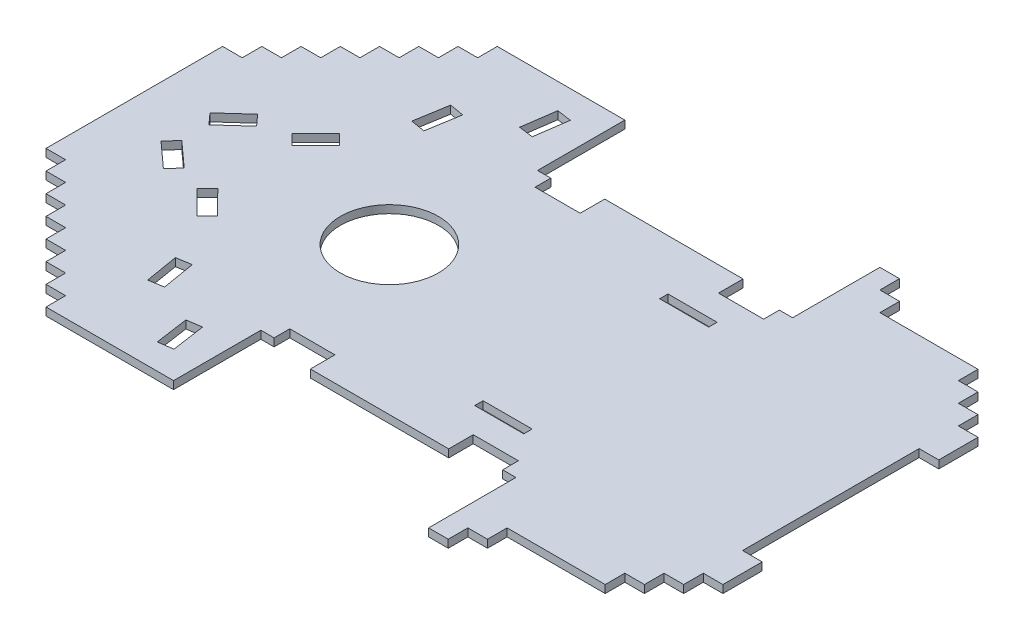
SolidWorks part; units mm, degrees
ref_plane "정면" through (0, 0, 0) normal (0, 0, 1) x (1, 0, 0)
ref_plane "윗면" through (0, 0, 0) normal (0, 1, 0) x (1, 0, 0)
ref_plane "우측면" through (0, 0, 0) normal (1, 0, 0) x (0, 0, -1)
sketch "스케치2" plane through (0, 0, 0) normal (0, 1, 0) x (1, 0, 0)
  line L0 (-96, -96) -> (96, 96) construction
  line L5 (-96, 96) -> (96, 96)
  line L39 (-96, 96) -> (-96, -96)
  line L40 (-96, -96) -> (96, -96)
  line L41 (96, 96) -> (96, -96)
  line L42 (-84, 84) -> (84, 84)
  line L43 (-84, 84) -> (-84, -84)
  line L44 (-84, -84) -> (84, -84)
  line L45 (84, 84) -> (84, -84)
  line L46 (-264, 84) -> (-264, -84)
  line L47 (-264, 84) -> (-96, 84)
  line L48 (-96, 84) -> (-96, -84)
  line L49 (-264, -84) -> (-96, -84)
  line L50 (-276, 96) -> (-276, -96)
  line L51 (-276, 96) -> (-84, 96)
  line L52 (-84, 96) -> (-84, -96)
  line L53 (-276, -96) -> (-84, -96)
  line L54 (-444, 84) -> (-444, -84)
  line L55 (-444, 84) -> (-276, 84)
  line L56 (-276, 84) -> (-276, -84)
  line L57 (-444, -84) -> (-276, -84)
  line L58 (-456, 96) -> (-456, -96)
  line L59 (-456, 96) -> (-264, 96)
  line L60 (-264, 96) -> (-264, -96)
  line L61 (-456, -96) -> (-264, -96)
  line L62 (-624, 84) -> (-624, -84)
  line L63 (-624, 84) -> (-456, 84)
  line L64 (-456, 84) -> (-456, -84)
  line L65 (-624, -84) -> (-456, -84)
  line L66 (-636, 96) -> (-636, -96)
  line L67 (-636, 96) -> (-444, 96)
  line L68 (-444, 96) -> (-444, -96)
  line L69 (-636, -96) -> (-444, -96)
  line L70 (-804, 84) -> (-804, -84)
  line L71 (-804, 84) -> (-636, 84)
  line L72 (-636, 84) -> (-636, -84)
  line L73 (-804, -84) -> (-636, -84)
  line L74 (-816, 96) -> (-816, -96)
  line L75 (-816, 96) -> (-624, 96)
  line L76 (-624, 96) -> (-624, -96)
  line L77 (-816, -96) -> (-624, -96)
  line L78 (-984, 84) -> (-984, -84)
  line L79 (-984, 84) -> (-816, 84)
  line L80 (-816, 84) -> (-816, -84)
  line L81 (-984, -84) -> (-816, -84)
  line L82 (-996, 96) -> (-996, -96)
  line L83 (-996, 96) -> (-804, 96)
  line L84 (-804, 96) -> (-804, -96)
  line L85 (-996, -96) -> (-804, -96)
  line L86 (-1164, 84) -> (-1164, -84)
  line L87 (-1164, 84) -> (-996, 84)
  line L88 (-996, 84) -> (-996, -84)
  line L89 (-1164, -84) -> (-996, -84)
  line L90 (-1176, 96) -> (-1176, -96)
  line L91 (-1176, 96) -> (-984, 96)
  line L92 (-984, 96) -> (-984, -96)
  line L93 (-1176, -96) -> (-984, -96)
  line L94 (-1344, 84) -> (-1344, -84)
  line L95 (-1344, 84) -> (-1176, 84)
  line L96 (-1176, 84) -> (-1176, -84)
  line L97 (-1344, -84) -> (-1176, -84)
  line L98 (-1356, 96) -> (-1356, -96)
  line L99 (-1356, 96) -> (-1164, 96)
  line L100 (-1164, 96) -> (-1164, -96)
  line L101 (-1356, -96) -> (-1164, -96)
  line L102 (-1524, 84) -> (-1524, -84)
  line L103 (-1524, 84) -> (-1356, 84)
  line L104 (-1356, 84) -> (-1356, -84)
  line L105 (-1524, -84) -> (-1356, -84)
  line L106 (-1536, 96) -> (-1536, -96)
  line L107 (-1536, 96) -> (-1344, 96)
  line L108 (-1344, 96) -> (-1344, -96)
  line L109 (-1536, -96) -> (-1344, -96)
  line L110 (-1704, 84) -> (-1704, -84)
  line L111 (-1704, 84) -> (-1536, 84)
  line L112 (-1536, 84) -> (-1536, -84)
  line L113 (-1704, -84) -> (-1536, -84)
  line L114 (-1716, 96) -> (-1716, -96)
  line L115 (-1716, 96) -> (-1524, 96)
  line L116 (-1524, 96) -> (-1524, -96)
  line L117 (-1716, -96) -> (-1524, -96)
  line L118 (-1884, 84) -> (-1884, -84)
  line L119 (-1884, 84) -> (-1716, 84)
  line L120 (-1716, 84) -> (-1716, -84)
  line L121 (-1884, -84) -> (-1716, -84)
  line L122 (-1896, 96) -> (-1896, -96)
  line L123 (-1896, 96) -> (-1704, 96)
  line L124 (-1704, 96) -> (-1704, -96)
  line L125 (-1896, -96) -> (-1704, -96)
  line L126 (-2064, 84) -> (-2064, -84)
  line L127 (-2064, 84) -> (-1896, 84)
  line L128 (-1896, 84) -> (-1896, -84)
  line L129 (-2064, -84) -> (-1896, -84)
  line L130 (-2076, 96) -> (-2076, -96)
  line L131 (-2076, 96) -> (-1884, 96)
  line L132 (-1884, 96) -> (-1884, -96)
  line L133 (-2076, -96) -> (-1884, -96)
  line L134 (-2244, 84) -> (-2244, -84)
  line L135 (-2244, 84) -> (-2076, 84)
  line L136 (-2076, 84) -> (-2076, -84)
  line L137 (-2244, -84) -> (-2076, -84)
  line L138 (-2256, 96) -> (-2256, -96)
  line L139 (-2256, 96) -> (-2064, 96)
  line L140 (-2064, 96) -> (-2064, -96)
  line L141 (-2256, -96) -> (-2064, -96)
  line L142 (-2424, 84) -> (-2424, -84)
  line L143 (-2424, 84) -> (-2256, 84)
  line L144 (-2256, 84) -> (-2256, -84)
  line L145 (-2424, -84) -> (-2256, -84)
  line L146 (-2436, 96) -> (-2436, -96)
  line L147 (-2436, 96) -> (-2244, 96)
  line L148 (-2244, 96) -> (-2244, -96)
  line L149 (-2436, -96) -> (-2244, -96)
  line L150 (-2604, 84) -> (-2604, -84)
  line L151 (-2604, 84) -> (-2436, 84)
  line L152 (-2436, 84) -> (-2436, -84)
  line L153 (-2604, -84) -> (-2436, -84)
  line L154 (-2616, 96) -> (-2616, -96)
  line L155 (-2616, 96) -> (-2424, 96)
  line L156 (-2424, 96) -> (-2424, -96)
  line L157 (-2616, -96) -> (-2424, -96)
  line L158 (-2784, 84) -> (-2784, -84)
  line L159 (-2784, 84) -> (-2616, 84)
  line L160 (-2616, 84) -> (-2616, -84)
  line L161 (-2784, -84) -> (-2616, -84)
  line L162 (-2796, 96) -> (-2796, -96)
  line L163 (-2796, 96) -> (-2604, 96)
  line L164 (-2604, 96) -> (-2604, -96)
  line L165 (-2796, -96) -> (-2604, -96)
  line L166 (-264, 264) -> (-264, 96)
  line L167 (-264, 264) -> (-96, 264)
  line L168 (-96, 264) -> (-96, 96)
  line L169 (-264, 96) -> (-96, 96)
  line L170 (-276, 276) -> (-276, 84)
  line L171 (-276, 276) -> (-84, 276)
  line L172 (-84, 276) -> (-84, 84)
  line L173 (-276, 84) -> (-84, 84)
  line L174 (-444, 264) -> (-444, 96)
  line L175 (-444, 264) -> (-276, 264)
  line L176 (-276, 264) -> (-276, 96)
  line L177 (-444, 96) -> (-276, 96)
  line L178 (-456, 276) -> (-456, 84)
  line L179 (-456, 276) -> (-264, 276)
  line L180 (-264, 276) -> (-264, 84)
  line L181 (-456, 84) -> (-264, 84)
  line L182 (-624, 264) -> (-624, 96)
  line L183 (-624, 264) -> (-456, 264)
  line L184 (-456, 264) -> (-456, 96)
  line L185 (-624, 96) -> (-456, 96)
  line L186 (-636, 276) -> (-636, 84)
  line L187 (-636, 276) -> (-444, 276)
  line L188 (-444, 276) -> (-444, 84)
  line L189 (-636, 84) -> (-444, 84)
  line L190 (-804, 264) -> (-804, 96)
  line L191 (-804, 264) -> (-636, 264)
  line L192 (-636, 264) -> (-636, 96)
  line L193 (-804, 96) -> (-636, 96)
  line L194 (-816, 276) -> (-816, 84)
  line L195 (-816, 276) -> (-624, 276)
  line L196 (-624, 276) -> (-624, 84)
  line L197 (-816, 84) -> (-624, 84)
  line L198 (-984, 264) -> (-984, 96)
  line L199 (-984, 264) -> (-816, 264)
  line L200 (-816, 264) -> (-816, 96)
  line L201 (-984, 96) -> (-816, 96)
  line L202 (-996, 276) -> (-996, 84)
  line L203 (-996, 276) -> (-804, 276)
  line L204 (-804, 276) -> (-804, 84)
  line L205 (-996, 84) -> (-804, 84)
  line L206 (-1164, 264) -> (-1164, 96)
  line L207 (-1164, 264) -> (-996, 264)
  line L208 (-996, 264) -> (-996, 96)
  line L209 (-1164, 96) -> (-996, 96)
  line L210 (-1176, 276) -> (-1176, 84)
  line L211 (-1176, 276) -> (-984, 276)
  line L212 (-984, 276) -> (-984, 84)
  line L213 (-1176, 84) -> (-984, 84)
  line L214 (-1344, 264) -> (-1344, 96)
  line L215 (-1344, 264) -> (-1176, 264)
  line L216 (-1176, 264) -> (-1176, 96)
  line L217 (-1344, 96) -> (-1176, 96)
  line L218 (-1356, 276) -> (-1356, 84)
  line L219 (-1356, 276) -> (-1164, 276)
  line L220 (-1164, 276) -> (-1164, 84)
  line L221 (-1356, 84) -> (-1164, 84)
  line L222 (-1524, 264) -> (-1524, 96)
  line L223 (-1524, 264) -> (-1356, 264)
  line L224 (-1356, 264) -> (-1356, 96)
  line L225 (-1524, 96) -> (-1356, 96)
  line L226 (-1536, 276) -> (-1536, 84)
  line L227 (-1536, 276) -> (-1344, 276)
  line L228 (-1344, 276) -> (-1344, 84)
  line L229 (-1536, 84) -> (-1344, 84)
  line L230 (-1704, 264) -> (-1704, 96)
  line L231 (-1704, 264) -> (-1536, 264)
  line L232 (-1536, 264) -> (-1536, 96)
  line L233 (-1704, 96) -> (-1536, 96)
  line L234 (-1716, 276) -> (-1716, 84)
  line L235 (-1716, 276) -> (-1524, 276)
  line L236 (-1524, 276) -> (-1524, 84)
  line L237 (-1716, 84) -> (-1524, 84)
  line L238 (-1884, 264) -> (-1884, 96)
  line L239 (-1884, 264) -> (-1716, 264)
  line L240 (-1716, 264) -> (-1716, 96)
  line L241 (-1884, 96) -> (-1716, 96)
  line L242 (-1896, 276) -> (-1896, 84)
  line L243 (-1896, 276) -> (-1704, 276)
  line L244 (-1704, 276) -> (-1704, 84)
  line L245 (-1896, 84) -> (-1704, 84)
  line L246 (-2064, 264) -> (-2064, 96)
  line L247 (-2064, 264) -> (-1896, 264)
  line L248 (-1896, 264) -> (-1896, 96)
  line L249 (-2064, 96) -> (-1896, 96)
  line L250 (-2076, 276) -> (-2076, 84)
  line L251 (-2076, 276) -> (-1884, 276)
  line L252 (-1884, 276) -> (-1884, 84)
  line L253 (-2076, 84) -> (-1884, 84)
  line L254 (-2244, 264) -> (-2244, 96)
  line L255 (-2244, 264) -> (-2076, 264)
  line L256 (-2076, 264) -> (-2076, 96)
  line L257 (-2244, 96) -> (-2076, 96)
  line L258 (-2256, 276) -> (-2256, 84)
  line L259 (-2256, 276) -> (-2064, 276)
  line L260 (-2064, 276) -> (-2064, 84)
  line L261 (-2256, 84) -> (-2064, 84)
  line L262 (-2424, 264) -> (-2424, 96)
  line L263 (-2424, 264) -> (-2256, 264)
  line L264 (-2256, 264) -> (-2256, 96)
  line L265 (-2424, 96) -> (-2256, 96)
  line L266 (-2436, 276) -> (-2436, 84)
  line L267 (-2436, 276) -> (-2244, 276)
  line L268 (-2244, 276) -> (-2244, 84)
  line L269 (-2436, 84) -> (-2244, 84)
  line L270 (-2604, 264) -> (-2604, 96)
  line L271 (-2604, 264) -> (-2436, 264)
  line L272 (-2436, 264) -> (-2436, 96)
  line L273 (-2604, 96) -> (-2436, 96)
  line L274 (-2616, 276) -> (-2616, 84)
  line L275 (-2616, 276) -> (-2424, 276)
  line L276 (-2424, 276) -> (-2424, 84)
  line L277 (-2616, 84) -> (-2424, 84)
  line L278 (-2784, 264) -> (-2784, 96)
  line L279 (-2784, 264) -> (-2616, 264)
  line L280 (-2616, 264) -> (-2616, 96)
  line L281 (-2784, 96) -> (-2616, 96)
  line L282 (-2796, 276) -> (-2796, 84)
  line L283 (-2796, 276) -> (-2604, 276)
  line L284 (-2604, 276) -> (-2604, 84)
  line L285 (-2796, 84) -> (-2604, 84)
  line L286 (-264, 444) -> (-264, 276)
  line L287 (-264, 444) -> (-96, 444)
  line L288 (-96, 444) -> (-96, 276)
  line L289 (-264, 276) -> (-96, 276)
  line L290 (-276, 456) -> (-276, 264)
  line L291 (-276, 456) -> (-84, 456)
  line L292 (-84, 456) -> (-84, 264)
  line L293 (-276, 264) -> (-84, 264)
  line L294 (-444, 444) -> (-444, 276)
  line L295 (-444, 444) -> (-276, 444)
  line L296 (-276, 444) -> (-276, 276)
  line L297 (-444, 276) -> (-276, 276)
  line L298 (-456, 456) -> (-456, 264)
  line L299 (-456, 456) -> (-264, 456)
  line L300 (-264, 456) -> (-264, 264)
  line L301 (-456, 264) -> (-264, 264)
  line L302 (-624, 444) -> (-624, 276)
  line L303 (-624, 444) -> (-456, 444)
  line L304 (-456, 444) -> (-456, 276)
  line L305 (-624, 276) -> (-456, 276)
  line L306 (-636, 456) -> (-636, 264)
  line L307 (-636, 456) -> (-444, 456)
  line L308 (-444, 456) -> (-444, 264)
  line L309 (-636, 264) -> (-444, 264)
  line L310 (-804, 444) -> (-804, 276)
  line L311 (-804, 444) -> (-636, 444)
  line L312 (-636, 444) -> (-636, 276)
  line L313 (-804, 276) -> (-636, 276)
  line L314 (-816, 456) -> (-816, 264)
  line L315 (-816, 456) -> (-624, 456)
  line L316 (-624, 456) -> (-624, 264)
  line L317 (-816, 264) -> (-624, 264)
  line L318 (-984, 444) -> (-984, 276)
  line L319 (-984, 444) -> (-816, 444)
  line L320 (-816, 444) -> (-816, 276)
  line L321 (-984, 276) -> (-816, 276)
  line L322 (-996, 456) -> (-996, 264)
  line L323 (-996, 456) -> (-804, 456)
  line L324 (-804, 456) -> (-804, 264)
  line L325 (-996, 264) -> (-804, 264)
  line L326 (-1164, 444) -> (-1164, 276)
  line L327 (-1164, 444) -> (-996, 444)
  line L328 (-996, 444) -> (-996, 276)
  line L329 (-1164, 276) -> (-996, 276)
  line L330 (-1176, 456) -> (-1176, 264)
  line L331 (-1176, 456) -> (-984, 456)
  line L332 (-984, 456) -> (-984, 264)
  line L333 (-1176, 264) -> (-984, 264)
  line L334 (-1344, 444) -> (-1344, 276)
  line L335 (-1344, 444) -> (-1176, 444)
  line L336 (-1176, 444) -> (-1176, 276)
  line L337 (-1344, 276) -> (-1176, 276)
  line L338 (-1356, 456) -> (-1356, 264)
  line L339 (-1356, 456) -> (-1164, 456)
  line L340 (-1164, 456) -> (-1164, 264)
  line L341 (-1356, 264) -> (-1164, 264)
  line L342 (-1524, 444) -> (-1524, 276)
  line L343 (-1524, 444) -> (-1356, 444)
  line L344 (-1356, 444) -> (-1356, 276)
  line L345 (-1524, 276) -> (-1356, 276)
  line L346 (-1536, 456) -> (-1536, 264)
  line L347 (-1536, 456) -> (-1344, 456)
  line L348 (-1344, 456) -> (-1344, 264)
  line L349 (-1536, 264) -> (-1344, 264)
  line L350 (-1704, 444) -> (-1704, 276)
  line L351 (-1704, 444) -> (-1536, 444)
  line L352 (-1536, 444) -> (-1536, 276)
  line L353 (-1704, 276) -> (-1536, 276)
  line L354 (-1716, 456) -> (-1716, 264)
  line L355 (-1716, 456) -> (-1524, 456)
  line L356 (-1524, 456) -> (-1524, 264)
  line L357 (-1716, 264) -> (-1524, 264)
  line L358 (-1884, 444) -> (-1884, 276)
  line L359 (-1884, 444) -> (-1716, 444)
  line L360 (-1716, 444) -> (-1716, 276)
  line L361 (-1884, 276) -> (-1716, 276)
  line L362 (-1896, 456) -> (-1896, 264)
  line L363 (-1896, 456) -> (-1704, 456)
  line L364 (-1704, 456) -> (-1704, 264)
  line L365 (-1896, 264) -> (-1704, 264)
  line L366 (-2064, 444) -> (-2064, 276)
  line L367 (-2064, 444) -> (-1896, 444)
  line L368 (-1896, 444) -> (-1896, 276)
  line L369 (-2064, 276) -> (-1896, 276)
  line L370 (-2076, 456) -> (-2076, 264)
  line L371 (-2076, 456) -> (-1884, 456)
  line L372 (-1884, 456) -> (-1884, 264)
  line L373 (-2076, 264) -> (-1884, 264)
  line L374 (-2244, 444) -> (-2244, 276)
  line L375 (-2244, 444) -> (-2076, 444)
  line L376 (-2076, 444) -> (-2076, 276)
  line L377 (-2244, 276) -> (-2076, 276)
  line L378 (-2256, 456) -> (-2256, 264)
  line L379 (-2256, 456) -> (-2064, 456)
  line L380 (-2064, 456) -> (-2064, 264)
  line L381 (-2256, 264) -> (-2064, 264)
  line L382 (-2424, 444) -> (-2424, 276)
  line L383 (-2424, 444) -> (-2256, 444)
  line L384 (-2256, 444) -> (-2256, 276)
  line L385 (-2424, 276) -> (-2256, 276)
  line L386 (-2436, 456) -> (-2436, 264)
  line L387 (-2436, 456) -> (-2244, 456)
  line L388 (-2244, 456) -> (-2244, 264)
  line L389 (-2436, 264) -> (-2244, 264)
  line L390 (-2604, 444) -> (-2604, 276)
  line L391 (-2604, 444) -> (-2436, 444)
  line L392 (-2436, 444) -> (-2436, 276)
  line L393 (-2604, 276) -> (-2436, 276)
  line L394 (-2616, 456) -> (-2616, 264)
  line L395 (-2616, 456) -> (-2424, 456)
  line L396 (-2424, 456) -> (-2424, 264)
  line L397 (-2616, 264) -> (-2424, 264)
  line L398 (-2784, 444) -> (-2784, 276)
  line L399 (-2784, 444) -> (-2616, 444)
  line L400 (-2616, 444) -> (-2616, 276)
  line L401 (-2784, 276) -> (-2616, 276)
  line L402 (-2796, 456) -> (-2796, 264)
  line L403 (-2796, 456) -> (-2604, 456)
  line L404 (-2604, 456) -> (-2604, 264)
  line L405 (-2796, 264) -> (-2604, 264)
  line L406 (-264, 624) -> (-264, 456)
  line L407 (-264, 624) -> (-96, 624)
  line L408 (-96, 624) -> (-96, 456)
  line L409 (-264, 456) -> (-96, 456)
  line L410 (-276, 636) -> (-276, 444)
  line L411 (-276, 636) -> (-84, 636)
  line L412 (-84, 636) -> (-84, 444)
  line L413 (-276, 444) -> (-84, 444)
  line L414 (-444, 624) -> (-444, 456)
  line L415 (-444, 624) -> (-276, 624)
  line L416 (-276, 624) -> (-276, 456)
  line L417 (-444, 456) -> (-276, 456)
  line L418 (-456, 636) -> (-456, 444)
  line L419 (-456, 636) -> (-264, 636)
  line L420 (-264, 636) -> (-264, 444)
  line L421 (-456, 444) -> (-264, 444)
  line L422 (-624, 624) -> (-624, 456)
  line L423 (-624, 624) -> (-456, 624)
  line L424 (-456, 624) -> (-456, 456)
  line L425 (-624, 456) -> (-456, 456)
  line L426 (-636, 636) -> (-636, 444)
  line L427 (-636, 636) -> (-444, 636)
  line L428 (-444, 636) -> (-444, 444)
  line L429 (-636, 444) -> (-444, 444)
  line L430 (-804, 624) -> (-804, 456)
  line L431 (-804, 624) -> (-636, 624)
  line L432 (-636, 624) -> (-636, 456)
  line L433 (-804, 456) -> (-636, 456)
  line L434 (-816, 636) -> (-816, 444)
  line L435 (-816, 636) -> (-624, 636)
  line L436 (-624, 636) -> (-624, 444)
  line L437 (-816, 444) -> (-624, 444)
  line L438 (-984, 624) -> (-984, 456)
  line L439 (-984, 624) -> (-816, 624)
  line L440 (-816, 624) -> (-816, 456)
  line L441 (-984, 456) -> (-816, 456)
  line L442 (-996, 636) -> (-996, 444)
  line L443 (-996, 636) -> (-804, 636)
  line L444 (-804, 636) -> (-804, 444)
  line L445 (-996, 444) -> (-804, 444)
  line L446 (-1164, 624) -> (-1164, 456)
  line L447 (-1164, 624) -> (-996, 624)
  line L448 (-996, 624) -> (-996, 456)
  line L449 (-1164, 456) -> (-996, 456)
  line L450 (-1176, 636) -> (-1176, 444)
  line L451 (-1176, 636) -> (-984, 636)
  line L452 (-984, 636) -> (-984, 444)
  line L453 (-1176, 444) -> (-984, 444)
  line L454 (-1344, 624) -> (-1344, 456)
  line L455 (-1344, 624) -> (-1176, 624)
  line L456 (-1176, 624) -> (-1176, 456)
  line L457 (-1344, 456) -> (-1176, 456)
  line L458 (-1356, 636) -> (-1356, 444)
  line L459 (-1356, 636) -> (-1164, 636)
  line L460 (-1164, 636) -> (-1164, 444)
  line L461 (-1356, 444) -> (-1164, 444)
  line L462 (-1524, 624) -> (-1524, 456)
  line L463 (-1524, 624) -> (-1356, 624)
  line L464 (-1356, 624) -> (-1356, 456)
  line L465 (-1524, 456) -> (-1356, 456)
  line L466 (-1536, 636) -> (-1536, 444)
  line L467 (-1536, 636) -> (-1344, 636)
  line L468 (-1344, 636) -> (-1344, 444)
  line L469 (-1536, 444) -> (-1344, 444)
  line L470 (-1704, 624) -> (-1704, 456)
  line L471 (-1704, 624) -> (-1536, 624)
  line L472 (-1536, 624) -> (-1536, 456)
  line L473 (-1704, 456) -> (-1536, 456)
  line L474 (-1716, 636) -> (-1716, 444)
  line L475 (-1716, 636) -> (-1524, 636)
  line L476 (-1524, 636) -> (-1524, 444)
  line L477 (-1716, 444) -> (-1524, 444)
  line L478 (-1884, 624) -> (-1884, 456)
  line L479 (-1884, 624) -> (-1716, 624)
  line L480 (-1716, 624) -> (-1716, 456)
  line L481 (-1884, 456) -> (-1716, 456)
  line L482 (-1896, 636) -> (-1896, 444)
  line L483 (-1896, 636) -> (-1704, 636)
  line L484 (-1704, 636) -> (-1704, 444)
  line L485 (-1896, 444) -> (-1704, 444)
  line L486 (-2064, 624) -> (-2064, 456)
  line L487 (-2064, 624) -> (-1896, 624)
  line L488 (-1896, 624) -> (-1896, 456)
  line L489 (-2064, 456) -> (-1896, 456)
  line L490 (-2076, 636) -> (-2076, 444)
  line L491 (-2076, 636) -> (-1884, 636)
  line L492 (-1884, 636) -> (-1884, 444)
  line L493 (-2076, 444) -> (-1884, 444)
  line L494 (-2244, 624) -> (-2244, 456)
  line L495 (-2244, 624) -> (-2076, 624)
  line L496 (-2076, 624) -> (-2076, 456)
  line L497 (-2244, 456) -> (-2076, 456)
  line L498 (-2256, 636) -> (-2256, 444)
  line L499 (-2256, 636) -> (-2064, 636)
  line L500 (-2064, 636) -> (-2064, 444)
  line L501 (-2256, 444) -> (-2064, 444)
  line L502 (-2424, 624) -> (-2424, 456)
  line L503 (-2424, 624) -> (-2256, 624)
  line L504 (-2256, 624) -> (-2256, 456)
  line L505 (-2424, 456) -> (-2256, 456)
  line L506 (-2436, 636) -> (-2436, 444)
  line L507 (-2436, 636) -> (-2244, 636)
  line L508 (-2244, 636) -> (-2244, 444)
  line L509 (-2436, 444) -> (-2244, 444)
  line L510 (-2604, 624) -> (-2604, 456)
  line L511 (-2604, 624) -> (-2436, 624)
  line L512 (-2436, 624) -> (-2436, 456)
  line L513 (-2604, 456) -> (-2436, 456)
  line L514 (-2616, 636) -> (-2616, 444)
  line L515 (-2616, 636) -> (-2424, 636)
  line L516 (-2424, 636) -> (-2424, 444)
  line L517 (-2616, 444) -> (-2424, 444)
  line L518 (-2784, 624) -> (-2784, 456)
  line L519 (-2784, 624) -> (-2616, 624)
  line L520 (-2616, 624) -> (-2616, 456)
  line L521 (-2784, 456) -> (-2616, 456)
  line L522 (-2796, 636) -> (-2796, 444)
  line L523 (-2796, 636) -> (-2604, 636)
  line L524 (-2604, 636) -> (-2604, 444)
  line L525 (-2796, 444) -> (-2604, 444)
  line L526 (-264, 804) -> (-264, 636)
  line L527 (-264, 804) -> (-96, 804)
  line L528 (-96, 804) -> (-96, 636)
  line L529 (-264, 636) -> (-96, 636)
  line L530 (-276, 816) -> (-276, 624)
  line L531 (-276, 816) -> (-84, 816)
  line L532 (-84, 816) -> (-84, 624)
  line L533 (-276, 624) -> (-84, 624)
  line L534 (-444, 804) -> (-444, 636)
  line L535 (-444, 804) -> (-276, 804)
  line L536 (-276, 804) -> (-276, 636)
  line L537 (-444, 636) -> (-276, 636)
  line L538 (-456, 816) -> (-456, 624)
  line L539 (-456, 816) -> (-264, 816)
  line L540 (-264, 816) -> (-264, 624)
  line L541 (-456, 624) -> (-264, 624)
  line L542 (-624, 804) -> (-624, 636)
  line L543 (-624, 804) -> (-456, 804)
  line L544 (-456, 804) -> (-456, 636)
  line L545 (-624, 636) -> (-456, 636)
  line L546 (-636, 816) -> (-636, 624)
  line L547 (-636, 816) -> (-444, 816)
  line L548 (-444, 816) -> (-444, 624)
  line L549 (-636, 624) -> (-444, 624)
  line L550 (-804, 804) -> (-804, 636)
  line L551 (-804, 804) -> (-636, 804)
  line L552 (-636, 804) -> (-636, 636)
  line L553 (-804, 636) -> (-636, 636)
  line L554 (-816, 816) -> (-816, 624)
  line L555 (-816, 816) -> (-624, 816)
  line L556 (-624, 816) -> (-624, 624)
  line L557 (-816, 624) -> (-624, 624)
  line L558 (-984, 804) -> (-984, 636)
  line L559 (-984, 804) -> (-816, 804)
  line L560 (-816, 804) -> (-816, 636)
  line L561 (-984, 636) -> (-816, 636)
  line L562 (-996, 816) -> (-996, 624)
  line L563 (-996, 816) -> (-804, 816)
  line L564 (-804, 816) -> (-804, 624)
  line L565 (-996, 624) -> (-804, 624)
  line L566 (-1164, 804) -> (-1164, 636)
  line L567 (-1164, 804) -> (-996, 804)
  line L568 (-996, 804) -> (-996, 636)
  line L569 (-1164, 636) -> (-996, 636)
  line L570 (-1176, 816) -> (-1176, 624)
  line L571 (-1176, 816) -> (-984, 816)
  line L572 (-984, 816) -> (-984, 624)
  line L573 (-1176, 624) -> (-984, 624)
  line L574 (-1344, 804) -> (-1344, 636)
  line L575 (-1344, 804) -> (-1176, 804)
  line L576 (-1176, 804) -> (-1176, 636)
  line L577 (-1344, 636) -> (-1176, 636)
  line L578 (-1356, 816) -> (-1356, 624)
  line L579 (-1356, 816) -> (-1164, 816)
  line L580 (-1164, 816) -> (-1164, 624)
  line L581 (-1356, 624) -> (-1164, 624)
  line L582 (-1524, 804) -> (-1524, 636)
  line L583 (-1524, 804) -> (-1356, 804)
  line L584 (-1356, 804) -> (-1356, 636)
  line L585 (-1524, 636) -> (-1356, 636)
  line L586 (-1536, 816) -> (-1536, 624)
  line L587 (-1536, 816) -> (-1344, 816)
  line L588 (-1344, 816) -> (-1344, 624)
  line L589 (-1536, 624) -> (-1344, 624)
  line L590 (-1704, 804) -> (-1704, 636)
  line L591 (-1704, 804) -> (-1536, 804)
  line L592 (-1536, 804) -> (-1536, 636)
  line L593 (-1704, 636) -> (-1536, 636)
  line L594 (-1716, 816) -> (-1716, 624)
  line L595 (-1716, 816) -> (-1524, 816)
  line L596 (-1524, 816) -> (-1524, 624)
  line L597 (-1716, 624) -> (-1524, 624)
  line L598 (-1884, 804) -> (-1884, 636)
  line L599 (-1884, 804) -> (-1716, 804)
  line L600 (-1716, 804) -> (-1716, 636)
  line L601 (-1884, 636) -> (-1716, 636)
  line L602 (-1896, 816) -> (-1896, 624)
  line L603 (-1896, 816) -> (-1704, 816)
  line L604 (-1704, 816) -> (-1704, 624)
  line L605 (-1896, 624) -> (-1704, 624)
  line L606 (-2064, 804) -> (-2064, 636)
  line L607 (-2064, 804) -> (-1896, 804)
  line L608 (-1896, 804) -> (-1896, 636)
  line L609 (-2064, 636) -> (-1896, 636)
  line L610 (-2076, 816) -> (-2076, 624)
  line L611 (-2076, 816) -> (-1884, 816)
  line L612 (-1884, 816) -> (-1884, 624)
  line L613 (-2076, 624) -> (-1884, 624)
  line L614 (-2244, 804) -> (-2244, 636)
  line L615 (-2244, 804) -> (-2076, 804)
  line L616 (-2076, 804) -> (-2076, 636)
  line L617 (-2244, 636) -> (-2076, 636)
  line L618 (-2256, 816) -> (-2256, 624)
  line L619 (-2256, 816) -> (-2064, 816)
  line L620 (-2064, 816) -> (-2064, 624)
  line L621 (-2256, 624) -> (-2064, 624)
  line L622 (-2424, 804) -> (-2424, 636)
  line L623 (-2424, 804) -> (-2256, 804)
  line L624 (-2256, 804) -> (-2256, 636)
  line L625 (-2424, 636) -> (-2256, 636)
  line L626 (-2436, 816) -> (-2436, 624)
  line L627 (-2436, 816) -> (-2244, 816)
  line L628 (-2244, 816) -> (-2244, 624)
  line L629 (-2436, 624) -> (-2244, 624)
  line L630 (-2604, 804) -> (-2604, 636)
  line L631 (-2604, 804) -> (-2436, 804)
  line L632 (-2436, 804) -> (-2436, 636)
  line L633 (-2604, 636) -> (-2436, 636)
  line L634 (-2616, 816) -> (-2616, 624)
  line L635 (-2616, 816) -> (-2424, 816)
  line L636 (-2424, 816) -> (-2424, 624)
  line L637 (-2616, 624) -> (-2424, 624)
  line L638 (-2784, 804) -> (-2784, 636)
  line L639 (-2784, 804) -> (-2616, 804)
  line L640 (-2616, 804) -> (-2616, 636)
  line L641 (-2784, 636) -> (-2616, 636)
  line L642 (-2796, 816) -> (-2796, 624)
  line L643 (-2796, 816) -> (-2604, 816)
  line L644 (-2604, 816) -> (-2604, 624)
  line L645 (-2796, 624) -> (-2604, 624)
  line L646 (-264, 984) -> (-264, 816)
  line L647 (-264, 984) -> (-96, 984)
  line L648 (-96, 984) -> (-96, 816)
  line L649 (-264, 816) -> (-96, 816)
  line L650 (-276, 996) -> (-276, 804)
  line L651 (-276, 996) -> (-84, 996)
  line L652 (-84, 996) -> (-84, 804)
  line L653 (-276, 804) -> (-84, 804)
  line L654 (-444, 984) -> (-444, 816)
  line L655 (-444, 984) -> (-276, 984)
  line L656 (-276, 984) -> (-276, 816)
  line L657 (-444, 816) -> (-276, 816)
  line L658 (-456, 996) -> (-456, 804)
  line L659 (-456, 996) -> (-264, 996)
  line L660 (-264, 996) -> (-264, 804)
  line L661 (-456, 804) -> (-264, 804)
  line L662 (-624, 984) -> (-624, 816)
  line L663 (-624, 984) -> (-456, 984)
  line L664 (-456, 984) -> (-456, 816)
  line L665 (-624, 816) -> (-456, 816)
  line L666 (-636, 996) -> (-636, 804)
  line L667 (-636, 996) -> (-444, 996)
  line L668 (-444, 996) -> (-444, 804)
  line L669 (-636, 804) -> (-444, 804)
  line L670 (-804, 984) -> (-804, 816)
  line L671 (-804, 984) -> (-636, 984)
  line L672 (-636, 984) -> (-636, 816)
  line L673 (-804, 816) -> (-636, 816)
  line L674 (-816, 996) -> (-816, 804)
  line L675 (-816, 996) -> (-624, 996)
  line L676 (-624, 996) -> (-624, 804)
  line L677 (-816, 804) -> (-624, 804)
  line L678 (-984, 984) -> (-984, 816)
  line L679 (-984, 984) -> (-816, 984)
  line L680 (-816, 984) -> (-816, 816)
  line L681 (-984, 816) -> (-816, 816)
  line L682 (-996, 996) -> (-996, 804)
  line L683 (-996, 996) -> (-804, 996)
  line L684 (-804, 996) -> (-804, 804)
  line L685 (-996, 804) -> (-804, 804)
  line L686 (-1164, 984) -> (-1164, 816)
  line L687 (-1164, 984) -> (-996, 984)
  line L688 (-996, 984) -> (-996, 816)
  line L689 (-1164, 816) -> (-996, 816)
  line L690 (-1176, 996) -> (-1176, 804)
  line L691 (-1176, 996) -> (-984, 996)
  line L692 (-984, 996) -> (-984, 804)
  line L693 (-1176, 804) -> (-984, 804)
  line L694 (-1344, 984) -> (-1344, 816)
  line L695 (-1344, 984) -> (-1176, 984)
  line L696 (-1176, 984) -> (-1176, 816)
  line L697 (-1344, 816) -> (-1176, 816)
  line L698 (-1356, 996) -> (-1356, 804)
  line L699 (-1356, 996) -> (-1164, 996)
  line L700 (-1164, 996) -> (-1164, 804)
  line L701 (-1356, 804) -> (-1164, 804)
  line L702 (-1524, 984) -> (-1524, 816)
  line L703 (-1524, 984) -> (-1356, 984)
  line L704 (-1356, 984) -> (-1356, 816)
  line L705 (-1524, 816) -> (-1356, 816)
  line L706 (-1536, 996) -> (-1536, 804)
  line L707 (-1536, 996) -> (-1344, 996)
  line L708 (-1344, 996) -> (-1344, 804)
  line L709 (-1536, 804) -> (-1344, 804)
  line L710 (-1704, 984) -> (-1704, 816)
  line L711 (-1704, 984) -> (-1536, 984)
  line L712 (-1536, 984) -> (-1536, 816)
  line L713 (-1704, 816) -> (-1536, 816)
  line L714 (-1716, 996) -> (-1716, 804)
  line L715 (-1716, 996) -> (-1524, 996)
  line L716 (-1524, 996) -> (-1524, 804)
  line L717 (-1716, 804) -> (-1524, 804)
  line L718 (-1884, 984) -> (-1884, 816)
  line L719 (-1884, 984) -> (-1716, 984)
  line L720 (-1716, 984) -> (-1716, 816)
  line L721 (-1884, 816) -> (-1716, 816)
  line L722 (-1896, 996) -> (-1896, 804)
  line L723 (-1896, 996) -> (-1704, 996)
  line L724 (-1704, 996) -> (-1704, 804)
  line L725 (-1896, 804) -> (-1704, 804)
  line L726 (-2064, 984) -> (-2064, 816)
  line L727 (-2064, 984) -> (-1896, 984)
  line L728 (-1896, 984) -> (-1896, 816)
  line L729 (-2064, 816) -> (-1896, 816)
  line L730 (-2076, 996) -> (-2076, 804)
  line L731 (-2076, 996) -> (-1884, 996)
  line L732 (-1884, 996) -> (-1884, 804)
  line L733 (-2076, 804) -> (-1884, 804)
  line L734 (-2244, 984) -> (-2244, 816)
  line L735 (-2244, 984) -> (-2076, 984)
  line L736 (-2076, 984) -> (-2076, 816)
  line L737 (-2244, 816) -> (-2076, 816)
  line L738 (-2256, 996) -> (-2256, 804)
  line L739 (-2256, 996) -> (-2064, 996)
  line L740 (-2064, 996) -> (-2064, 804)
  line L741 (-2256, 804) -> (-2064, 804)
  line L742 (-2424, 984) -> (-2424, 816)
  line L743 (-2424, 984) -> (-2256, 984)
  line L744 (-2256, 984) -> (-2256, 816)
  line L745 (-2424, 816) -> (-2256, 816)
  line L746 (-2436, 996) -> (-2436, 804)
  line L747 (-2436, 996) -> (-2244, 996)
  line L748 (-2244, 996) -> (-2244, 804)
  line L749 (-2436, 804) -> (-2244, 804)
  line L750 (-2604, 984) -> (-2604, 816)
  line L751 (-2604, 984) -> (-2436, 984)
  line L752 (-2436, 984) -> (-2436, 816)
  line L753 (-2604, 816) -> (-2436, 816)
  line L754 (-2616, 996) -> (-2616, 804)
  line L755 (-2616, 996) -> (-2424, 996)
  line L756 (-2424, 996) -> (-2424, 804)
  line L757 (-2616, 804) -> (-2424, 804)
  line L758 (-2784, 984) -> (-2784, 816)
  line L759 (-2784, 984) -> (-2616, 984)
  line L760 (-2616, 984) -> (-2616, 816)
  line L761 (-2784, 816) -> (-2616, 816)
  line L762 (-2796, 996) -> (-2796, 804)
  line L763 (-2796, 996) -> (-2604, 996)
  line L764 (-2604, 996) -> (-2604, 804)
  line L765 (-2796, 804) -> (-2604, 804)
  line L766 (-264, 1164) -> (-264, 996)
  line L767 (-264, 1164) -> (-96, 1164)
  line L768 (-96, 1164) -> (-96, 996)
  line L769 (-264, 996) -> (-96, 996)
  line L770 (-276, 1176) -> (-276, 984)
  line L771 (-276, 1176) -> (-84, 1176)
  line L772 (-84, 1176) -> (-84, 984)
  line L773 (-276, 984) -> (-84, 984)
  line L774 (-444, 1164) -> (-444, 996)
  line L775 (-444, 1164) -> (-276, 1164)
  line L776 (-276, 1164) -> (-276, 996)
  line L777 (-444, 996) -> (-276, 996)
  line L778 (-456, 1176) -> (-456, 984)
  line L779 (-456, 1176) -> (-264, 1176)
  line L780 (-264, 1176) -> (-264, 984)
  line L781 (-456, 984) -> (-264, 984)
  line L782 (-624, 1164) -> (-624, 996)
  line L783 (-624, 1164) -> (-456, 1164)
  line L784 (-456, 1164) -> (-456, 996)
  line L785 (-624, 996) -> (-456, 996)
  line L786 (-636, 1176) -> (-636, 984)
  line L787 (-636, 1176) -> (-444, 1176)
  line L788 (-444, 1176) -> (-444, 984)
  line L789 (-636, 984) -> (-444, 984)
  line L790 (-804, 1164) -> (-804, 996)
  line L791 (-804, 1164) -> (-636, 1164)
  line L792 (-636, 1164) -> (-636, 996)
  line L793 (-804, 996) -> (-636, 996)
  line L794 (-816, 1176) -> (-816, 984)
  line L795 (-816, 1176) -> (-624, 1176)
  line L796 (-624, 1176) -> (-624, 984)
  line L797 (-816, 984) -> (-624, 984)
  line L798 (-984, 1164) -> (-984, 996)
  line L799 (-984, 1164) -> (-816, 1164)
  line L800 (-816, 1164) -> (-816, 996)
  line L801 (-984, 996) -> (-816, 996)
  line L802 (-996, 1176) -> (-996, 984)
  line L803 (-996, 1176) -> (-804, 1176)
  line L804 (-804, 1176) -> (-804, 984)
  line L805 (-996, 984) -> (-804, 984)
  line L806 (-1164, 1164) -> (-1164, 996)
  line L807 (-1164, 1164) -> (-996, 1164)
  line L808 (-996, 1164) -> (-996, 996)
  line L809 (-1164, 996) -> (-996, 996)
  line L810 (-1176, 1176) -> (-1176, 984)
  line L811 (-1176, 1176) -> (-984, 1176)
  line L812 (-984, 1176) -> (-984, 984)
  line L813 (-1176, 984) -> (-984, 984)
  line L814 (-1344, 1164) -> (-1344, 996)
  line L815 (-1344, 1164) -> (-1176, 1164)
  line L816 (-1176, 1164) -> (-1176, 996)
  line L817 (-1344, 996) -> (-1176, 996)
  line L818 (-1356, 1176) -> (-1356, 984)
  line L819 (-1356, 1176) -> (-1164, 1176)
  line L820 (-1164, 1176) -> (-1164, 984)
  line L821 (-1356, 984) -> (-1164, 984)
  line L822 (-1524, 1164) -> (-1524, 996)
  line L823 (-1524, 1164) -> (-1356, 1164)
  line L824 (-1356, 1164) -> (-1356, 996)
  line L825 (-1524, 996) -> (-1356, 996)
  line L826 (-1536, 1176) -> (-1536, 984)
  line L827 (-1536, 1176) -> (-1344, 1176)
  line L828 (-1344, 1176) -> (-1344, 984)
  line L829 (-1536, 984) -> (-1344, 984)
  line L830 (-1704, 1164) -> (-1704, 996)
  line L831 (-1704, 1164) -> (-1536, 1164)
  line L832 (-1536, 1164) -> (-1536, 996)
  line L833 (-1704, 996) -> (-1536, 996)
  line L834 (-1716, 1176) -> (-1716, 984)
  line L835 (-1716, 1176) -> (-1524, 1176)
  line L836 (-1524, 1176) -> (-1524, 984)
  line L837 (-1716, 984) -> (-1524, 984)
  line L838 (-1884, 1164) -> (-1884, 996)
  line L839 (-1884, 1164) -> (-1716, 1164)
  line L840 (-1716, 1164) -> (-1716, 996)
  line L841 (-1884, 996) -> (-1716, 996)
  line L842 (-1896, 1176) -> (-1896, 984)
  line L843 (-1896, 1176) -> (-1704, 1176)
  line L844 (-1704, 1176) -> (-1704, 984)
  line L845 (-1896, 984) -> (-1704, 984)
  line L846 (-2064, 1164) -> (-2064, 996)
  line L847 (-2064, 1164) -> (-1896, 1164)
  line L848 (-1896, 1164) -> (-1896, 996)
  line L849 (-2064, 996) -> (-1896, 996)
  line L850 (-2076, 1176) -> (-2076, 984)
  line L851 (-2076, 1176) -> (-1884, 1176)
  line L852 (-1884, 1176) -> (-1884, 984)
  line L853 (-2076, 984) -> (-1884, 984)
  line L854 (-2244, 1164) -> (-2244, 996)
  line L855 (-2244, 1164) -> (-2076, 1164)
  line L856 (-2076, 1164) -> (-2076, 996)
  line L857 (-2244, 996) -> (-2076, 996)
  line L858 (-2256, 1176) -> (-2256, 984)
  line L859 (-2256, 1176) -> (-2064, 1176)
  line L860 (-2064, 1176) -> (-2064, 984)
  line L861 (-2256, 984) -> (-2064, 984)
  line L862 (-2424, 1164) -> (-2424, 996)
  line L863 (-2424, 1164) -> (-2256, 1164)
  line L864 (-2256, 1164) -> (-2256, 996)
  line L865 (-2424, 996) -> (-2256, 996)
  line L866 (-2436, 1176) -> (-2436, 984)
  line L867 (-2436, 1176) -> (-2244, 1176)
  line L868 (-2244, 1176) -> (-2244, 984)
  line L869 (-2436, 984) -> (-2244, 984)
  line L870 (-2604, 1164) -> (-2604, 996)
  line L871 (-2604, 1164) -> (-2436, 1164)
  line L872 (-2436, 1164) -> (-2436, 996)
  line L873 (-2604, 996) -> (-2436, 996)
  line L874 (-2616, 1176) -> (-2616, 984)
  line L875 (-2616, 1176) -> (-2424, 1176)
  line L876 (-2424, 1176) -> (-2424, 984)
  line L877 (-2616, 984) -> (-2424, 984)
  line L878 (-2784, 1164) -> (-2784, 996)
  line L879 (-2784, 1164) -> (-2616, 1164)
  line L880 (-2616, 1164) -> (-2616, 996)
  line L881 (-2784, 996) -> (-2616, 996)
  line L882 (-2796, 1176) -> (-2796, 984)
  line L883 (-2796, 1176) -> (-2604, 1176)
  line L884 (-2604, 1176) -> (-2604, 984)
  line L885 (-2796, 984) -> (-2604, 984)
  line L886 (-264, 1344) -> (-264, 1176)
  line L887 (-264, 1344) -> (-96, 1344)
  line L888 (-96, 1344) -> (-96, 1176)
  line L889 (-264, 1176) -> (-96, 1176)
  line L890 (-276, 1356) -> (-276, 1164)
  line L891 (-276, 1356) -> (-84, 1356)
  line L892 (-84, 1356) -> (-84, 1164)
  line L893 (-276, 1164) -> (-84, 1164)
  line L894 (-444, 1344) -> (-444, 1176)
  line L895 (-444, 1344) -> (-276, 1344)
  line L896 (-276, 1344) -> (-276, 1176)
  line L897 (-444, 1176) -> (-276, 1176)
  line L898 (-456, 1356) -> (-456, 1164)
  line L899 (-456, 1356) -> (-264, 1356)
  line L900 (-264, 1356) -> (-264, 1164)
  line L901 (-456, 1164) -> (-264, 1164)
  line L902 (-624, 1344) -> (-624, 1176)
  line L903 (-624, 1344) -> (-456, 1344)
  line L904 (-456, 1344) -> (-456, 1176)
  line L905 (-624, 1176) -> (-456, 1176)
  line L906 (-636, 1356) -> (-636, 1164)
  line L907 (-636, 1356) -> (-444, 1356)
  line L908 (-444, 1356) -> (-444, 1164)
  line L909 (-636, 1164) -> (-444, 1164)
  line L910 (-804, 1344) -> (-804, 1176)
  line L911 (-804, 1344) -> (-636, 1344)
  line L912 (-636, 1344) -> (-636, 1176)
  line L913 (-804, 1176) -> (-636, 1176)
  line L914 (-816, 1356) -> (-816, 1164)
  line L915 (-816, 1356) -> (-624, 1356)
  line L916 (-624, 1356) -> (-624, 1164)
  line L917 (-816, 1164) -> (-624, 1164)
  line L918 (-984, 1344) -> (-984, 1176)
  line L919 (-984, 1344) -> (-816, 1344)
  line L920 (-816, 1344) -> (-816, 1176)
  line L921 (-984, 1176) -> (-816, 1176)
  line L922 (-996, 1356) -> (-996, 1164)
  line L923 (-996, 1356) -> (-804, 1356)
  line L924 (-804, 1356) -> (-804, 1164)
  line L925 (-996, 1164) -> (-804, 1164)
  line L926 (-1164, 1344) -> (-1164, 1176)
  line L927 (-1164, 1344) -> (-996, 1344)
  line L928 (-996, 1344) -> (-996, 1176)
  line L929 (-1164, 1176) -> (-996, 1176)
  line L930 (-1176, 1356) -> (-1176, 1164)
  line L931 (-1176, 1356) -> (-984, 1356)
  line L932 (-984, 1356) -> (-984, 1164)
  line L933 (-1176, 1164) -> (-984, 1164)
  line L934 (-1344, 1344) -> (-1344, 1176)
  line L935 (-1344, 1344) -> (-1176, 1344)
  line L936 (-1176, 1344) -> (-1176, 1176)
  line L937 (-1344, 1176) -> (-1176, 1176)
  line L938 (-1356, 1356) -> (-1356, 1164)
  line L939 (-1356, 1356) -> (-1164, 1356)
  line L940 (-1164, 1356) -> (-1164, 1164)
  line L941 (-1356, 1164) -> (-1164, 1164)
  line L942 (-1524, 1344) -> (-1524, 1176)
  line L943 (-1524, 1344) -> (-1356, 1344)
  line L944 (-1356, 1344) -> (-1356, 1176)
  line L945 (-1524, 1176) -> (-1356, 1176)
  line L946 (-1536, 1356) -> (-1536, 1164)
  line L947 (-1536, 1356) -> (-1344, 1356)
  line L948 (-1344, 1356) -> (-1344, 1164)
  line L949 (-1536, 1164) -> (-1344, 1164)
  line L950 (-1704, 1344) -> (-1704, 1176)
  line L951 (-1704, 1344) -> (-1536, 1344)
  line L952 (-1536, 1344) -> (-1536, 1176)
  line L953 (-1704, 1176) -> (-1536, 1176)
  line L954 (-1716, 1356) -> (-1716, 1164)
  line L955 (-1716, 1356) -> (-1524, 1356)
  line L956 (-1524, 1356) -> (-1524, 1164)
  line L957 (-1716, 1164) -> (-1524, 1164)
  line L958 (-1884, 1344) -> (-1884, 1176)
  line L959 (-1884, 1344) -> (-1716, 1344)
  line L960 (-1716, 1344) -> (-1716, 1176)
  line L961 (-1884, 1176) -> (-1716, 1176)
  line L962 (-1896, 1356) -> (-1896, 1164)
  line L963 (-1896, 1356) -> (-1704, 1356)
  line L964 (-1704, 1356) -> (-1704, 1164)
  line L965 (-1896, 1164) -> (-1704, 1164)
  line L966 (-2064, 1344) -> (-2064, 1176)
  line L967 (-2064, 1344) -> (-1896, 1344)
  line L968 (-1896, 1344) -> (-1896, 1176)
  line L969 (-2064, 1176) -> (-1896, 1176)
  line L970 (-2076, 1356) -> (-2076, 1164)
  line L971 (-2076, 1356) -> (-1884, 1356)
  line L972 (-1884, 1356) -> (-1884, 1164)
  line L973 (-2076, 1164) -> (-1884, 1164)
  line L974 (-2244, 1344) -> (-2244, 1176)
  line L975 (-2244, 1344) -> (-2076, 1344)
  line L976 (-2076, 1344) -> (-2076, 1176)
  line L977 (-2244, 1176) -> (-2076, 1176)
  line L978 (-2256, 1356) -> (-2256, 1164)
  line L979 (-2256, 1356) -> (-2064, 1356)
  line L980 (-2064, 1356) -> (-2064, 1164)
  line L981 (-2256, 1164) -> (-2064, 1164)
  line L982 (-2424, 1344) -> (-2424, 1176)
  line L983 (-2424, 1344) -> (-2256, 1344)
  line L984 (-2256, 1344) -> (-2256, 1176)
  line L985 (-2424, 1176) -> (-2256, 1176)
  line L986 (-2436, 1356) -> (-2436, 1164)
  line L987 (-2436, 1356) -> (-2244, 1356)
  line L988 (-2244, 1356) -> (-2244, 1164)
  line L989 (-2436, 1164) -> (-2244, 1164)
  line L990 (-2604, 1344) -> (-2604, 1176)
  line L991 (-2604, 1344) -> (-2436, 1344)
  line L992 (-2436, 1344) -> (-2436, 1176)
  line L993 (-2604, 1176) -> (-2436, 1176)
  line L994 (-2616, 1356) -> (-2616, 1164)
  line L995 (-2616, 1356) -> (-2424, 1356)
  line L996 (-2424, 1356) -> (-2424, 1164)
  line L997 (-2616, 1164) -> (-2424, 1164)
  line L998 (-2784, 1344) -> (-2784, 1176)
  line L999 (-2784, 1344) -> (-2616, 1344)
  line L1000 (-2616, 1344) -> (-2616, 1176)
  line L1001 (-2784, 1176) -> (-2616, 1176)
  line L1002 (-2796, 1356) -> (-2796, 1164)
  line L1003 (-2796, 1356) -> (-2604, 1356)
  line L1004 (-2604, 1356) -> (-2604, 1164)
  line L1005 (-2796, 1164) -> (-2604, 1164)
  line L1006 (-264, 1524) -> (-264, 1356)
  line L1007 (-264, 1524) -> (-96, 1524)
  line L1008 (-96, 1524) -> (-96, 1356)
  line L1009 (-264, 1356) -> (-96, 1356)
  line L1010 (-276, 1536) -> (-276, 1344)
  line L1011 (-276, 1536) -> (-84, 1536)
  line L1012 (-84, 1536) -> (-84, 1344)
  line L1013 (-276, 1344) -> (-84, 1344)
  line L1014 (-444, 1524) -> (-444, 1356)
  line L1015 (-444, 1524) -> (-276, 1524)
  line L1016 (-276, 1524) -> (-276, 1356)
  line L1017 (-444, 1356) -> (-276, 1356)
  line L1018 (-456, 1536) -> (-456, 1344)
  line L1019 (-456, 1536) -> (-264, 1536)
  line L1020 (-264, 1536) -> (-264, 1344)
  line L1021 (-456, 1344) -> (-264, 1344)
  line L1022 (-624, 1524) -> (-624, 1356)
  line L1023 (-624, 1524) -> (-456, 1524)
  line L1024 (-456, 1524) -> (-456, 1356)
  line L1025 (-624, 1356) -> (-456, 1356)
  line L1026 (-636, 1536) -> (-636, 1344)
  line L1027 (-636, 1536) -> (-444, 1536)
  line L1028 (-444, 1536) -> (-444, 1344)
  line L1029 (-636, 1344) -> (-444, 1344)
  line L1030 (-804, 1524) -> (-804, 1356)
  line L1031 (-804, 1524) -> (-636, 1524)
  line L1032 (-636, 1524) -> (-636, 1356)
  line L1033 (-804, 1356) -> (-636, 1356)
  line L1034 (-816, 1536) -> (-816, 1344)
  line L1035 (-816, 1536) -> (-624, 1536)
  line L1036 (-624, 1536) -> (-624, 1344)
  line L1037 (-816, 1344) -> (-624, 1344)
  line L1038 (-984, 1524) -> (-984, 1356)
  line L1039 (-984, 1524) -> (-816, 1524)
  line L1040 (-816, 1524) -> (-816, 1356)
  line L1041 (-984, 1356) -> (-816, 1356)
  line L1042 (-996, 1536) -> (-996, 1344)
  line L1043 (-996, 1536) -> (-804, 1536)
  line L1044 (-804, 1536) -> (-804, 1344)
  line L1045 (-996, 1344) -> (-804, 1344)
  line L1046 (-1164, 1524) -> (-1164, 1356)
  line L1047 (-1164, 1524) -> (-996, 1524)
  line L1048 (-996, 1524) -> (-996, 1356)
  line L1049 (-1164, 1356) -> (-996, 1356)
  line L1050 (-1176, 1536) -> (-1176, 1344)
  line L1051 (-1176, 1536) -> (-984, 1536)
  line L1052 (-984, 1536) -> (-984, 1344)
  line L1053 (-1176, 1344) -> (-984, 1344)
  line L1054 (-1344, 1524) -> (-1344, 1356)
  line L1055 (-1344, 1524) -> (-1176, 1524)
  line L1056 (-1176, 1524) -> (-1176, 1356)
  line L1057 (-1344, 1356) -> (-1176, 1356)
  line L1058 (-1356, 1536) -> (-1356, 1344)
  line L1059 (-1356, 1536) -> (-1164, 1536)
  line L1060 (-1164, 1536) -> (-1164, 1344)
  line L1061 (-1356, 1344) -> (-1164, 1344)
  line L1062 (-1524, 1524) -> (-1524, 1356)
  line L1063 (-1524, 1524) -> (-1356, 1524)
  line L1064 (-1356, 1524) -> (-1356, 1356)
  line L1065 (-1524, 1356) -> (-1356, 1356)
  line L1066 (-1536, 1536) -> (-1536, 1344)
  line L1067 (-1536, 1536) -> (-1344, 1536)
  line L1068 (-1344, 1536) -> (-1344, 1344)
  line L1069 (-1536, 1344) -> (-1344, 1344)
  line L1070 (-1704, 1524) -> (-1704, 1356)
  line L1071 (-1704, 1524) -> (-1536, 1524)
  line L1072 (-1536, 1524) -> (-1536, 1356)
  line L1073 (-1704, 1356) -> (-1536, 1356)
  line L1074 (-1716, 1536) -> (-1716, 1344)
  line L1075 (-1716, 1536) -> (-1524, 1536)
  line L1076 (-1524, 1536) -> (-1524, 1344)
  line L1077 (-1716, 1344) -> (-1524, 1344)
  line L1078 (-1884, 1524) -> (-1884, 1356)
  line L1079 (-1884, 1524) -> (-1716, 1524)
  line L1080 (-1716, 1524) -> (-1716, 1356)
  line L1081 (-1884, 1356) -> (-1716, 1356)
  line L1082 (-1896, 1536) -> (-1896, 1344)
  line L1083 (-1896, 1536) -> (-1704, 1536)
  line L1084 (-1704, 1536) -> (-1704, 1344)
  line L1085 (-1896, 1344) -> (-1704, 1344)
  line L1086 (-2064, 1524) -> (-2064, 1356)
  line L1087 (-2064, 1524) -> (-1896, 1524)
  line L1088 (-1896, 1524) -> (-1896, 1356)
  line L1089 (-2064, 1356) -> (-1896, 1356)
  line L1090 (-2076, 1536) -> (-2076, 1344)
  line L1091 (-2076, 1536) -> (-1884, 1536)
  line L1092 (-1884, 1536) -> (-1884, 1344)
  line L1093 (-2076, 1344) -> (-1884, 1344)
  line L1094 (-2244, 1524) -> (-2244, 1356)
  line L1095 (-2244, 1524) -> (-2076, 1524)
  line L1096 (-2076, 1524) -> (-2076, 1356)
  line L1097 (-2244, 1356) -> (-2076, 1356)
  line L1098 (-2256, 1536) -> (-2256, 1344)
  line L1099 (-2256, 1536) -> (-2064, 1536)
  line L1100 (-2064, 1536) -> (-2064, 1344)
  line L1101 (-2256, 1344) -> (-2064, 1344)
  line L1102 (-2424, 1524) -> (-2424, 1356)
  line L1103 (-2424, 1524) -> (-2256, 1524)
  line L1104 (-2256, 1524) -> (-2256, 1356)
  line L1105 (-2424, 1356) -> (-2256, 1356)
  line L1106 (-2436, 1536) -> (-2436, 1344)
  line L1107 (-2436, 1536) -> (-2244, 1536)
  line L1108 (-2244, 1536) -> (-2244, 1344)
  line L1109 (-2436, 1344) -> (-2244, 1344)
  line L1110 (-2604, 1524) -> (-2604, 1356)
  line L1111 (-2604, 1524) -> (-2436, 1524)
  line L1112 (-2436, 1524) -> (-2436, 1356)
  line L1113 (-2604, 1356) -> (-2436, 1356)
  line L1114 (-2616, 1536) -> (-2616, 1344)
  line L1115 (-2616, 1536) -> (-2424, 1536)
  line L1116 (-2424, 1536) -> (-2424, 1344)
  line L1117 (-2616, 1344) -> (-2424, 1344)
  line L1118 (-2784, 1524) -> (-2784, 1356)
  line L1119 (-2784, 1524) -> (-2616, 1524)
  line L1120 (-2616, 1524) -> (-2616, 1356)
  line L1121 (-2784, 1356) -> (-2616, 1356)
  line L1122 (-2796, 1536) -> (-2796, 1344)
  line L1123 (-2796, 1536) -> (-2604, 1536)
  line L1124 (-2604, 1536) -> (-2604, 1344)
  line L1125 (-2796, 1344) -> (-2604, 1344)
  line L1126 (-264, 1704) -> (-264, 1536)
  line L1127 (-264, 1704) -> (-96, 1704)
  line L1128 (-96, 1704) -> (-96, 1536)
  line L1129 (-264, 1536) -> (-96, 1536)
  line L1130 (-276, 1716) -> (-276, 1524)
  line L1131 (-276, 1716) -> (-84, 1716)
  line L1132 (-84, 1716) -> (-84, 1524)
  line L1133 (-276, 1524) -> (-84, 1524)
  line L1134 (-444, 1704) -> (-444, 1536)
  line L1135 (-444, 1704) -> (-276, 1704)
  line L1136 (-276, 1704) -> (-276, 1536)
  line L1137 (-444, 1536) -> (-276, 1536)
  line L1138 (-456, 1716) -> (-456, 1524)
  line L1139 (-456, 1716) -> (-264, 1716)
  line L1140 (-264, 1716) -> (-264, 1524)
  line L1141 (-456, 1524) -> (-264, 1524)
  line L1142 (-624, 1704) -> (-624, 1536)
  line L1143 (-624, 1704) -> (-456, 1704)
  line L1144 (-456, 1704) -> (-456, 1536)
  line L1145 (-624, 1536) -> (-456, 1536)
  line L1146 (-636, 1716) -> (-636, 1524)
  line L1147 (-636, 1716) -> (-444, 1716)
  line L1148 (-444, 1716) -> (-444, 1524)
  line L1149 (-636, 1524) -> (-444, 1524)
  line L1150 (-804, 1704) -> (-804, 1536)
  line L1151 (-804, 1704) -> (-636, 1704)
  line L1152 (-636, 1704) -> (-636, 1536)
  line L1153 (-804, 1536) -> (-636, 1536)
  line L1154 (-816, 1716) -> (-816, 1524)
  line L1155 (-816, 1716) -> (-624, 1716)
  line L1156 (-624, 1716) -> (-624, 1524)
  line L1157 (-816, 1524) -> (-624, 1524)
  line L1158 (-984, 1704) -> (-984, 1536)
  line L1159 (-984, 1704) -> (-816, 1704)
  line L1160 (-816, 1704) -> (-816, 1536)
  line L1161 (-984, 1536) -> (-816, 1536)
  line L1162 (-996, 1716) -> (-996, 1524)
  line L1163 (-996, 1716) -> (-804, 1716)
  line L1164 (-804, 1716) -> (-804, 1524)
  line L1165 (-996, 1524) -> (-804, 1524)
  line L1166 (-1164, 1704) -> (-1164, 1536)
  line L1167 (-1164, 1704) -> (-996, 1704)
  line L1168 (-996, 1704) -> (-996, 1536)
  line L1169 (-1164, 1536) -> (-996, 1536)
  line L1170 (-1176, 1716) -> (-1176, 1524)
  line L1171 (-1176, 1716) -> (-984, 1716)
  line L1172 (-984, 1716) -> (-984, 1524)
  line L1173 (-1176, 1524) -> (-984, 1524)
  line L1174 (-1344, 1704) -> (-1344, 1536)
  line L1175 (-1344, 1704) -> (-1176, 1704)
  line L1176 (-1176, 1704) -> (-1176, 1536)
  line L1177 (-1344, 1536) -> (-1176, 1536)
  line L1178 (-1356, 1716) -> (-1356, 1524)
  line L1179 (-1356, 1716) -> (-1164, 1716)
  line L1180 (-1164, 1716) -> (-1164, 1524)
  line L1181 (-1356, 1524) -> (-1164, 1524)
  line L1182 (-1524, 1704) -> (-1524, 1536)
  line L1183 (-1524, 1704) -> (-1356, 1704)
  line L1184 (-1356, 1704) -> (-1356, 1536)
  line L1185 (-1524, 1536) -> (-1356, 1536)
  line L1186 (-1536, 1716) -> (-1536, 1524)
  line L1187 (-1536, 1716) -> (-1344, 1716)
  line L1188 (-1344, 1716) -> (-1344, 1524)
  line L1189 (-1536, 1524) -> (-1344, 1524)
  line L1190 (-1704, 1704) -> (-1704, 1536)
  line L1191 (-1704, 1704) -> (-1536, 1704)
  line L1192 (-1536, 1704) -> (-1536, 1536)
  line L1193 (-1704, 1536) -> (-1536, 1536)
  line L1194 (-1716, 1716) -> (-1716, 1524)
  line L1195 (-1716, 1716) -> (-1524, 1716)
  line L1196 (-1524, 1716) -> (-1524, 1524)
  line L1197 (-1716, 1524) -> (-1524, 1524)
  line L1198 (-1884, 1704) -> (-1884, 1536)
  line L1199 (-1884, 1704) -> (-1716, 1704)
  line L1200 (-1716, 1704) -> (-1716, 1536)
  line L1201 (-1884, 1536) -> (-1716, 1536)
  line L1202 (-1896, 1716) -> (-1896, 1524)
  line L1203 (-1896, 1716) -> (-1704, 1716)
  line L1204 (-1704, 1716) -> (-1704, 1524)
  line L1205 (-1896, 1524) -> (-1704, 1524)
  line L1206 (-2064, 1704) -> (-2064, 1536)
  line L1207 (-2064, 1704) -> (-1896, 1704)
  line L1208 (-1896, 1704) -> (-1896, 1536)
  line L1209 (-2064, 1536) -> (-1896, 1536)
  line L1210 (-2076, 1716) -> (-2076, 1524)
  line L1211 (-2076, 1716) -> (-1884, 1716)
  line L1212 (-1884, 1716) -> (-1884, 1524)
  line L1213 (-2076, 1524) -> (-1884, 1524)
  line L1214 (-2244, 1704) -> (-2244, 1536)
  line L1215 (-2244, 1704) -> (-2076, 1704)
  line L1216 (-2076, 1704) -> (-2076, 1536)
  line L1217 (-2244, 1536) -> (-2076, 1536)
  line L1218 (-2256, 1716) -> (-2256, 1524)
  line L1219 (-2256, 1716) -> (-2064, 1716)
  line L1220 (-2064, 1716) -> (-2064, 1524)
  line L1221 (-2256, 1524) -> (-2064, 1524)
  line L1222 (-2424, 1704) -> (-2424, 1536)
  line L1223 (-2424, 1704) -> (-2256, 1704)
  line L1224 (-2256, 1704) -> (-2256, 1536)
  line L1225 (-2424, 1536) -> (-2256, 1536)
  line L1226 (-2436, 1716) -> (-2436, 1524)
  line L1227 (-2436, 1716) -> (-2244, 1716)
  line L1228 (-2244, 1716) -> (-2244, 1524)
  line L1229 (-2436, 1524) -> (-2244, 1524)
  line L1230 (-2604, 1704) -> (-2604, 1536)
  line L1231 (-2604, 1704) -> (-2436, 1704)
  line L1232 (-2436, 1704) -> (-2436, 1536)
  line L1233 (-2604, 1536) -> (-2436, 1536)
  line L1234 (-2616, 1716) -> (-2616, 1524)
  line L1235 (-2616, 1716) -> (-2424, 1716)
  line L1236 (-2424, 1716) -> (-2424, 1524)
  line L1237 (-2616, 1524) -> (-2424, 1524)
  line L1238 (-2784, 1704) -> (-2784, 1536)
  line L1239 (-2784, 1704) -> (-2616, 1704)
  line L1240 (-2616, 1704) -> (-2616, 1536)
  line L1241 (-2784, 1536) -> (-2616, 1536)
  line L1242 (-2796, 1716) -> (-2796, 1524)
  line L1243 (-2796, 1716) -> (-2604, 1716)
  line L1244 (-2604, 1716) -> (-2604, 1524)
  line L1245 (-2796, 1524) -> (-2604, 1524)
  line L1246 (-264, 1884) -> (-264, 1716)
  line L1247 (-264, 1884) -> (-96, 1884)
  line L1248 (-96, 1884) -> (-96, 1716)
  line L1249 (-264, 1716) -> (-96, 1716)
  line L1250 (-276, 1896) -> (-276, 1704)
  line L1251 (-276, 1896) -> (-84, 1896)
  line L1252 (-84, 1896) -> (-84, 1704)
  line L1253 (-276, 1704) -> (-84, 1704)
  line L1254 (-444, 1884) -> (-444, 1716)
  line L1255 (-444, 1884) -> (-276, 1884)
  line L1256 (-276, 1884) -> (-276, 1716)
  line L1257 (-444, 1716) -> (-276, 1716)
  line L1258 (-456, 1896) -> (-456, 1704)
  line L1259 (-456, 1896) -> (-264, 1896)
  line L1260 (-264, 1896) -> (-264, 1704)
  line L1261 (-456, 1704) -> (-264, 1704)
  line L1262 (-624, 1884) -> (-624, 1716)
  line L1263 (-624, 1884) -> (-456, 1884)
  line L1264 (-456, 1884) -> (-456, 1716)
  line L1265 (-624, 1716) -> (-456, 1716)
  line L1266 (-636, 1896) -> (-636, 1704)
  line L1267 (-636, 1896) -> (-444, 1896)
  line L1268 (-444, 1896) -> (-444, 1704)
  line L1269 (-636, 1704) -> (-444, 1704)
  line L1270 (-804, 1884) -> (-804, 1716)
  line L1271 (-804, 1884) -> (-636, 1884)
  line L1272 (-636, 1884) -> (-636, 1716)
  line L1273 (-804, 1716) -> (-636, 1716)
  line L1274 (-816, 1896) -> (-816, 1704)
  line L1275 (-816, 1896) -> (-624, 1896)
  line L1276 (-624, 1896) -> (-624, 1704)
  line L1277 (-816, 1704) -> (-624, 1704)
  line L1278 (-984, 1884) -> (-984, 1716)
  line L1279 (-984, 1884) -> (-816, 1884)
  line L1280 (-816, 1884) -> (-816, 1716)
  line L1281 (-984, 1716) -> (-816, 1716)
  line L1282 (-996, 1896) -> (-996, 1704)
  line L1283 (-996, 1896) -> (-804, 1896)
  line L1284 (-804, 1896) -> (-804, 1704)
  line L1285 (-996, 1704) -> (-804, 1704)
  line L1286 (-1164, 1884) -> (-1164, 1716)
  line L1287 (-1164, 1884) -> (-996, 1884)
  line L1288 (-996, 1884) -> (-996, 1716)
  line L1289 (-1164, 1716) -> (-996, 1716)
  line L1290 (-1176, 1896) -> (-1176, 1704)
  line L1291 (-1176, 1896) -> (-984, 1896)
  line L1292 (-984, 1896) -> (-984, 1704)
  line L1293 (-1176, 1704) -> (-984, 1704)
  line L1294 (-1344, 1884) -> (-1344, 1716)
  line L1295 (-1344, 1884) -> (-1176, 1884)
  line L1296 (-1176, 1884) -> (-1176, 1716)
  line L1297 (-1344, 1716) -> (-1176, 1716)
  line L1298 (-1356, 1896) -> (-1356, 1704)
  line L1299 (-1356, 1896) -> (-1164, 1896)
  line L1300 (-1164, 1896) -> (-1164, 1704)
  line L1301 (-1356, 1704) -> (-1164, 1704)
  line L1302 (-1524, 1884) -> (-1524, 1716)
  line L1303 (-1524, 1884) -> (-1356, 1884)
  line L1304 (-1356, 1884) -> (-1356, 1716)
  line L1305 (-1524, 1716) -> (-1356, 1716)
  line L1306 (-1536, 1896) -> (-1536, 1704)
  line L1307 (-1536, 1896) -> (-1344, 1896)
  line L1308 (-1344, 1896) -> (-1344, 1704)
  line L1309 (-1536, 1704) -> (-1344, 1704)
  line L1310 (-1704, 1884) -> (-1704, 1716)
  line L1311 (-1704, 1884) -> (-1536, 1884)
  line L1312 (-1536, 1884) -> (-1536, 1716)
  line L1313 (-1704, 1716) -> (-1536, 1716)
  line L1314 (-1716, 1896) -> (-1716, 1704)
  line L1315 (-1716, 1896) -> (-1524, 1896)
  line L1316 (-1524, 1896) -> (-1524, 1704)
  line L1317 (-1716, 1704) -> (-1524, 1704)
  line L1318 (-1884, 1884) -> (-1884, 1716)
  line L1319 (-1884, 1884) -> (-1716, 1884)
  line L1320 (-1716, 1884) -> (-1716, 1716)
  line L1321 (-1884, 1716) -> (-1716, 1716)
  line L1322 (-1896, 1896) -> (-1896, 1704)
  line L1323 (-1896, 1896) -> (-1704, 1896)
  line L1324 (-1704, 1896) -> (-1704, 1704)
  line L1325 (-1896, 1704) -> (-1704, 1704)
  line L1326 (-2064, 1884) -> (-2064, 1716)
  line L1327 (-2064, 1884) -> (-1896, 1884)
  line L1328 (-1896, 1884) -> (-1896, 1716)
  line L1329 (-2064, 1716) -> (-1896, 1716)
  line L1330 (-2076, 1896) -> (-2076, 1704)
  line L1331 (-2076, 1896) -> (-1884, 1896)
  line L1332 (-1884, 1896) -> (-1884, 1704)
  line L1333 (-2076, 1704) -> (-1884, 1704)
  line L1334 (-2244, 1884) -> (-2244, 1716)
  line L1335 (-2244, 1884) -> (-2076, 1884)
  line L1336 (-2076, 1884) -> (-2076, 1716)
  line L1337 (-2244, 1716) -> (-2076, 1716)
  line L1338 (-2256, 1896) -> (-2256, 1704)
  line L1339 (-2256, 1896) -> (-2064, 1896)
  line L1340 (-2064, 1896) -> (-2064, 1704)
  line L1341 (-2256, 1704) -> (-2064, 1704)
  line L1342 (-2424, 1884) -> (-2424, 1716)
  line L1343 (-2424, 1884) -> (-2256, 1884)
  line L1344 (-2256, 1884) -> (-2256, 1716)
  line L1345 (-2424, 1716) -> (-2256, 1716)
  line L1346 (-2436, 1896) -> (-2436, 1704)
  line L1347 (-2436, 1896) -> (-2244, 1896)
  line L1348 (-2244, 1896) -> (-2244, 1704)
  line L1349 (-2436, 1704) -> (-2244, 1704)
  line L1350 (-2604, 1884) -> (-2604, 1716)
  line L1351 (-2604, 1884) -> (-2436, 1884)
  line L1352 (-2436, 1884) -> (-2436, 1716)
  line L1353 (-2604, 1716) -> (-2436, 1716)
  line L1354 (-2616, 1896) -> (-2616, 1704)
  line L1355 (-2616, 1896) -> (-2424, 1896)
  line L1356 (-2424, 1896) -> (-2424, 1704)
  line L1357 (-2616, 1704) -> (-2424, 1704)
  line L1358 (-2784, 1884) -> (-2784, 1716)
  line L1359 (-2784, 1884) -> (-2616, 1884)
  line L1360 (-2616, 1884) -> (-2616, 1716)
  line L1361 (-2784, 1716) -> (-2616, 1716)
  line L1362 (-2796, 1896) -> (-2796, 1704)
  line L1363 (-2796, 1896) -> (-2604, 1896)
  line L1364 (-2604, 1896) -> (-2604, 1704)
  line L1365 (-2796, 1704) -> (-2604, 1704)
  line L1366 (-264, 2064) -> (-264, 1896)
  line L1367 (-264, 2064) -> (-96, 2064)
  line L1368 (-96, 2064) -> (-96, 1896)
  line L1369 (-264, 1896) -> (-96, 1896)
  line L1370 (-276, 2076) -> (-276, 1884)
  line L1371 (-276, 2076) -> (-84, 2076)
  line L1372 (-84, 2076) -> (-84, 1884)
  line L1373 (-276, 1884) -> (-84, 1884)
  line L1374 (-444, 2064) -> (-444, 1896)
  line L1375 (-444, 2064) -> (-276, 2064)
  line L1376 (-276, 2064) -> (-276, 1896)
  line L1377 (-444, 1896) -> (-276, 1896)
  line L1378 (-456, 2076) -> (-456, 1884)
  line L1379 (-456, 2076) -> (-264, 2076)
  line L1380 (-264, 2076) -> (-264, 1884)
  line L1381 (-456, 1884) -> (-264, 1884)
  line L1382 (-624, 2064) -> (-624, 1896)
  line L1383 (-624, 2064) -> (-456, 2064)
  line L1384 (-456, 2064) -> (-456, 1896)
  line L1385 (-624, 1896) -> (-456, 1896)
  line L1386 (-636, 2076) -> (-636, 1884)
  line L1387 (-636, 2076) -> (-444, 2076)
  line L1388 (-444, 2076) -> (-444, 1884)
  line L1389 (-636, 1884) -> (-444, 1884)
  line L1390 (-804, 2064) -> (-804, 1896)
  line L1391 (-804, 2064) -> (-636, 2064)
  line L1392 (-636, 2064) -> (-636, 1896)
  line L1393 (-804, 1896) -> (-636, 1896)
  line L1394 (-816, 2076) -> (-816, 1884)
  line L1395 (-816, 2076) -> (-624, 2076)
  line L1396 (-624, 2076) -> (-624, 1884)
  line L1397 (-816, 1884) -> (-624, 1884)
  line L1398 (-984, 2064) -> (-984, 1896)
  line L1399 (-984, 2064) -> (-816, 2064)
  line L1400 (-816, 2064) -> (-816, 1896)
  line L1401 (-984, 1896) -> (-816, 1896)
  line L1402 (-996, 2076) -> (-996, 1884)
  line L1403 (-996, 2076) -> (-804, 2076)
  line L1404 (-804, 2076) -> (-804, 1884)
  line L1405 (-996, 1884) -> (-804, 1884)
  line L1406 (-1164, 2064) -> (-1164, 1896)
  line L1407 (-1164, 2064) -> (-996, 2064)
  line L1408 (-996, 2064) -> (-996, 1896)
  line L1409 (-1164, 1896) -> (-996, 1896)
  line L1410 (-1176, 2076) -> (-1176, 1884)
  line L1411 (-1176, 2076) -> (-984, 2076)
  line L1412 (-984, 2076) -> (-984, 1884)
  line L1413 (-1176, 1884) -> (-984, 1884)
  line L1414 (-1344, 2064) -> (-1344, 1896)
  line L1415 (-1344, 2064) -> (-1176, 2064)
  line L1416 (-1176, 2064) -> (-1176, 1896)
  line L1417 (-1344, 1896) -> (-1176, 1896)
  line L1418 (-1356, 2076) -> (-1356, 1884)
  line L1419 (-1356, 2076) -> (-1164, 2076)
  line L1420 (-1164, 2076) -> (-1164, 1884)
  line L1421 (-1356, 1884) -> (-1164, 1884)
  line L1422 (-1524, 2064) -> (-1524, 1896)
  line L1423 (-1524, 2064) -> (-1356, 2064)
  line L1424 (-1356, 2064) -> (-1356, 1896)
  line L1425 (-1524, 1896) -> (-1356, 1896)
  line L1426 (-1536, 2076) -> (-1536, 1884)
  line L1427 (-1536, 2076) -> (-1344, 2076)
  line L1428 (-1344, 2076) -> (-1344, 1884)
  line L1429 (-1536, 1884) -> (-1344, 1884)
  line L1430 (-1704, 2064) -> (-1704, 1896)
  line L1431 (-1704, 2064) -> (-1536, 2064)
  line L1432 (-1536, 2064) -> (-1536, 1896)
  line L1433 (-1704, 1896) -> (-1536, 1896)
  line L1434 (-1716, 2076) -> (-1716, 1884)
  line L1435 (-1716, 2076) -> (-1524, 2076)
  line L1436 (-1524, 2076) -> (-1524, 1884)
  line L1437 (-1716, 1884) -> (-1524, 1884)
  line L1438 (-1884, 2064) -> (-1884, 1896)
  line L1439 (-1884, 2064) -> (-1716, 2064)
  line L1440 (-1716, 2064) -> (-1716, 1896)
  line L1441 (-1884, 1896) -> (-1716, 1896)
  line L1442 (-1896, 2076) -> (-1896, 1884)
  line L1443 (-1896, 2076) -> (-1704, 2076)
  line L1444 (-1704, 2076) -> (-1704, 1884)
  line L1445 (-1896, 1884) -> (-1704, 1884)
  line L1446 (-2064, 2064) -> (-2064, 1896)
  line L1447 (-2064, 2064) -> (-1896, 2064)
  line L1448 (-1896, 2064) -> (-1896, 1896)
  line L1449 (-2064, 1896) -> (-1896, 1896)
  line L1450 (-2076, 2076) -> (-2076, 1884)
  line L1451 (-2076, 2076) -> (-1884, 2076)
  line L1452 (-1884, 2076) -> (-1884, 1884)
  line L1453 (-2076, 1884) -> (-1884, 1884)
  line L1454 (-2244, 2064) -> (-2244, 1896)
  line L1455 (-2244, 2064) -> (-2076, 2064)
  line L1456 (-2076, 2064) -> (-2076, 1896)
  line L1457 (-2244, 1896) -> (-2076, 1896)
  line L1458 (-2256, 2076) -> (-2256, 1884)
  line L1459 (-2256, 2076) -> (-2064, 2076)
  line L1460 (-2064, 2076) -> (-2064, 1884)
  line L1461 (-2256, 1884) -> (-2064, 1884)
  line L1462 (-2424, 2064) -> (-2424, 1896)
  line L1463 (-2424, 2064) -> (-2256, 2064)
  line L1464 (-2256, 2064) -> (-2256, 1896)
  line L1465 (-2424, 1896) -> (-2256, 1896)
  line L1466 (-2436, 2076) -> (-2436, 1884)
  line L1467 (-2436, 2076) -> (-2244, 2076)
  line L1468 (-2244, 2076) -> (-2244, 1884)
  line L1469 (-2436, 1884) -> (-2244, 1884)
  line L1470 (-2604, 2064) -> (-2604, 1896)
  line L1471 (-2604, 2064) -> (-2436, 2064)
  line L1472 (-2436, 2064) -> (-2436, 1896)
  line L1473 (-2604, 1896) -> (-2436, 1896)
  line L1474 (-2616, 2076) -> (-2616, 1884)
  line L1475 (-2616, 2076) -> (-2424, 2076)
  line L1476 (-2424, 2076) -> (-2424, 1884)
  line L1477 (-2616, 1884) -> (-2424, 1884)
  line L1478 (-2784, 2064) -> (-2784, 1896)
  line L1479 (-2784, 2064) -> (-2616, 2064)
  line L1480 (-2616, 2064) -> (-2616, 1896)
  line L1481 (-2784, 1896) -> (-2616, 1896)
  line L1482 (-2796, 2076) -> (-2796, 1884)
  line L1483 (-2796, 2076) -> (-2604, 2076)
  line L1484 (-2604, 2076) -> (-2604, 1884)
  line L1485 (-2796, 1884) -> (-2604, 1884)
  line L1486 (-264, 2244) -> (-264, 2076)
  line L1487 (-264, 2244) -> (-96, 2244)
  line L1488 (-96, 2244) -> (-96, 2076)
  line L1489 (-264, 2076) -> (-96, 2076)
  line L1490 (-276, 2256) -> (-276, 2064)
  line L1491 (-276, 2256) -> (-84, 2256)
  line L1492 (-84, 2256) -> (-84, 2064)
  line L1493 (-276, 2064) -> (-84, 2064)
  line L1494 (-444, 2244) -> (-444, 2076)
  line L1495 (-444, 2244) -> (-276, 2244)
  line L1496 (-276, 2244) -> (-276, 2076)
  line L1497 (-444, 2076) -> (-276, 2076)
  line L1498 (-456, 2256) -> (-456, 2064)
  line L1499 (-456, 2256) -> (-264, 2256)
  line L1500 (-264, 2256) -> (-264, 2064)
  line L1501 (-456, 2064) -> (-264, 2064)
  line L1502 (-624, 2244) -> (-624, 2076)
  line L1503 (-624, 2244) -> (-456, 2244)
  line L1504 (-456, 2244) -> (-456, 2076)
  line L1505 (-624, 2076) -> (-456, 2076)
  line L1506 (-636, 2256) -> (-636, 2064)
  line L1507 (-636, 2256) -> (-444, 2256)
  line L1508 (-444, 2256) -> (-444, 2064)
  line L1509 (-636, 2064) -> (-444, 2064)
  line L1510 (-804, 2244) -> (-804, 2076)
  line L1511 (-804, 2244) -> (-636, 2244)
  line L1512 (-636, 2244) -> (-636, 2076)
  line L1513 (-804, 2076) -> (-636, 2076)
  line L1514 (-816, 2256) -> (-816, 2064)
  line L1515 (-816, 2256) -> (-624, 2256)
  line L1516 (-624, 2256) -> (-624, 2064)
  line L1517 (-816, 2064) -> (-624, 2064)
  line L1518 (-984, 2244) -> (-984, 2076)
  line L1519 (-984, 2244) -> (-816, 2244)
  line L1520 (-816, 2244) -> (-816, 2076)
  line L1521 (-984, 2076) -> (-816, 2076)
  line L1522 (-996, 2256) -> (-996, 2064)
  line L1523 (-996, 2256) -> (-804, 2256)
  line L1524 (-804, 2256) -> (-804, 2064)
  line L1525 (-996, 2064) -> (-804, 2064)
  line L1526 (-1164, 2244) -> (-1164, 2076)
  line L1527 (-1164, 2244) -> (-996, 2244)
  line L1528 (-996, 2244) -> (-996, 2076)
  line L1529 (-1164, 2076) -> (-996, 2076)
  line L1530 (-1176, 2256) -> (-1176, 2064)
  line L1531 (-1176, 2256) -> (-984, 2256)
  line L1532 (-984, 2256) -> (-984, 2064)
  line L1533 (-1176, 2064) -> (-984, 2064)
  line L1534 (-1344, 2244) -> (-1344, 2076)
  line L1535 (-1344, 2244) -> (-1176, 2244)
  line L1536 (-1176, 2244) -> (-1176, 2076)
  line L1537 (-1344, 2076) -> (-1176, 2076)
  line L1538 (-1356, 2256) -> (-1356, 2064)
  line L1539 (-1356, 2256) -> (-1164, 2256)
  line L1540 (-1164, 2256) -> (-1164, 2064)
  line L1541 (-1356, 2064) -> (-1164, 2064)
  line L1542 (-1524, 2244) -> (-1524, 2076)
  line L1543 (-1524, 2244) -> (-1356, 2244)
  line L1544 (-1356, 2244) -> (-1356, 2076)
  line L1545 (-1524, 2076) -> (-1356, 2076)
  line L1546 (-1536, 2256) -> (-1536, 2064)
  line L1547 (-1536, 2256) -> (-1344, 2256)
  line L1548 (-1344, 2256) -> (-1344, 2064)
  line L1549 (-1536, 2064) -> (-1344, 2064)
  line L1550 (-1704, 2244) -> (-1704, 2076)
  line L1551 (-1704, 2244) -> (-1536, 2244)
  line L1552 (-1536, 2244) -> (-1536, 2076)
  line L1553 (-1704, 2076) -> (-1536, 2076)
  line L1554 (-1716, 2256) -> (-1716, 2064)
  line L1555 (-1716, 2256) -> (-1524, 2256)
  line L1556 (-1524, 2256) -> (-1524, 2064)
  line L1557 (-1716, 2064) -> (-1524, 2064)
  line L1558 (-1884, 2244) -> (-1884, 2076)
  line L1559 (-1884, 2244) -> (-1716, 2244)
  line L1560 (-1716, 2244) -> (-1716, 2076)
  line L1561 (-1884, 2076) -> (-1716, 2076)
  line L1562 (-1896, 2256) -> (-1896, 2064)
  line L1563 (-1896, 2256) -> (-1704, 2256)
  line L1564 (-1704, 2256) -> (-1704, 2064)
  line L1565 (-1896, 2064) -> (-1704, 2064)
  line L1566 (-2064, 2244) -> (-2064, 2076)
  line L1567 (-2064, 2244) -> (-1896, 2244)
  line L1568 (-1896, 2244) -> (-1896, 2076)
  line L1569 (-2064, 2076) -> (-1896, 2076)
  line L1570 (-2076, 2256) -> (-2076, 2064)
  line L1571 (-2076, 2256) -> (-1884, 2256)
  line L1572 (-1884, 2256) -> (-1884, 2064)
  line L1573 (-2076, 2064) -> (-1884, 2064)
  line L1574 (-2244, 2244) -> (-2244, 2076)
  line L1575 (-2244, 2244) -> (-2076, 2244)
  line L1576 (-2076, 2244) -> (-2076, 2076)
  line L1577 (-2244, 2076) -> (-2076, 2076)
  line L1578 (-2256, 2256) -> (-2256, 2064)
  line L1579 (-2256, 2256) -> (-2064, 2256)
  line L1580 (-2064, 2256) -> (-2064, 2064)
  line L1581 (-2256, 2064) -> (-2064, 2064)
  line L1582 (-2424, 2244) -> (-2424, 2076)
  line L1583 (-2424, 2244) -> (-2256, 2244)
  line L1584 (-2256, 2244) -> (-2256, 2076)
  line L1585 (-2424, 2076) -> (-2256, 2076)
  line L1586 (-2436, 2256) -> (-2436, 2064)
  line L1587 (-2436, 2256) -> (-2244, 2256)
  line L1588 (-2244, 2256) -> (-2244, 2064)
  line L1589 (-2436, 2064) -> (-2244, 2064)
  line L1590 (-2604, 2244) -> (-2604, 2076)
  line L1591 (-2604, 2244) -> (-2436, 2244)
  line L1592 (-2436, 2244) -> (-2436, 2076)
  line L1593 (-2604, 2076) -> (-2436, 2076)
  line L1594 (-2616, 2256) -> (-2616, 2064)
  line L1595 (-2616, 2256) -> (-2424, 2256)
  line L1596 (-2424, 2256) -> (-2424, 2064)
  line L1597 (-2616, 2064) -> (-2424, 2064)
  line L1598 (-2784, 2244) -> (-2784, 2076)
  line L1599 (-2784, 2244) -> (-2616, 2244)
  line L1600 (-2616, 2244) -> (-2616, 2076)
  line L1601 (-2784, 2076) -> (-2616, 2076)
  line L1602 (-2796, 2256) -> (-2796, 2064)
  line L1603 (-2796, 2256) -> (-2604, 2256)
  line L1604 (-2604, 2256) -> (-2604, 2064)
  line L1605 (-2796, 2064) -> (-2604, 2064)
  line L1606 (-264, 2424) -> (-264, 2256)
  line L1607 (-264, 2424) -> (-96, 2424)
  line L1608 (-96, 2424) -> (-96, 2256)
  line L1609 (-264, 2256) -> (-96, 2256)
  line L1610 (-276, 2436) -> (-276, 2244)
  line L1611 (-276, 2436) -> (-84, 2436)
  line L1612 (-84, 2436) -> (-84, 2244)
  line L1613 (-276, 2244) -> (-84, 2244)
  line L1614 (-444, 2424) -> (-444, 2256)
  line L1615 (-444, 2424) -> (-276, 2424)
  line L1616 (-276, 2424) -> (-276, 2256)
  line L1617 (-444, 2256) -> (-276, 2256)
  line L1618 (-456, 2436) -> (-456, 2244)
  line L1619 (-456, 2436) -> (-264, 2436)
  line L1620 (-264, 2436) -> (-264, 2244)
  line L1621 (-456, 2244) -> (-264, 2244)
  line L1622 (-624, 2424) -> (-624, 2256)
  line L1623 (-624, 2424) -> (-456, 2424)
  line L1624 (-456, 2424) -> (-456, 2256)
  line L1625 (-624, 2256) -> (-456, 2256)
  line L1626 (-636, 2436) -> (-636, 2244)
  line L1627 (-636, 2436) -> (-444, 2436)
  line L1628 (-444, 2436) -> (-444, 2244)
  line L1629 (-636, 2244) -> (-444, 2244)
  line L1630 (-804, 2424) -> (-804, 2256)
  line L1631 (-804, 2424) -> (-636, 2424)
  line L1632 (-636, 2424) -> (-636, 2256)
  line L1633 (-804, 2256) -> (-636, 2256)
  line L1634 (-816, 2436) -> (-816, 2244)
  line L1635 (-816, 2436) -> (-624, 2436)
  line L1636 (-624, 2436) -> (-624, 2244)
  line L1637 (-816, 2244) -> (-624, 2244)
  line L1638 (-984, 2424) -> (-984, 2256)
  line L1639 (-984, 2424) -> (-816, 2424)
  line L1640 (-816, 2424) -> (-816, 2256)
  line L1641 (-984, 2256) -> (-816, 2256)
  line L1642 (-996, 2436) -> (-996, 2244)
  line L1643 (-996, 2436) -> (-804, 2436)
  line L1644 (-804, 2436) -> (-804, 2244)
  line L1645 (-996, 2244) -> (-804, 2244)
  line L1646 (-1164, 2424) -> (-1164, 2256)
  line L1647 (-1164, 2424) -> (-996, 2424)
  line L1648 (-996, 2424) -> (-996, 2256)
  line L1649 (-1164, 2256) -> (-996, 2256)
  line L1650 (-1176, 2436) -> (-1176, 2244)
  line L1651 (-1176, 2436) -> (-984, 2436)
  line L1652 (-984, 2436) -> (-984, 2244)
  line L1653 (-1176, 2244) -> (-984, 2244)
  line L1654 (-1344, 2424) -> (-1344, 2256)
  line L1655 (-1344, 2424) -> (-1176, 2424)
  line L1656 (-1176, 2424) -> (-1176, 2256)
  line L1657 (-1344, 2256) -> (-1176, 2256)
  line L1658 (-1356, 2436) -> (-1356, 2244)
  line L1659 (-1356, 2436) -> (-1164, 2436)
  line L1660 (-1164, 2436) -> (-1164, 2244)
  line L1661 (-1356, 2244) -> (-1164, 2244)
  line L1662 (-1524, 2424) -> (-1524, 2256)
  line L1663 (-1524, 2424) -> (-1356, 2424)
  line L1664 (-1356, 2424) -> (-1356, 2256)
  line L1665 (-1524, 2256) -> (-1356, 2256)
  line L1666 (-1536, 2436) -> (-1536, 2244)
  line L1667 (-1536, 2436) -> (-1344, 2436)
  line L1668 (-1344, 2436) -> (-1344, 2244)
  line L1669 (-1536, 2244) -> (-1344, 2244)
  line L1670 (-1704, 2424) -> (-1704, 2256)
  line L1671 (-1704, 2424) -> (-1536, 2424)
  line L1672 (-1536, 2424) -> (-1536, 2256)
  line L1673 (-1704, 2256) -> (-1536, 2256)
  line L1674 (-1716, 2436) -> (-1716, 2244)
  line L1675 (-1716, 2436) -> (-1524, 2436)
  line L1676 (-1524, 2436) -> (-1524, 2244)
  line L1677 (-1716, 2244) -> (-1524, 2244)
  line L1678 (-1884, 2424) -> (-1884, 2256)
  line L1679 (-1884, 2424) -> (-1716, 2424)
  line L1680 (-1716, 2424) -> (-1716, 2256)
  line L1681 (-1884, 2256) -> (-1716, 2256)
  line L1682 (-1896, 2436) -> (-1896, 2244)
  line L1683 (-1896, 2436) -> (-1704, 2436)
  line L1684 (-1704, 2436) -> (-1704, 2244)
  line L1685 (-1896, 2244) -> (-1704, 2244)
  line L1686 (-2064, 2424) -> (-2064, 2256)
  line L1687 (-2064, 2424) -> (-1896, 2424)
  line L1688 (-1896, 2424) -> (-1896, 2256)
  line L1689 (-2064, 2256) -> (-1896, 2256)
  line L1690 (-2076, 2436) -> (-2076, 2244)
  line L1691 (-2076, 2436) -> (-1884, 2436)
  line L1692 (-1884, 2436) -> (-1884, 2244)
  line L1693 (-2076, 2244) -> (-1884, 2244)
  line L1694 (-2244, 2424) -> (-2244, 2256)
  line L1695 (-2244, 2424) -> (-2076, 2424)
  line L1696 (-2076, 2424) -> (-2076, 2256)
  line L1697 (-2244, 2256) -> (-2076, 2256)
  line L1698 (-2256, 2436) -> (-2256, 2244)
  line L1699 (-2256, 2436) -> (-2064, 2436)
  line L1700 (-2064, 2436) -> (-2064, 2244)
  line L1701 (-2256, 2244) -> (-2064, 2244)
  line L1702 (-2424, 2424) -> (-2424, 2256)
  line L1703 (-2424, 2424) -> (-2256, 2424)
  line L1704 (-2256, 2424) -> (-2256, 2256)
  line L1705 (-2424, 2256) -> (-2256, 2256)
  line L1706 (-2436, 2436) -> (-2436, 2244)
  line L1707 (-2436, 2436) -> (-2244, 2436)
  line L1708 (-2244, 2436) -> (-2244, 2244)
  line L1709 (-2436, 2244) -> (-2244, 2244)
  line L1710 (-2604, 2424) -> (-2604, 2256)
  line L1711 (-2604, 2424) -> (-2436, 2424)
  line L1712 (-2436, 2424) -> (-2436, 2256)
  line L1713 (-2604, 2256) -> (-2436, 2256)
  line L1714 (-2616, 2436) -> (-2616, 2244)
  line L1715 (-2616, 2436) -> (-2424, 2436)
  line L1716 (-2424, 2436) -> (-2424, 2244)
  line L1717 (-2616, 2244) -> (-2424, 2244)
  line L1718 (-2784, 2424) -> (-2784, 2256)
  line L1719 (-2784, 2424) -> (-2616, 2424)
  line L1720 (-2616, 2424) -> (-2616, 2256)
  line L1721 (-2784, 2256) -> (-2616, 2256)
  line L1722 (-2796, 2436) -> (-2796, 2244)
  line L1723 (-2796, 2436) -> (-2604, 2436)
  line L1724 (-2604, 2436) -> (-2604, 2244)
  line L1725 (-2796, 2244) -> (-2604, 2244)
  line L1726 (-264, 2604) -> (-264, 2436)
  line L1727 (-264, 2604) -> (-96, 2604)
  line L1728 (-96, 2604) -> (-96, 2436)
  line L1729 (-264, 2436) -> (-96, 2436)
  line L1730 (-276, 2616) -> (-276, 2424)
  line L1731 (-276, 2616) -> (-84, 2616)
  line L1732 (-84, 2616) -> (-84, 2424)
  line L1733 (-276, 2424) -> (-84, 2424)
  line L1734 (-444, 2604) -> (-444, 2436)
  line L1735 (-444, 2604) -> (-276, 2604)
  line L1736 (-276, 2604) -> (-276, 2436)
  line L1737 (-444, 2436) -> (-276, 2436)
  line L1738 (-456, 2616) -> (-456, 2424)
  line L1739 (-456, 2616) -> (-264, 2616)
  line L1740 (-264, 2616) -> (-264, 2424)
  line L1741 (-456, 2424) -> (-264, 2424)
  line L1742 (-624, 2604) -> (-624, 2436)
  line L1743 (-624, 2604) -> (-456, 2604)
  line L1744 (-456, 2604) -> (-456, 2436)
  line L1745 (-624, 2436) -> (-456, 2436)
  line L1746 (-636, 2616) -> (-636, 2424)
  line L1747 (-636, 2616) -> (-444, 2616)
  line L1748 (-444, 2616) -> (-444, 2424)
  line L1749 (-636, 2424) -> (-444, 2424)
  line L1750 (-804, 2604) -> (-804, 2436)
  line L1751 (-804, 2604) -> (-636, 2604)
  line L1752 (-636, 2604) -> (-636, 2436)
  line L1753 (-804, 2436) -> (-636, 2436)
  line L1754 (-816, 2616) -> (-816, 2424)
  line L1755 (-816, 2616) -> (-624, 2616)
  line L1756 (-624, 2616) -> (-624, 2424)
  line L1757 (-816, 2424) -> (-624, 2424)
  line L1758 (-984, 2604) -> (-984, 2436)
  line L1759 (-984, 2604) -> (-816, 2604)
  line L1760 (-816, 2604) -> (-816, 2436)
  line L1761 (-984, 2436) -> (-816, 2436)
  line L1762 (-996, 2616) -> (-996, 2424)
  line L1763 (-996, 2616) -> (-804, 2616)
  line L1764 (-804, 2616) -> (-804, 2424)
  line L1765 (-996, 2424) -> (-804, 2424)
  line L1766 (-1164, 2604) -> (-1164, 2436)
  line L1767 (-1164, 2604) -> (-996, 2604)
  line L1768 (-996, 2604) -> (-996, 2436)
  line L1769 (-1164, 2436) -> (-996, 2436)
  line L1770 (-1176, 2616) -> (-1176, 2424)
  line L1771 (-1176, 2616) -> (-984, 2616)
  line L1772 (-984, 2616) -> (-984, 2424)
  line L1773 (-1176, 2424) -> (-984, 2424)
  line L1774 (-1344, 2604) -> (-1344, 2436)
  line L1775 (-1344, 2604) -> (-1176, 2604)
  line L1776 (-1176, 2604) -> (-1176, 2436)
  line L1777 (-1344, 2436) -> (-1176, 2436)
  line L1778 (-1356, 2616) -> (-1356, 2424)
  line L1779 (-1356, 2616) -> (-1164, 2616)
  line L1780 (-1164, 2616) -> (-1164, 2424)
  line L1781 (-1356, 2424) -> (-1164, 2424)
  line L1782 (-1524, 2604) -> (-1524, 2436)
  line L1783 (-1524, 2604) -> (-1356, 2604)
  line L1784 (-1356, 2604) -> (-1356, 2436)
  line L1785 (-1524, 2436) -> (-1356, 2436)
  line L1786 (-1536, 2616) -> (-1536, 2424)
  line L1787 (-1536, 2616) -> (-1344, 2616)
  line L1788 (-1344, 2616) -> (-1344, 2424)
  line L1789 (-1536, 2424) -> (-1344, 2424)
  line L1790 (-1704, 2604) -> (-1704, 2436)
  line L1791 (-1704, 2604) -> (-1536, 2604)
  line L1792 (-1536, 2604) -> (-1536, 2436)
  line L1793 (-1704, 2436) -> (-1536, 2436)
  line L1794 (-1716, 2616) -> (-1716, 2424)
  line L1795 (-1716, 2616) -> (-1524, 2616)
  line L1796 (-1524, 2616) -> (-1524, 2424)
  line L1797 (-1716, 2424) -> (-1524, 2424)
  line L1798 (-1884, 2604) -> (-1884, 2436)
  line L1799 (-1884, 2604) -> (-1716, 2604)
  line L1800 (-1716, 2604) -> (-1716, 2436)
  line L1801 (-1884, 2436) -> (-1716, 2436)
  line L1802 (-1896, 2616) -> (-1896, 2424)
  line L1803 (-1896, 2616) -> (-1704, 2616)
  line L1804 (-1704, 2616) -> (-1704, 2424)
  line L1805 (-1896, 2424) -> (-1704, 2424)
  line L1806 (-2064, 2604) -> (-2064, 2436)
  line L1807 (-2064, 2604) -> (-1896, 2604)
  line L1808 (-1896, 2604) -> (-1896, 2436)
  line L1809 (-2064, 2436) -> (-1896, 2436)
  line L1810 (-2076, 2616) -> (-2076, 2424)
  line L1811 (-2076, 2616) -> (-1884, 2616)
  line L1812 (-1884, 2616) -> (-1884, 2424)
  line L1813 (-2076, 2424) -> (-1884, 2424)
  line L1814 (-2244, 2604) -> (-2244, 2436)
  line L1815 (-2244, 2604) -> (-2076, 2604)
  line L1816 (-2076, 2604) -> (-2076, 2436)
  line L1817 (-2244, 2436) -> (-2076, 2436)
  line L1818 (-2256, 2616) -> (-2256, 2424)
  line L1819 (-2256, 2616) -> (-2064, 2616)
  line L1820 (-2064, 2616) -> (-2064, 2424)
  line L1821 (-2256, 2424) -> (-2064, 2424)
  line L1822 (-2424, 2604) -> (-2424, 2436)
  line L1823 (-2424, 2604) -> (-2256, 2604)
  line L1824 (-2256, 2604) -> (-2256, 2436)
  line L1825 (-2424, 2436) -> (-2256, 2436)
  line L1826 (-2436, 2616) -> (-2436, 2424)
  line L1827 (-2436, 2616) -> (-2244, 2616)
  line L1828 (-2244, 2616) -> (-2244, 2424)
  line L1829 (-2436, 2424) -> (-2244, 2424)
  line L1830 (-2604, 2604) -> (-2604, 2436)
  line L1831 (-2604, 2604) -> (-2436, 2604)
  line L1832 (-2436, 2604) -> (-2436, 2436)
  line L1833 (-2604, 2436) -> (-2436, 2436)
  line L1834 (-2616, 2616) -> (-2616, 2424)
  line L1835 (-2616, 2616) -> (-2424, 2616)
  line L1836 (-2424, 2616) -> (-2424, 2424)
  line L1837 (-2616, 2424) -> (-2424, 2424)
  line L1838 (-2784, 2604) -> (-2784, 2436)
  line L1839 (-2784, 2604) -> (-2616, 2604)
  line L1840 (-2616, 2604) -> (-2616, 2436)
  line L1841 (-2784, 2436) -> (-2616, 2436)
  line L1842 (-2796, 2616) -> (-2796, 2424)
  line L1843 (-2796, 2616) -> (-2604, 2616)
  line L1844 (-2604, 2616) -> (-2604, 2424)
  line L1845 (-2796, 2424) -> (-2604, 2424)
  line L1846 (-264, 2784) -> (-264, 2616)
  line L1847 (-264, 2784) -> (-96, 2784)
  line L1848 (-96, 2784) -> (-96, 2616)
  line L1849 (-264, 2616) -> (-96, 2616)
  line L1850 (-276, 2796) -> (-276, 2604)
  line L1851 (-276, 2796) -> (-84, 2796)
  line L1852 (-84, 2796) -> (-84, 2604)
  line L1853 (-276, 2604) -> (-84, 2604)
  line L1854 (-444, 2784) -> (-444, 2616)
  line L1855 (-444, 2784) -> (-276, 2784)
  line L1856 (-276, 2784) -> (-276, 2616)
  line L1857 (-444, 2616) -> (-276, 2616)
  line L1858 (-456, 2796) -> (-456, 2604)
  line L1859 (-456, 2796) -> (-264, 2796)
  line L1860 (-264, 2796) -> (-264, 2604)
  line L1861 (-456, 2604) -> (-264, 2604)
  line L1862 (-624, 2784) -> (-624, 2616)
  line L1863 (-624, 2784) -> (-456, 2784)
  line L1864 (-456, 2784) -> (-456, 2616)
  line L1865 (-624, 2616) -> (-456, 2616)
  line L1866 (-636, 2796) -> (-636, 2604)
  line L1867 (-636, 2796) -> (-444, 2796)
  line L1868 (-444, 2796) -> (-444, 2604)
  line L1869 (-636, 2604) -> (-444, 2604)
  line L1870 (-804, 2784) -> (-804, 2616)
  line L1871 (-804, 2784) -> (-636, 2784)
  line L1872 (-636, 2784) -> (-636, 2616)
  line L1873 (-804, 2616) -> (-636, 2616)
  line L1874 (-816, 2796) -> (-816, 2604)
  line L1875 (-816, 2796) -> (-624, 2796)
  line L1876 (-624, 2796) -> (-624, 2604)
  line L1877 (-816, 2604) -> (-624, 2604)
  line L1878 (-984, 2784) -> (-984, 2616)
  line L1879 (-984, 2784) -> (-816, 2784)
  line L1880 (-816, 2784) -> (-816, 2616)
  line L1881 (-984, 2616) -> (-816, 2616)
  line L1882 (-996, 2796) -> (-996, 2604)
  line L1883 (-996, 2796) -> (-804, 2796)
  line L1884 (-804, 2796) -> (-804, 2604)
  line L1885 (-996, 2604) -> (-804, 2604)
  line L1886 (-1164, 2784) -> (-1164, 2616)
  line L1887 (-1164, 2784) -> (-996, 2784)
  line L1888 (-996, 2784) -> (-996, 2616)
  line L1889 (-1164, 2616) -> (-996, 2616)
  line L1890 (-1176, 2796) -> (-1176, 2604)
  line L1891 (-1176, 2796) -> (-984, 2796)
  line L1892 (-984, 2796) -> (-984, 2604)
  line L1893 (-1176, 2604) -> (-984, 2604)
  line L1894 (-1344, 2784) -> (-1344, 2616)
  line L1895 (-1344, 2784) -> (-1176, 2784)
  line L1896 (-1176, 2784) -> (-1176, 2616)
  line L1897 (-1344, 2616) -> (-1176, 2616)
  line L1898 (-1356, 2796) -> (-1356, 2604)
  line L1899 (-1356, 2796) -> (-1164, 2796)
  line L1900 (-1164, 2796) -> (-1164, 2604)
  line L1901 (-1356, 2604) -> (-1164, 2604)
  line L1902 (-1524, 2784) -> (-1524, 2616)
  line L1903 (-1524, 2784) -> (-1356, 2784)
  line L1904 (-1356, 2784) -> (-1356, 2616)
  line L1905 (-1524, 2616) -> (-1356, 2616)
  line L1906 (-1536, 2796) -> (-1536, 2604)
  line L1907 (-1536, 2796) -> (-1344, 2796)
  line L1908 (-1344, 2796) -> (-1344, 2604)
  line L1909 (-1536, 2604) -> (-1344, 2604)
  line L1910 (-1704, 2784) -> (-1704, 2616)
  line L1911 (-1704, 2784) -> (-1536, 2784)
  line L1912 (-1536, 2784) -> (-1536, 2616)
  line L1913 (-1704, 2616) -> (-1536, 2616)
  line L1914 (-1716, 2796) -> (-1716, 2604)
  line L1915 (-1716, 2796) -> (-1524, 2796)
  line L1916 (-1524, 2796) -> (-1524, 2604)
  line L1917 (-1716, 2604) -> (-1524, 2604)
  line L1918 (-1884, 2784) -> (-1884, 2616)
  line L1919 (-1884, 2784) -> (-1716, 2784)
  line L1920 (-1716, 2784) -> (-1716, 2616)
  line L1921 (-1884, 2616) -> (-1716, 2616)
  line L1922 (-1896, 2796) -> (-1896, 2604)
  line L1923 (-1896, 2796) -> (-1704, 2796)
  line L1924 (-1704, 2796) -> (-1704, 2604)
  line L1925 (-1896, 2604) -> (-1704, 2604)
  line L1926 (-2064, 2784) -> (-2064, 2616)
  line L1927 (-2064, 2784) -> (-1896, 2784)
  line L1928 (-1896, 2784) -> (-1896, 2616)
  line L1929 (-2064, 2616) -> (-1896, 2616)
  line L1930 (-2076, 2796) -> (-2076, 2604)
  line L1931 (-2076, 2796) -> (-1884, 2796)
  line L1932 (-1884, 2796) -> (-1884, 2604)
  line L1933 (-2076, 2604) -> (-1884, 2604)
  line L1934 (-2244, 2784) -> (-2244, 2616)
  line L1935 (-2244, 2784) -> (-2076, 2784)
  line L1936 (-2076, 2784) -> (-2076, 2616)
  line L1937 (-2244, 2616) -> (-2076, 2616)
  line L1938 (-2256, 2796) -> (-2256, 2604)
  line L1939 (-2256, 2796) -> (-2064, 2796)
  line L1940 (-2064, 2796) -> (-2064, 2604)
  line L1941 (-2256, 2604) -> (-2064, 2604)
  line L1942 (-2424, 2784) -> (-2424, 2616)
  line L1943 (-2424, 2784) -> (-2256, 2784)
  line L1944 (-2256, 2784) -> (-2256, 2616)
  line L1945 (-2424, 2616) -> (-2256, 2616)
  line L1946 (-2436, 2796) -> (-2436, 2604)
  line L1947 (-2436, 2796) -> (-2244, 2796)
  line L1948 (-2244, 2796) -> (-2244, 2604)
  line L1949 (-2436, 2604) -> (-2244, 2604)
  line L1950 (-2604, 2784) -> (-2604, 2616)
  line L1951 (-2604, 2784) -> (-2436, 2784)
  line L1952 (-2436, 2784) -> (-2436, 2616)
  line L1953 (-2604, 2616) -> (-2436, 2616)
  line L1954 (-2616, 2796) -> (-2616, 2604)
  line L1955 (-2616, 2796) -> (-2424, 2796)
  line L1956 (-2424, 2796) -> (-2424, 2604)
  line L1957 (-2616, 2604) -> (-2424, 2604)
  line L1958 (-2784, 2784) -> (-2784, 2616)
  line L1959 (-2784, 2784) -> (-2616, 2784)
  line L1960 (-2616, 2784) -> (-2616, 2616)
  line L1961 (-2784, 2616) -> (-2616, 2616)
  line L1962 (-2796, 2796) -> (-2796, 2604)
  line L1963 (-2796, 2796) -> (-2604, 2796)
  line L1964 (-2604, 2796) -> (-2604, 2604)
  line L1965 (-2796, 2604) -> (-2604, 2604)
  line L1966 (-84, 264) -> (-84, 96)
  line L1967 (-84, 264) -> (84, 264)
  line L1968 (84, 264) -> (84, 96)
  line L1969 (-84, 96) -> (84, 96)
  line L1970 (-96, 276) -> (-96, 84)
  line L1971 (-96, 276) -> (96, 276)
  line L1972 (96, 276) -> (96, 84)
  line L1973 (-96, 84) -> (96, 84)
  line L1974 (-84, 444) -> (-84, 276)
  line L1975 (-84, 444) -> (84, 444)
  line L1976 (84, 444) -> (84, 276)
  line L1977 (-84, 276) -> (84, 276)
  line L1978 (-96, 456) -> (-96, 264)
  line L1979 (-96, 456) -> (96, 456)
  line L1980 (96, 456) -> (96, 264)
  line L1981 (-96, 264) -> (96, 264)
  line L1982 (-84, 624) -> (-84, 456)
  line L1983 (-84, 624) -> (84, 624)
  line L1984 (84, 624) -> (84, 456)
  line L1985 (-84, 456) -> (84, 456)
  line L1986 (-96, 636) -> (-96, 444)
  line L1987 (-96, 636) -> (96, 636)
  line L1988 (96, 636) -> (96, 444)
  line L1989 (-96, 444) -> (96, 444)
  line L1990 (-84, 804) -> (-84, 636)
  line L1991 (-84, 804) -> (84, 804)
  line L1992 (84, 804) -> (84, 636)
  line L1993 (-84, 636) -> (84, 636)
  line L1994 (-96, 816) -> (-96, 624)
  line L1995 (-96, 816) -> (96, 816)
  line L1996 (96, 816) -> (96, 624)
  line L1997 (-96, 624) -> (96, 624)
  line L1998 (-84, 984) -> (-84, 816)
  line L1999 (-84, 984) -> (84, 984)
  line L2000 (84, 984) -> (84, 816)
  line L2001 (-84, 816) -> (84, 816)
  line L2002 (-96, 996) -> (-96, 804)
  line L2003 (-96, 996) -> (96, 996)
  line L2004 (96, 996) -> (96, 804)
  line L2005 (-96, 804) -> (96, 804)
  line L2006 (-84, 1164) -> (-84, 996)
  line L2007 (-84, 1164) -> (84, 1164)
  line L2008 (84, 1164) -> (84, 996)
  line L2009 (-84, 996) -> (84, 996)
  line L2010 (-96, 1176) -> (-96, 984)
  line L2011 (-96, 1176) -> (96, 1176)
  line L2012 (96, 1176) -> (96, 984)
  line L2013 (-96, 984) -> (96, 984)
  line L2014 (-84, 1344) -> (-84, 1176)
  line L2015 (-84, 1344) -> (84, 1344)
  line L2016 (84, 1344) -> (84, 1176)
  line L2017 (-84, 1176) -> (84, 1176)
  line L2018 (-96, 1356) -> (-96, 1164)
  line L2019 (-96, 1356) -> (96, 1356)
  line L2020 (96, 1356) -> (96, 1164)
  line L2021 (-96, 1164) -> (96, 1164)
  line L2022 (-84, 1524) -> (-84, 1356)
  line L2023 (-84, 1524) -> (84, 1524)
  line L2024 (84, 1524) -> (84, 1356)
  line L2025 (-84, 1356) -> (84, 1356)
  line L2026 (-96, 1536) -> (-96, 1344)
  line L2027 (-96, 1536) -> (96, 1536)
  line L2028 (96, 1536) -> (96, 1344)
  line L2029 (-96, 1344) -> (96, 1344)
  line L2030 (-84, 1704) -> (-84, 1536)
  line L2031 (-84, 1704) -> (84, 1704)
  line L2032 (84, 1704) -> (84, 1536)
  line L2033 (-84, 1536) -> (84, 1536)
  line L2034 (-96, 1716) -> (-96, 1524)
  line L2035 (-96, 1716) -> (96, 1716)
  line L2036 (96, 1716) -> (96, 1524)
  line L2037 (-96, 1524) -> (96, 1524)
  line L2038 (-84, 1884) -> (-84, 1716)
  line L2039 (-84, 1884) -> (84, 1884)
  line L2040 (84, 1884) -> (84, 1716)
  line L2041 (-84, 1716) -> (84, 1716)
  line L2042 (-96, 1896) -> (-96, 1704)
  line L2043 (-96, 1896) -> (96, 1896)
  line L2044 (96, 1896) -> (96, 1704)
  line L2045 (-96, 1704) -> (96, 1704)
  line L2046 (-84, 2064) -> (-84, 1896)
  line L2047 (-84, 2064) -> (84, 2064)
  line L2048 (84, 2064) -> (84, 1896)
  line L2049 (-84, 1896) -> (84, 1896)
  line L2050 (-96, 2076) -> (-96, 1884)
  line L2051 (-96, 2076) -> (96, 2076)
  line L2052 (96, 2076) -> (96, 1884)
  line L2053 (-96, 1884) -> (96, 1884)
  line L2054 (-84, 2244) -> (-84, 2076)
  line L2055 (-84, 2244) -> (84, 2244)
  line L2056 (84, 2244) -> (84, 2076)
  line L2057 (-84, 2076) -> (84, 2076)
  line L2058 (-96, 2256) -> (-96, 2064)
  line L2059 (-96, 2256) -> (96, 2256)
  line L2060 (96, 2256) -> (96, 2064)
  line L2061 (-96, 2064) -> (96, 2064)
  line L2062 (-84, 2424) -> (-84, 2256)
  line L2063 (-84, 2424) -> (84, 2424)
  line L2064 (84, 2424) -> (84, 2256)
  line L2065 (-84, 2256) -> (84, 2256)
  line L2066 (-96, 2436) -> (-96, 2244)
  line L2067 (-96, 2436) -> (96, 2436)
  line L2068 (96, 2436) -> (96, 2244)
  line L2069 (-96, 2244) -> (96, 2244)
  line L2070 (-84, 2604) -> (-84, 2436)
  line L2071 (-84, 2604) -> (84, 2604)
  line L2072 (84, 2604) -> (84, 2436)
  line L2073 (-84, 2436) -> (84, 2436)
  line L2074 (-96, 2616) -> (-96, 2424)
  line L2075 (-96, 2616) -> (96, 2616)
  line L2076 (96, 2616) -> (96, 2424)
  line L2077 (-96, 2424) -> (96, 2424)
  line L2078 (-84, 2784) -> (-84, 2616)
  line L2079 (-84, 2784) -> (84, 2784)
  line L2080 (84, 2784) -> (84, 2616)
  line L2081 (-84, 2616) -> (84, 2616)
  line L2082 (-96, 2796) -> (-96, 2604)
  line L2083 (-96, 2796) -> (96, 2796)
  line L2084 (96, 2796) -> (96, 2604)
  line L2085 (-96, 2604) -> (96, 2604)
  point P0 (0, 0)
  dimension "D1" = 192
  dimension "D2" = 168
  dimension "D3" = 12
  dimension "D4" = 16
  dimension "D5" = 16
sketch "스케치3" plane through (0, 0, 0) normal (0, 1, 0) x (1, 0, 0)
  line L6 (63.6396, -199.4041) -> (199.4041, -63.6396)
  line L13 (63.6396, -199.4041) -> (-72.1249, -63.6396)
  line L14 (199.4041, -63.6396) -> (63.6396, 72.1249)
  line L19 (-72.1249, -63.6396) -> (63.6396, 72.1249)
  line L20 (63.6396, -182.4335) -> (182.4335, -63.6396)
  line L25 (63.6396, -182.4335) -> (-55.1543, -63.6396)
  line L26 (182.4335, -63.6396) -> (63.6396, 55.1543)
  line L31 (-55.1543, -63.6396) -> (63.6396, 55.1543)
  line L32 (-84, 84) -> (-84, -84) construction
  line L37 (96, 96) -> (96, -96) construction
  line L38 (-72.1249, -63.6396) -> (199.4041, -63.6396) construction
  line L43 (63.6396, 72.1249) -> (63.6396, -199.4041) construction
  line L44 (-55.1543, -63.6396) -> (55.1543, 63.6396) construction
  line L49 (63.6396, 55.1543) -> (55.1543, 63.6396) construction
  line L50 (-96, -96) -> (96, 96) construction
  line L55 (131.5219, -131.5219) -> (-4.2426, 4.2426) construction
  line L56 (-4.2426, -131.5219) -> (131.5219, 4.2426) construction
  line L61 (-63.6396, -55.1543) -> (55.1543, 63.6396)
  line L62 (-63.6396, -55.1543) -> (-182.4335, 63.6396)
  line L67 (-182.4335, 63.6396) -> (-63.6396, 182.4335)
  line L68 (55.1543, 63.6396) -> (-63.6396, 182.4335)
  line L73 (-63.6396, -72.1249) -> (72.1249, 63.6396)
  line L74 (-63.6396, -72.1249) -> (-199.4041, 63.6396)
  line L79 (-199.4041, 63.6396) -> (-63.6396, 199.4041)
  line L80 (72.1249, 63.6396) -> (-63.6396, 199.4041)
  line L85 (-190.9188, 72.1249) -> (-72.1249, 190.9188)
  line L86 (-190.9188, 72.1249) -> (-309.7128, 190.9188)
  line L91 (-309.7128, 190.9188) -> (-190.9188, 309.7128)
  line L92 (-72.1249, 190.9188) -> (-190.9188, 309.7128)
  line L97 (-190.9188, 55.1543) -> (-55.1543, 190.9188)
  line L98 (-190.9188, 55.1543) -> (-326.6833, 190.9188)
  line L103 (-326.6833, 190.9188) -> (-190.9188, 326.6833)
  line L104 (-55.1543, 190.9188) -> (-190.9188, 326.6833)
  line L109 (-318.1981, 199.4041) -> (-199.4041, 318.1981)
  line L110 (-318.1981, 199.4041) -> (-436.992, 318.1981)
  line L115 (-436.992, 318.1981) -> (-318.1981, 436.992)
  line L116 (-199.4041, 318.1981) -> (-318.1981, 436.992)
  line L121 (-318.1981, 182.4335) -> (-182.4335, 318.1981)
  line L122 (-318.1981, 182.4335) -> (-453.9626, 318.1981)
  line L127 (-453.9626, 318.1981) -> (-318.1981, 453.9626)
  line L128 (-182.4335, 318.1981) -> (-318.1981, 453.9626)
  line L133 (-445.4773, 326.6833) -> (-326.6833, 445.4773)
  line L134 (-445.4773, 326.6833) -> (-564.2712, 445.4773)
  line L139 (-564.2712, 445.4773) -> (-445.4773, 564.2712)
  line L140 (-326.6833, 445.4773) -> (-445.4773, 564.2712)
  line L145 (-445.4773, 309.7128) -> (-309.7128, 445.4773)
  line L146 (-445.4773, 309.7128) -> (-581.2418, 445.4773)
  line L151 (-581.2418, 445.4773) -> (-445.4773, 581.2418)
  line L152 (-309.7128, 445.4773) -> (-445.4773, 581.2418)
  line L157 (-572.7565, 453.9626) -> (-453.9626, 572.7565)
  line L158 (-572.7565, 453.9626) -> (-691.5504, 572.7565)
  line L163 (-691.5504, 572.7565) -> (-572.7565, 691.5504)
  line L164 (-453.9626, 572.7565) -> (-572.7565, 691.5504)
  line L169 (-572.7565, 436.992) -> (-436.992, 572.7565)
  line L170 (-572.7565, 436.992) -> (-708.521, 572.7565)
  line L175 (-708.521, 572.7565) -> (-572.7565, 708.521)
  line L176 (-436.992, 572.7565) -> (-572.7565, 708.521)
  line L181 (-700.0357, 581.2418) -> (-581.2418, 700.0357)
  line L182 (-700.0357, 581.2418) -> (-818.8297, 700.0357)
  line L187 (-818.8297, 700.0357) -> (-700.0357, 818.8297)
  line L188 (-581.2418, 700.0357) -> (-700.0357, 818.8297)
  line L193 (-700.0357, 564.2712) -> (-564.2712, 700.0357)
  line L194 (-700.0357, 564.2712) -> (-835.8002, 700.0357)
  line L199 (-835.8002, 700.0357) -> (-700.0357, 835.8002)
  line L200 (-564.2712, 700.0357) -> (-700.0357, 835.8002)
  line L205 (-827.3149, 708.521) -> (-708.521, 827.3149)
  line L206 (-827.3149, 708.521) -> (-946.1089, 827.3149)
  line L211 (-946.1089, 827.3149) -> (-827.3149, 946.1089)
  line L212 (-708.521, 827.3149) -> (-827.3149, 946.1089)
  line L217 (-827.3149, 691.5504) -> (-691.5504, 827.3149)
  line L218 (-827.3149, 691.5504) -> (-963.0794, 827.3149)
  line L223 (-963.0794, 827.3149) -> (-827.3149, 963.0794)
  line L224 (-691.5504, 827.3149) -> (-827.3149, 963.0794)
  line L229 (-954.5942, 835.8002) -> (-835.8002, 954.5942)
  line L230 (-954.5942, 835.8002) -> (-1073.3881, 954.5942)
  line L235 (-1073.3881, 954.5942) -> (-954.5942, 1073.3881)
  line L236 (-835.8002, 954.5942) -> (-954.5942, 1073.3881)
  line L241 (-954.5942, 818.8297) -> (-818.8297, 954.5942)
  line L242 (-954.5942, 818.8297) -> (-1090.3587, 954.5942)
  line L247 (-1090.3587, 954.5942) -> (-954.5942, 1090.3587)
  line L248 (-818.8297, 954.5942) -> (-954.5942, 1090.3587)
  line L253 (-1081.8734, 963.0794) -> (-963.0794, 1081.8734)
  line L254 (-1081.8734, 963.0794) -> (-1200.6673, 1081.8734)
  line L259 (-1200.6673, 1081.8734) -> (-1081.8734, 1200.6673)
  line L260 (-963.0794, 1081.8734) -> (-1081.8734, 1200.6673)
  line L265 (-1081.8734, 946.1089) -> (-946.1089, 1081.8734)
  line L266 (-1081.8734, 946.1089) -> (-1217.6379, 1081.8734)
  line L271 (-1217.6379, 1081.8734) -> (-1081.8734, 1217.6379)
  line L272 (-946.1089, 1081.8734) -> (-1081.8734, 1217.6379)
  line L277 (-1209.1526, 1090.3587) -> (-1090.3587, 1209.1526)
  line L278 (-1209.1526, 1090.3587) -> (-1327.9465, 1209.1526)
  line L283 (-1327.9465, 1209.1526) -> (-1209.1526, 1327.9465)
  line L284 (-1090.3587, 1209.1526) -> (-1209.1526, 1327.9465)
  line L289 (-1209.1526, 1073.3881) -> (-1073.3881, 1209.1526)
  line L290 (-1209.1526, 1073.3881) -> (-1344.9171, 1209.1526)
  line L295 (-1344.9171, 1209.1526) -> (-1209.1526, 1344.9171)
  line L296 (-1073.3881, 1209.1526) -> (-1209.1526, 1344.9171)
  line L301 (-1336.4318, 1217.6379) -> (-1217.6379, 1336.4318)
  line L302 (-1336.4318, 1217.6379) -> (-1455.2258, 1336.4318)
  line L307 (-1455.2258, 1336.4318) -> (-1336.4318, 1455.2258)
  line L308 (-1217.6379, 1336.4318) -> (-1336.4318, 1455.2258)
  line L313 (-1336.4318, 1200.6673) -> (-1200.6673, 1336.4318)
  line L314 (-1336.4318, 1200.6673) -> (-1472.1963, 1336.4318)
  line L319 (-1472.1963, 1336.4318) -> (-1336.4318, 1472.1963)
  line L320 (-1200.6673, 1336.4318) -> (-1336.4318, 1472.1963)
  line L325 (-1463.711, 1344.9171) -> (-1344.9171, 1463.711)
  line L326 (-1463.711, 1344.9171) -> (-1582.505, 1463.711)
  line L331 (-1582.505, 1463.711) -> (-1463.711, 1582.505)
  line L332 (-1344.9171, 1463.711) -> (-1463.711, 1582.505)
  line L337 (-1463.711, 1327.9465) -> (-1327.9465, 1463.711)
  line L338 (-1463.711, 1327.9465) -> (-1599.4755, 1463.711)
  line L343 (-1599.4755, 1463.711) -> (-1463.711, 1599.4755)
  line L344 (-1327.9465, 1463.711) -> (-1463.711, 1599.4755)
  line L349 (-1590.9903, 1472.1963) -> (-1472.1963, 1590.9903)
  line L350 (-1590.9903, 1472.1963) -> (-1709.7842, 1590.9903)
  line L355 (-1709.7842, 1590.9903) -> (-1590.9903, 1709.7842)
  line L356 (-1472.1963, 1590.9903) -> (-1590.9903, 1709.7842)
  line L361 (-1590.9903, 1455.2258) -> (-1455.2258, 1590.9903)
  line L362 (-1590.9903, 1455.2258) -> (-1726.7548, 1590.9903)
  line L367 (-1726.7548, 1590.9903) -> (-1590.9903, 1726.7548)
  line L368 (-1455.2258, 1590.9903) -> (-1590.9903, 1726.7548)
  line L373 (-1718.2695, 1599.4755) -> (-1599.4755, 1718.2695)
  line L374 (-1718.2695, 1599.4755) -> (-1837.0634, 1718.2695)
  line L379 (-1837.0634, 1718.2695) -> (-1718.2695, 1837.0634)
  line L380 (-1599.4755, 1718.2695) -> (-1718.2695, 1837.0634)
  line L385 (-1718.2695, 1582.505) -> (-1582.505, 1718.2695)
  line L386 (-1718.2695, 1582.505) -> (-1854.034, 1718.2695)
  line L391 (-1854.034, 1718.2695) -> (-1718.2695, 1854.034)
  line L392 (-1582.505, 1718.2695) -> (-1718.2695, 1854.034)
  line L397 (-1845.5487, 1726.7548) -> (-1726.7548, 1845.5487)
  line L398 (-1845.5487, 1726.7548) -> (-1964.3426, 1845.5487)
  line L403 (-1964.3426, 1845.5487) -> (-1845.5487, 1964.3426)
  line L404 (-1726.7548, 1845.5487) -> (-1845.5487, 1964.3426)
  line L409 (-1845.5487, 1709.7842) -> (-1709.7842, 1845.5487)
  line L410 (-1845.5487, 1709.7842) -> (-1981.3132, 1845.5487)
  line L415 (-1981.3132, 1845.5487) -> (-1845.5487, 1981.3132)
  line L416 (-1709.7842, 1845.5487) -> (-1845.5487, 1981.3132)
  line L421 (-190.9188, -182.4335) -> (-72.1249, -63.6396)
  line L422 (-190.9188, -182.4335) -> (-309.7128, -63.6396)
  line L427 (-309.7128, -63.6396) -> (-190.9188, 55.1543)
  line L428 (-72.1249, -63.6396) -> (-190.9188, 55.1543)
  line L433 (-190.9188, -199.4041) -> (-55.1543, -63.6396)
  line L434 (-190.9188, -199.4041) -> (-326.6833, -63.6396)
  line L439 (-326.6833, -63.6396) -> (-190.9188, 72.1249)
  line L440 (-55.1543, -63.6396) -> (-190.9188, 72.1249)
  line L445 (-318.1981, -55.1543) -> (-199.4041, 63.6396)
  line L446 (-318.1981, -55.1543) -> (-436.992, 63.6396)
  line L451 (-436.992, 63.6396) -> (-318.1981, 182.4335)
  line L452 (-199.4041, 63.6396) -> (-318.1981, 182.4335)
  line L457 (-318.1981, -72.1249) -> (-182.4335, 63.6396)
  line L458 (-318.1981, -72.1249) -> (-453.9626, 63.6396)
  line L463 (-453.9626, 63.6396) -> (-318.1981, 199.4041)
  line L464 (-182.4335, 63.6396) -> (-318.1981, 199.4041)
  line L469 (-445.4773, 72.1249) -> (-326.6833, 190.9188)
  line L470 (-445.4773, 72.1249) -> (-564.2712, 190.9188)
  line L475 (-564.2712, 190.9188) -> (-445.4773, 309.7128)
  line L476 (-326.6833, 190.9188) -> (-445.4773, 309.7128)
  line L481 (-445.4773, 55.1543) -> (-309.7128, 190.9188)
  line L482 (-445.4773, 55.1543) -> (-581.2418, 190.9188)
  line L487 (-581.2418, 190.9188) -> (-445.4773, 326.6833)
  line L488 (-309.7128, 190.9188) -> (-445.4773, 326.6833)
  line L493 (-572.7565, 199.4041) -> (-453.9626, 318.1981)
  line L494 (-572.7565, 199.4041) -> (-691.5504, 318.1981)
  line L499 (-691.5504, 318.1981) -> (-572.7565, 436.992)
  line L500 (-453.9626, 318.1981) -> (-572.7565, 436.992)
  line L505 (-572.7565, 182.4335) -> (-436.992, 318.1981)
  line L506 (-572.7565, 182.4335) -> (-708.521, 318.1981)
  line L511 (-708.521, 318.1981) -> (-572.7565, 453.9626)
  line L512 (-436.992, 318.1981) -> (-572.7565, 453.9626)
  line L517 (-700.0357, 326.6833) -> (-581.2418, 445.4773)
  line L518 (-700.0357, 326.6833) -> (-818.8297, 445.4773)
  line L523 (-818.8297, 445.4773) -> (-700.0357, 564.2712)
  line L524 (-581.2418, 445.4773) -> (-700.0357, 564.2712)
  line L529 (-700.0357, 309.7128) -> (-564.2712, 445.4773)
  line L530 (-700.0357, 309.7128) -> (-835.8002, 445.4773)
  line L535 (-835.8002, 445.4773) -> (-700.0357, 581.2418)
  line L536 (-564.2712, 445.4773) -> (-700.0357, 581.2418)
  line L541 (-827.3149, 453.9626) -> (-708.521, 572.7565)
  line L542 (-827.3149, 453.9626) -> (-946.1089, 572.7565)
  line L547 (-946.1089, 572.7565) -> (-827.3149, 691.5504)
  line L548 (-708.521, 572.7565) -> (-827.3149, 691.5504)
  line L553 (-827.3149, 436.992) -> (-691.5504, 572.7565)
  line L554 (-827.3149, 436.992) -> (-963.0794, 572.7565)
  line L559 (-963.0794, 572.7565) -> (-827.3149, 708.521)
  line L560 (-691.5504, 572.7565) -> (-827.3149, 708.521)
  line L565 (-954.5942, 581.2418) -> (-835.8002, 700.0357)
  line L566 (-954.5942, 581.2418) -> (-1073.3881, 700.0357)
  line L571 (-1073.3881, 700.0357) -> (-954.5942, 818.8297)
  line L572 (-835.8002, 700.0357) -> (-954.5942, 818.8297)
  line L577 (-954.5942, 564.2712) -> (-818.8297, 700.0357)
  line L578 (-954.5942, 564.2712) -> (-1090.3587, 700.0357)
  line L583 (-1090.3587, 700.0357) -> (-954.5942, 835.8002)
  line L584 (-818.8297, 700.0357) -> (-954.5942, 835.8002)
  line L589 (-1081.8734, 708.521) -> (-963.0794, 827.3149)
  line L590 (-1081.8734, 708.521) -> (-1200.6673, 827.3149)
  line L595 (-1200.6673, 827.3149) -> (-1081.8734, 946.1089)
  line L596 (-963.0794, 827.3149) -> (-1081.8734, 946.1089)
  line L601 (-1081.8734, 691.5504) -> (-946.1089, 827.3149)
  line L602 (-1081.8734, 691.5504) -> (-1217.6379, 827.3149)
  line L607 (-1217.6379, 827.3149) -> (-1081.8734, 963.0794)
  line L608 (-946.1089, 827.3149) -> (-1081.8734, 963.0794)
  line L613 (-1209.1526, 835.8002) -> (-1090.3587, 954.5942)
  line L614 (-1209.1526, 835.8002) -> (-1327.9465, 954.5942)
  line L619 (-1327.9465, 954.5942) -> (-1209.1526, 1073.3881)
  line L620 (-1090.3587, 954.5942) -> (-1209.1526, 1073.3881)
  line L625 (-1209.1526, 818.8297) -> (-1073.3881, 954.5942)
  line L626 (-1209.1526, 818.8297) -> (-1344.9171, 954.5942)
  line L631 (-1344.9171, 954.5942) -> (-1209.1526, 1090.3587)
  line L632 (-1073.3881, 954.5942) -> (-1209.1526, 1090.3587)
  line L637 (-1336.4318, 963.0794) -> (-1217.6379, 1081.8734)
  line L638 (-1336.4318, 963.0794) -> (-1455.2258, 1081.8734)
  line L643 (-1455.2258, 1081.8734) -> (-1336.4318, 1200.6673)
  line L644 (-1217.6379, 1081.8734) -> (-1336.4318, 1200.6673)
  line L649 (-1336.4318, 946.1089) -> (-1200.6673, 1081.8734)
  line L650 (-1336.4318, 946.1089) -> (-1472.1963, 1081.8734)
  line L655 (-1472.1963, 1081.8734) -> (-1336.4318, 1217.6379)
  line L656 (-1200.6673, 1081.8734) -> (-1336.4318, 1217.6379)
  line L661 (-1463.711, 1090.3587) -> (-1344.9171, 1209.1526)
  line L662 (-1463.711, 1090.3587) -> (-1582.505, 1209.1526)
  line L667 (-1582.505, 1209.1526) -> (-1463.711, 1327.9465)
  line L668 (-1344.9171, 1209.1526) -> (-1463.711, 1327.9465)
  line L673 (-1463.711, 1073.3881) -> (-1327.9465, 1209.1526)
  line L674 (-1463.711, 1073.3881) -> (-1599.4755, 1209.1526)
  line L679 (-1599.4755, 1209.1526) -> (-1463.711, 1344.9171)
  line L680 (-1327.9465, 1209.1526) -> (-1463.711, 1344.9171)
  line L685 (-1590.9903, 1217.6379) -> (-1472.1963, 1336.4318)
  line L686 (-1590.9903, 1217.6379) -> (-1709.7842, 1336.4318)
  line L691 (-1709.7842, 1336.4318) -> (-1590.9903, 1455.2258)
  line L692 (-1472.1963, 1336.4318) -> (-1590.9903, 1455.2258)
  line L697 (-1590.9903, 1200.6673) -> (-1455.2258, 1336.4318)
  line L698 (-1590.9903, 1200.6673) -> (-1726.7548, 1336.4318)
  line L703 (-1726.7548, 1336.4318) -> (-1590.9903, 1472.1963)
  line L704 (-1455.2258, 1336.4318) -> (-1590.9903, 1472.1963)
  line L709 (-1718.2695, 1344.9171) -> (-1599.4755, 1463.711)
  line L710 (-1718.2695, 1344.9171) -> (-1837.0634, 1463.711)
  line L715 (-1837.0634, 1463.711) -> (-1718.2695, 1582.505)
  line L716 (-1599.4755, 1463.711) -> (-1718.2695, 1582.505)
  line L721 (-1718.2695, 1327.9465) -> (-1582.505, 1463.711)
  line L722 (-1718.2695, 1327.9465) -> (-1854.034, 1463.711)
  line L727 (-1854.034, 1463.711) -> (-1718.2695, 1599.4755)
  line L728 (-1582.505, 1463.711) -> (-1718.2695, 1599.4755)
  line L733 (-1845.5487, 1472.1963) -> (-1726.7548, 1590.9903)
  line L734 (-1845.5487, 1472.1963) -> (-1964.3426, 1590.9903)
  line L739 (-1964.3426, 1590.9903) -> (-1845.5487, 1709.7842)
  line L740 (-1726.7548, 1590.9903) -> (-1845.5487, 1709.7842)
  line L745 (-1845.5487, 1455.2258) -> (-1709.7842, 1590.9903)
  line L746 (-1845.5487, 1455.2258) -> (-1981.3132, 1590.9903)
  line L751 (-1981.3132, 1590.9903) -> (-1845.5487, 1726.7548)
  line L752 (-1709.7842, 1590.9903) -> (-1845.5487, 1726.7548)
  line L757 (-1972.8279, 1599.4755) -> (-1854.034, 1718.2695)
  line L758 (-1972.8279, 1599.4755) -> (-2091.6219, 1718.2695)
  line L763 (-2091.6219, 1718.2695) -> (-1972.8279, 1837.0634)
  line L764 (-1854.034, 1718.2695) -> (-1972.8279, 1837.0634)
  line L769 (-1972.8279, 1582.505) -> (-1837.0634, 1718.2695)
  line L770 (-1972.8279, 1582.505) -> (-2108.5924, 1718.2695)
  line L775 (-2108.5924, 1718.2695) -> (-1972.8279, 1854.034)
  line L776 (-1837.0634, 1718.2695) -> (-1972.8279, 1854.034)
  line L781 (-318.1981, -309.7128) -> (-199.4041, -190.9188)
  line L782 (-318.1981, -309.7128) -> (-436.992, -190.9188)
  line L787 (-436.992, -190.9188) -> (-318.1981, -72.1249)
  line L788 (-199.4041, -190.9188) -> (-318.1981, -72.1249)
  line L793 (-318.1981, -326.6833) -> (-182.4335, -190.9188)
  line L794 (-318.1981, -326.6833) -> (-453.9626, -190.9188)
  line L799 (-453.9626, -190.9188) -> (-318.1981, -55.1543)
  line L800 (-182.4335, -190.9188) -> (-318.1981, -55.1543)
  line L805 (-445.4773, -182.4335) -> (-326.6833, -63.6396)
  line L806 (-445.4773, -182.4335) -> (-564.2712, -63.6396)
  line L811 (-564.2712, -63.6396) -> (-445.4773, 55.1543)
  line L812 (-326.6833, -63.6396) -> (-445.4773, 55.1543)
  line L817 (-445.4773, -199.4041) -> (-309.7128, -63.6396)
  line L818 (-445.4773, -199.4041) -> (-581.2418, -63.6396)
  line L823 (-581.2418, -63.6396) -> (-445.4773, 72.1249)
  line L824 (-309.7128, -63.6396) -> (-445.4773, 72.1249)
  line L829 (-572.7565, -55.1543) -> (-453.9626, 63.6396)
  line L830 (-572.7565, -55.1543) -> (-691.5504, 63.6396)
  line L835 (-691.5504, 63.6396) -> (-572.7565, 182.4335)
  line L836 (-453.9626, 63.6396) -> (-572.7565, 182.4335)
  line L841 (-572.7565, -72.1249) -> (-436.992, 63.6396)
  line L842 (-572.7565, -72.1249) -> (-708.521, 63.6396)
  line L847 (-708.521, 63.6396) -> (-572.7565, 199.4041)
  line L848 (-436.992, 63.6396) -> (-572.7565, 199.4041)
  line L853 (-700.0357, 72.1249) -> (-581.2418, 190.9188)
  line L854 (-700.0357, 72.1249) -> (-818.8297, 190.9188)
  line L859 (-818.8297, 190.9188) -> (-700.0357, 309.7128)
  line L860 (-581.2418, 190.9188) -> (-700.0357, 309.7128)
  line L865 (-700.0357, 55.1543) -> (-564.2712, 190.9188)
  line L866 (-700.0357, 55.1543) -> (-835.8002, 190.9188)
  line L871 (-835.8002, 190.9188) -> (-700.0357, 326.6833)
  line L872 (-564.2712, 190.9188) -> (-700.0357, 326.6833)
  line L877 (-827.3149, 199.4041) -> (-708.521, 318.1981)
  line L878 (-827.3149, 199.4041) -> (-946.1089, 318.1981)
  line L883 (-946.1089, 318.1981) -> (-827.3149, 436.992)
  line L884 (-708.521, 318.1981) -> (-827.3149, 436.992)
  line L889 (-827.3149, 182.4335) -> (-691.5504, 318.1981)
  line L890 (-827.3149, 182.4335) -> (-963.0794, 318.1981)
  line L895 (-963.0794, 318.1981) -> (-827.3149, 453.9626)
  line L896 (-691.5504, 318.1981) -> (-827.3149, 453.9626)
  line L901 (-954.5942, 326.6833) -> (-835.8002, 445.4773)
  line L902 (-954.5942, 326.6833) -> (-1073.3881, 445.4773)
  line L907 (-1073.3881, 445.4773) -> (-954.5942, 564.2712)
  line L908 (-835.8002, 445.4773) -> (-954.5942, 564.2712)
  line L913 (-954.5942, 309.7128) -> (-818.8297, 445.4773)
  line L914 (-954.5942, 309.7128) -> (-1090.3587, 445.4773)
  line L919 (-1090.3587, 445.4773) -> (-954.5942, 581.2418)
  line L920 (-818.8297, 445.4773) -> (-954.5942, 581.2418)
  line L925 (-1081.8734, 453.9626) -> (-963.0794, 572.7565)
  line L926 (-1081.8734, 453.9626) -> (-1200.6673, 572.7565)
  line L931 (-1200.6673, 572.7565) -> (-1081.8734, 691.5504)
  line L932 (-963.0794, 572.7565) -> (-1081.8734, 691.5504)
  line L937 (-1081.8734, 436.992) -> (-946.1089, 572.7565)
  line L938 (-1081.8734, 436.992) -> (-1217.6379, 572.7565)
  line L943 (-1217.6379, 572.7565) -> (-1081.8734, 708.521)
  line L944 (-946.1089, 572.7565) -> (-1081.8734, 708.521)
  line L949 (-1209.1526, 581.2418) -> (-1090.3587, 700.0357)
  line L950 (-1209.1526, 581.2418) -> (-1327.9465, 700.0357)
  line L955 (-1327.9465, 700.0357) -> (-1209.1526, 818.8297)
  line L956 (-1090.3587, 700.0357) -> (-1209.1526, 818.8297)
  line L961 (-1209.1526, 564.2712) -> (-1073.3881, 700.0357)
  line L962 (-1209.1526, 564.2712) -> (-1344.9171, 700.0357)
  line L967 (-1344.9171, 700.0357) -> (-1209.1526, 835.8002)
  line L968 (-1073.3881, 700.0357) -> (-1209.1526, 835.8002)
  line L973 (-1336.4318, 708.521) -> (-1217.6379, 827.3149)
  line L974 (-1336.4318, 708.521) -> (-1455.2258, 827.3149)
  line L979 (-1455.2258, 827.3149) -> (-1336.4318, 946.1089)
  line L980 (-1217.6379, 827.3149) -> (-1336.4318, 946.1089)
  line L985 (-1336.4318, 691.5504) -> (-1200.6673, 827.3149)
  line L986 (-1336.4318, 691.5504) -> (-1472.1963, 827.3149)
  line L991 (-1472.1963, 827.3149) -> (-1336.4318, 963.0794)
  line L992 (-1200.6673, 827.3149) -> (-1336.4318, 963.0794)
  line L997 (-1463.711, 835.8002) -> (-1344.9171, 954.5942)
  line L998 (-1463.711, 835.8002) -> (-1582.505, 954.5942)
  line L1003 (-1582.505, 954.5942) -> (-1463.711, 1073.3881)
  line L1004 (-1344.9171, 954.5942) -> (-1463.711, 1073.3881)
  line L1009 (-1463.711, 818.8297) -> (-1327.9465, 954.5942)
  line L1010 (-1463.711, 818.8297) -> (-1599.4755, 954.5942)
  line L1015 (-1599.4755, 954.5942) -> (-1463.711, 1090.3587)
  line L1016 (-1327.9465, 954.5942) -> (-1463.711, 1090.3587)
  line L1021 (-1590.9903, 963.0794) -> (-1472.1963, 1081.8734)
  line L1022 (-1590.9903, 963.0794) -> (-1709.7842, 1081.8734)
  line L1027 (-1709.7842, 1081.8734) -> (-1590.9903, 1200.6673)
  line L1028 (-1472.1963, 1081.8734) -> (-1590.9903, 1200.6673)
  line L1033 (-1590.9903, 946.1089) -> (-1455.2258, 1081.8734)
  line L1034 (-1590.9903, 946.1089) -> (-1726.7548, 1081.8734)
  line L1039 (-1726.7548, 1081.8734) -> (-1590.9903, 1217.6379)
  line L1040 (-1455.2258, 1081.8734) -> (-1590.9903, 1217.6379)
  line L1045 (-1718.2695, 1090.3587) -> (-1599.4755, 1209.1526)
  line L1046 (-1718.2695, 1090.3587) -> (-1837.0634, 1209.1526)
  line L1051 (-1837.0634, 1209.1526) -> (-1718.2695, 1327.9465)
  line L1052 (-1599.4755, 1209.1526) -> (-1718.2695, 1327.9465)
  line L1057 (-1718.2695, 1073.3881) -> (-1582.505, 1209.1526)
  line L1058 (-1718.2695, 1073.3881) -> (-1854.034, 1209.1526)
  line L1063 (-1854.034, 1209.1526) -> (-1718.2695, 1344.9171)
  line L1064 (-1582.505, 1209.1526) -> (-1718.2695, 1344.9171)
  line L1069 (-1845.5487, 1217.6379) -> (-1726.7548, 1336.4318)
  line L1070 (-1845.5487, 1217.6379) -> (-1964.3426, 1336.4318)
  line L1075 (-1964.3426, 1336.4318) -> (-1845.5487, 1455.2258)
  line L1076 (-1726.7548, 1336.4318) -> (-1845.5487, 1455.2258)
  line L1081 (-1845.5487, 1200.6673) -> (-1709.7842, 1336.4318)
  line L1082 (-1845.5487, 1200.6673) -> (-1981.3132, 1336.4318)
  line L1087 (-1981.3132, 1336.4318) -> (-1845.5487, 1472.1963)
  line L1088 (-1709.7842, 1336.4318) -> (-1845.5487, 1472.1963)
  line L1093 (-1972.8279, 1344.9171) -> (-1854.034, 1463.711)
  line L1094 (-1972.8279, 1344.9171) -> (-2091.6219, 1463.711)
  line L1099 (-2091.6219, 1463.711) -> (-1972.8279, 1582.505)
  line L1100 (-1854.034, 1463.711) -> (-1972.8279, 1582.505)
  line L1105 (-1972.8279, 1327.9465) -> (-1837.0634, 1463.711)
  line L1106 (-1972.8279, 1327.9465) -> (-2108.5924, 1463.711)
  line L1111 (-2108.5924, 1463.711) -> (-1972.8279, 1599.4755)
  line L1112 (-1837.0634, 1463.711) -> (-1972.8279, 1599.4755)
  line L1117 (-2100.1071, 1472.1963) -> (-1981.3132, 1590.9903)
  line L1118 (-2100.1071, 1472.1963) -> (-2218.9011, 1590.9903)
  line L1123 (-2218.9011, 1590.9903) -> (-2100.1071, 1709.7842)
  line L1124 (-1981.3132, 1590.9903) -> (-2100.1071, 1709.7842)
  line L1129 (-2100.1071, 1455.2258) -> (-1964.3426, 1590.9903)
  line L1130 (-2100.1071, 1455.2258) -> (-2235.8716, 1590.9903)
  line L1135 (-2235.8716, 1590.9903) -> (-2100.1071, 1726.7548)
  line L1136 (-1964.3426, 1590.9903) -> (-2100.1071, 1726.7548)
  line L1141 (-445.4773, -436.992) -> (-326.6833, -318.1981)
  line L1142 (-445.4773, -436.992) -> (-564.2712, -318.1981)
  line L1147 (-564.2712, -318.1981) -> (-445.4773, -199.4041)
  line L1148 (-326.6833, -318.1981) -> (-445.4773, -199.4041)
  line L1153 (-445.4773, -453.9626) -> (-309.7128, -318.1981)
  line L1154 (-445.4773, -453.9626) -> (-581.2418, -318.1981)
  line L1159 (-581.2418, -318.1981) -> (-445.4773, -182.4335)
  line L1160 (-309.7128, -318.1981) -> (-445.4773, -182.4335)
  line L1165 (-572.7565, -309.7128) -> (-453.9626, -190.9188)
  line L1166 (-572.7565, -309.7128) -> (-691.5504, -190.9188)
  line L1171 (-691.5504, -190.9188) -> (-572.7565, -72.1249)
  line L1172 (-453.9626, -190.9188) -> (-572.7565, -72.1249)
  line L1177 (-572.7565, -326.6833) -> (-436.992, -190.9188)
  line L1178 (-572.7565, -326.6833) -> (-708.521, -190.9188)
  line L1183 (-708.521, -190.9188) -> (-572.7565, -55.1543)
  line L1184 (-436.992, -190.9188) -> (-572.7565, -55.1543)
  line L1189 (-700.0357, -182.4335) -> (-581.2418, -63.6396)
  line L1190 (-700.0357, -182.4335) -> (-818.8297, -63.6396)
  line L1195 (-818.8297, -63.6396) -> (-700.0357, 55.1543)
  line L1196 (-581.2418, -63.6396) -> (-700.0357, 55.1543)
  line L1201 (-700.0357, -199.4041) -> (-564.2712, -63.6396)
  line L1202 (-700.0357, -199.4041) -> (-835.8002, -63.6396)
  line L1207 (-835.8002, -63.6396) -> (-700.0357, 72.1249)
  line L1208 (-564.2712, -63.6396) -> (-700.0357, 72.1249)
  line L1213 (-827.3149, -55.1543) -> (-708.521, 63.6396)
  line L1214 (-827.3149, -55.1543) -> (-946.1089, 63.6396)
  line L1219 (-946.1089, 63.6396) -> (-827.3149, 182.4335)
  line L1220 (-708.521, 63.6396) -> (-827.3149, 182.4335)
  line L1225 (-827.3149, -72.1249) -> (-691.5504, 63.6396)
  line L1226 (-827.3149, -72.1249) -> (-963.0794, 63.6396)
  line L1231 (-963.0794, 63.6396) -> (-827.3149, 199.4041)
  line L1232 (-691.5504, 63.6396) -> (-827.3149, 199.4041)
  line L1237 (-954.5942, 72.1249) -> (-835.8002, 190.9188)
  line L1238 (-954.5942, 72.1249) -> (-1073.3881, 190.9188)
  line L1243 (-1073.3881, 190.9188) -> (-954.5942, 309.7128)
  line L1244 (-835.8002, 190.9188) -> (-954.5942, 309.7128)
  line L1249 (-954.5942, 55.1543) -> (-818.8297, 190.9188)
  line L1250 (-954.5942, 55.1543) -> (-1090.3587, 190.9188)
  line L1255 (-1090.3587, 190.9188) -> (-954.5942, 326.6833)
  line L1256 (-818.8297, 190.9188) -> (-954.5942, 326.6833)
  line L1261 (-1081.8734, 199.4041) -> (-963.0794, 318.1981)
  line L1262 (-1081.8734, 199.4041) -> (-1200.6673, 318.1981)
  line L1267 (-1200.6673, 318.1981) -> (-1081.8734, 436.992)
  line L1268 (-963.0794, 318.1981) -> (-1081.8734, 436.992)
  line L1273 (-1081.8734, 182.4335) -> (-946.1089, 318.1981)
  line L1274 (-1081.8734, 182.4335) -> (-1217.6379, 318.1981)
  line L1279 (-1217.6379, 318.1981) -> (-1081.8734, 453.9626)
  line L1280 (-946.1089, 318.1981) -> (-1081.8734, 453.9626)
  line L1285 (-1209.1526, 326.6833) -> (-1090.3587, 445.4773)
  line L1286 (-1209.1526, 326.6833) -> (-1327.9465, 445.4773)
  line L1291 (-1327.9465, 445.4773) -> (-1209.1526, 564.2712)
  line L1292 (-1090.3587, 445.4773) -> (-1209.1526, 564.2712)
  line L1297 (-1209.1526, 309.7128) -> (-1073.3881, 445.4773)
  line L1298 (-1209.1526, 309.7128) -> (-1344.9171, 445.4773)
  line L1303 (-1344.9171, 445.4773) -> (-1209.1526, 581.2418)
  line L1304 (-1073.3881, 445.4773) -> (-1209.1526, 581.2418)
  line L1309 (-1336.4318, 453.9626) -> (-1217.6379, 572.7565)
  line L1310 (-1336.4318, 453.9626) -> (-1455.2258, 572.7565)
  line L1315 (-1455.2258, 572.7565) -> (-1336.4318, 691.5504)
  line L1316 (-1217.6379, 572.7565) -> (-1336.4318, 691.5504)
  line L1321 (-1336.4318, 436.992) -> (-1200.6673, 572.7565)
  line L1322 (-1336.4318, 436.992) -> (-1472.1963, 572.7565)
  line L1327 (-1472.1963, 572.7565) -> (-1336.4318, 708.521)
  line L1328 (-1200.6673, 572.7565) -> (-1336.4318, 708.521)
  line L1333 (-1463.711, 581.2418) -> (-1344.9171, 700.0357)
  line L1334 (-1463.711, 581.2418) -> (-1582.505, 700.0357)
  line L1339 (-1582.505, 700.0357) -> (-1463.711, 818.8297)
  line L1340 (-1344.9171, 700.0357) -> (-1463.711, 818.8297)
  line L1345 (-1463.711, 564.2712) -> (-1327.9465, 700.0357)
  line L1346 (-1463.711, 564.2712) -> (-1599.4755, 700.0357)
  line L1351 (-1599.4755, 700.0357) -> (-1463.711, 835.8002)
  line L1352 (-1327.9465, 700.0357) -> (-1463.711, 835.8002)
  line L1357 (-1590.9903, 708.521) -> (-1472.1963, 827.3149)
  line L1358 (-1590.9903, 708.521) -> (-1709.7842, 827.3149)
  line L1363 (-1709.7842, 827.3149) -> (-1590.9903, 946.1089)
  line L1364 (-1472.1963, 827.3149) -> (-1590.9903, 946.1089)
  line L1369 (-1590.9903, 691.5504) -> (-1455.2258, 827.3149)
  line L1370 (-1590.9903, 691.5504) -> (-1726.7548, 827.3149)
  line L1375 (-1726.7548, 827.3149) -> (-1590.9903, 963.0794)
  line L1376 (-1455.2258, 827.3149) -> (-1590.9903, 963.0794)
  line L1381 (-1718.2695, 835.8002) -> (-1599.4755, 954.5942)
  line L1382 (-1718.2695, 835.8002) -> (-1837.0634, 954.5942)
  line L1387 (-1837.0634, 954.5942) -> (-1718.2695, 1073.3881)
  line L1388 (-1599.4755, 954.5942) -> (-1718.2695, 1073.3881)
  line L1393 (-1718.2695, 818.8297) -> (-1582.505, 954.5942)
  line L1394 (-1718.2695, 818.8297) -> (-1854.034, 954.5942)
  line L1399 (-1854.034, 954.5942) -> (-1718.2695, 1090.3587)
  line L1400 (-1582.505, 954.5942) -> (-1718.2695, 1090.3587)
  line L1405 (-1845.5487, 963.0794) -> (-1726.7548, 1081.8734)
  line L1406 (-1845.5487, 963.0794) -> (-1964.3426, 1081.8734)
  line L1411 (-1964.3426, 1081.8734) -> (-1845.5487, 1200.6673)
  line L1412 (-1726.7548, 1081.8734) -> (-1845.5487, 1200.6673)
  line L1417 (-1845.5487, 946.1089) -> (-1709.7842, 1081.8734)
  line L1418 (-1845.5487, 946.1089) -> (-1981.3132, 1081.8734)
  line L1423 (-1981.3132, 1081.8734) -> (-1845.5487, 1217.6379)
  line L1424 (-1709.7842, 1081.8734) -> (-1845.5487, 1217.6379)
  line L1429 (-1972.8279, 1090.3587) -> (-1854.034, 1209.1526)
  line L1430 (-1972.8279, 1090.3587) -> (-2091.6219, 1209.1526)
  line L1435 (-2091.6219, 1209.1526) -> (-1972.8279, 1327.9465)
  line L1436 (-1854.034, 1209.1526) -> (-1972.8279, 1327.9465)
  line L1441 (-1972.8279, 1073.3881) -> (-1837.0634, 1209.1526)
  line L1442 (-1972.8279, 1073.3881) -> (-2108.5924, 1209.1526)
  line L1447 (-2108.5924, 1209.1526) -> (-1972.8279, 1344.9171)
  line L1448 (-1837.0634, 1209.1526) -> (-1972.8279, 1344.9171)
  line L1453 (-2100.1071, 1217.6379) -> (-1981.3132, 1336.4318)
  line L1454 (-2100.1071, 1217.6379) -> (-2218.9011, 1336.4318)
  line L1459 (-2218.9011, 1336.4318) -> (-2100.1071, 1455.2258)
  line L1460 (-1981.3132, 1336.4318) -> (-2100.1071, 1455.2258)
  line L1465 (-2100.1071, 1200.6673) -> (-1964.3426, 1336.4318)
  line L1466 (-2100.1071, 1200.6673) -> (-2235.8716, 1336.4318)
  line L1471 (-2235.8716, 1336.4318) -> (-2100.1071, 1472.1963)
  line L1472 (-1964.3426, 1336.4318) -> (-2100.1071, 1472.1963)
  line L1477 (-2227.3864, 1344.9171) -> (-2108.5924, 1463.711)
  line L1478 (-2227.3864, 1344.9171) -> (-2346.1803, 1463.711)
  line L1483 (-2346.1803, 1463.711) -> (-2227.3864, 1582.505)
  line L1484 (-2108.5924, 1463.711) -> (-2227.3864, 1582.505)
  line L1489 (-2227.3864, 1327.9465) -> (-2091.6219, 1463.711)
  line L1490 (-2227.3864, 1327.9465) -> (-2363.1509, 1463.711)
  line L1495 (-2363.1509, 1463.711) -> (-2227.3864, 1599.4755)
  line L1496 (-2091.6219, 1463.711) -> (-2227.3864, 1599.4755)
  line L1501 (-572.7565, -564.2712) -> (-453.9626, -445.4773)
  line L1502 (-572.7565, -564.2712) -> (-691.5504, -445.4773)
  line L1507 (-691.5504, -445.4773) -> (-572.7565, -326.6833)
  line L1508 (-453.9626, -445.4773) -> (-572.7565, -326.6833)
  line L1513 (-572.7565, -581.2418) -> (-436.992, -445.4773)
  line L1514 (-572.7565, -581.2418) -> (-708.521, -445.4773)
  line L1519 (-708.521, -445.4773) -> (-572.7565, -309.7128)
  line L1520 (-436.992, -445.4773) -> (-572.7565, -309.7128)
  line L1525 (-700.0357, -436.992) -> (-581.2418, -318.1981)
  line L1526 (-700.0357, -436.992) -> (-818.8297, -318.1981)
  line L1531 (-818.8297, -318.1981) -> (-700.0357, -199.4041)
  line L1532 (-581.2418, -318.1981) -> (-700.0357, -199.4041)
  line L1537 (-700.0357, -453.9626) -> (-564.2712, -318.1981)
  line L1538 (-700.0357, -453.9626) -> (-835.8002, -318.1981)
  line L1543 (-835.8002, -318.1981) -> (-700.0357, -182.4335)
  line L1544 (-564.2712, -318.1981) -> (-700.0357, -182.4335)
  line L1545 (-827.3149, -309.7128) -> (-708.521, -190.9188)
  line L1546 (-827.3149, -309.7128) -> (-946.1089, -190.9188)
  line L1547 (-946.1089, -190.9188) -> (-827.3149, -72.1249)
  line L1548 (-708.521, -190.9188) -> (-827.3149, -72.1249)
  line L1549 (-827.3149, -326.6833) -> (-691.5504, -190.9188)
  line L1550 (-827.3149, -326.6833) -> (-963.0794, -190.9188)
  line L1551 (-963.0794, -190.9188) -> (-827.3149, -55.1543)
  line L1552 (-691.5504, -190.9188) -> (-827.3149, -55.1543)
  line L1553 (-954.5942, -182.4335) -> (-835.8002, -63.6396)
  line L1554 (-954.5942, -182.4335) -> (-1073.3881, -63.6396)
  line L1555 (-1073.3881, -63.6396) -> (-954.5942, 55.1543)
  line L1556 (-835.8002, -63.6396) -> (-954.5942, 55.1543)
  line L1557 (-954.5942, -199.4041) -> (-818.8297, -63.6396)
  line L1558 (-954.5942, -199.4041) -> (-1090.3587, -63.6396)
  line L1559 (-1090.3587, -63.6396) -> (-954.5942, 72.1249)
  line L1560 (-818.8297, -63.6396) -> (-954.5942, 72.1249)
  line L1561 (-1081.8734, -55.1543) -> (-963.0794, 63.6396)
  line L1562 (-1081.8734, -55.1543) -> (-1200.6673, 63.6396)
  line L1563 (-1200.6673, 63.6396) -> (-1081.8734, 182.4335)
  line L1564 (-963.0794, 63.6396) -> (-1081.8734, 182.4335)
  line L1565 (-1081.8734, -72.1249) -> (-946.1089, 63.6396)
  line L1566 (-1081.8734, -72.1249) -> (-1217.6379, 63.6396)
  line L1567 (-1217.6379, 63.6396) -> (-1081.8734, 199.4041)
  line L1568 (-946.1089, 63.6396) -> (-1081.8734, 199.4041)
  line L1569 (-1209.1526, 72.1249) -> (-1090.3587, 190.9188)
  line L1570 (-1209.1526, 72.1249) -> (-1327.9465, 190.9188)
  line L1571 (-1327.9465, 190.9188) -> (-1209.1526, 309.7128)
  line L1572 (-1090.3587, 190.9188) -> (-1209.1526, 309.7128)
  line L1573 (-1209.1526, 55.1543) -> (-1073.3881, 190.9188)
  line L1574 (-1209.1526, 55.1543) -> (-1344.9171, 190.9188)
  line L1575 (-1344.9171, 190.9188) -> (-1209.1526, 326.6833)
  line L1576 (-1073.3881, 190.9188) -> (-1209.1526, 326.6833)
  line L1577 (-1336.4318, 199.4041) -> (-1217.6379, 318.1981)
  line L1578 (-1336.4318, 199.4041) -> (-1455.2258, 318.1981)
  line L1579 (-1455.2258, 318.1981) -> (-1336.4318, 436.992)
  line L1580 (-1217.6379, 318.1981) -> (-1336.4318, 436.992)
  line L1581 (-1336.4318, 182.4335) -> (-1200.6673, 318.1981)
  line L1582 (-1336.4318, 182.4335) -> (-1472.1963, 318.1981)
  line L1583 (-1472.1963, 318.1981) -> (-1336.4318, 453.9626)
  line L1584 (-1200.6673, 318.1981) -> (-1336.4318, 453.9626)
  line L1585 (-1463.711, 326.6833) -> (-1344.9171, 445.4773)
  line L1586 (-1463.711, 326.6833) -> (-1582.505, 445.4773)
  line L1587 (-1582.505, 445.4773) -> (-1463.711, 564.2712)
  line L1588 (-1344.9171, 445.4773) -> (-1463.711, 564.2712)
  line L1589 (-1463.711, 309.7128) -> (-1327.9465, 445.4773)
  line L1590 (-1463.711, 309.7128) -> (-1599.4755, 445.4773)
  line L1591 (-1599.4755, 445.4773) -> (-1463.711, 581.2418)
  line L1592 (-1327.9465, 445.4773) -> (-1463.711, 581.2418)
  line L1593 (-1590.9903, 453.9626) -> (-1472.1963, 572.7565)
  line L1594 (-1590.9903, 453.9626) -> (-1709.7842, 572.7565)
  line L1595 (-1709.7842, 572.7565) -> (-1590.9903, 691.5504)
  line L1596 (-1472.1963, 572.7565) -> (-1590.9903, 691.5504)
  line L1597 (-1590.9903, 436.992) -> (-1455.2258, 572.7565)
  line L1598 (-1590.9903, 436.992) -> (-1726.7548, 572.7565)
  line L1599 (-1726.7548, 572.7565) -> (-1590.9903, 708.521)
  line L1600 (-1455.2258, 572.7565) -> (-1590.9903, 708.521)
  line L1601 (-1718.2695, 581.2418) -> (-1599.4755, 700.0357)
  line L1602 (-1718.2695, 581.2418) -> (-1837.0634, 700.0357)
  line L1603 (-1837.0634, 700.0357) -> (-1718.2695, 818.8297)
  line L1604 (-1599.4755, 700.0357) -> (-1718.2695, 818.8297)
  line L1605 (-1718.2695, 564.2712) -> (-1582.505, 700.0357)
  line L1606 (-1718.2695, 564.2712) -> (-1854.034, 700.0357)
  line L1607 (-1854.034, 700.0357) -> (-1718.2695, 835.8002)
  line L1608 (-1582.505, 700.0357) -> (-1718.2695, 835.8002)
  line L1609 (-1845.5487, 708.521) -> (-1726.7548, 827.3149)
  line L1610 (-1845.5487, 708.521) -> (-1964.3426, 827.3149)
  line L1611 (-1964.3426, 827.3149) -> (-1845.5487, 946.1089)
  line L1612 (-1726.7548, 827.3149) -> (-1845.5487, 946.1089)
  line L1613 (-1845.5487, 691.5504) -> (-1709.7842, 827.3149)
  line L1614 (-1845.5487, 691.5504) -> (-1981.3132, 827.3149)
  line L1615 (-1981.3132, 827.3149) -> (-1845.5487, 963.0794)
  line L1616 (-1709.7842, 827.3149) -> (-1845.5487, 963.0794)
  line L1617 (-1972.8279, 835.8002) -> (-1854.034, 954.5942)
  line L1618 (-1972.8279, 835.8002) -> (-2091.6219, 954.5942)
  line L1619 (-2091.6219, 954.5942) -> (-1972.8279, 1073.3881)
  line L1620 (-1854.034, 954.5942) -> (-1972.8279, 1073.3881)
  line L1621 (-1972.8279, 818.8297) -> (-1837.0634, 954.5942)
  line L1622 (-1972.8279, 818.8297) -> (-2108.5924, 954.5942)
  line L1623 (-2108.5924, 954.5942) -> (-1972.8279, 1090.3587)
  line L1624 (-1837.0634, 954.5942) -> (-1972.8279, 1090.3587)
  line L1625 (-2100.1071, 963.0794) -> (-1981.3132, 1081.8734)
  line L1626 (-2100.1071, 963.0794) -> (-2218.9011, 1081.8734)
  line L1627 (-2218.9011, 1081.8734) -> (-2100.1071, 1200.6673)
  line L1628 (-1981.3132, 1081.8734) -> (-2100.1071, 1200.6673)
  line L1629 (-2100.1071, 946.1089) -> (-1964.3426, 1081.8734)
  line L1630 (-2100.1071, 946.1089) -> (-2235.8716, 1081.8734)
  line L1631 (-2235.8716, 1081.8734) -> (-2100.1071, 1217.6379)
  line L1632 (-1964.3426, 1081.8734) -> (-2100.1071, 1217.6379)
  line L1633 (-2227.3864, 1090.3587) -> (-2108.5924, 1209.1526)
  line L1634 (-2227.3864, 1090.3587) -> (-2346.1803, 1209.1526)
  line L1635 (-2346.1803, 1209.1526) -> (-2227.3864, 1327.9465)
  line L1636 (-2108.5924, 1209.1526) -> (-2227.3864, 1327.9465)
  line L1637 (-2227.3864, 1073.3881) -> (-2091.6219, 1209.1526)
  line L1638 (-2227.3864, 1073.3881) -> (-2363.1509, 1209.1526)
  line L1639 (-2363.1509, 1209.1526) -> (-2227.3864, 1344.9171)
  line L1640 (-2091.6219, 1209.1526) -> (-2227.3864, 1344.9171)
  line L1641 (-2354.6656, 1217.6379) -> (-2235.8716, 1336.4318)
  line L1642 (-2354.6656, 1217.6379) -> (-2473.4595, 1336.4318)
  line L1643 (-2473.4595, 1336.4318) -> (-2354.6656, 1455.2258)
  line L1644 (-2235.8716, 1336.4318) -> (-2354.6656, 1455.2258)
  line L1645 (-2354.6656, 1200.6673) -> (-2218.9011, 1336.4318)
  line L1646 (-2354.6656, 1200.6673) -> (-2490.4301, 1336.4318)
  line L1647 (-2490.4301, 1336.4318) -> (-2354.6656, 1472.1963)
  line L1648 (-2218.9011, 1336.4318) -> (-2354.6656, 1472.1963)
  line L1649 (-700.0357, -691.5504) -> (-581.2418, -572.7565)
  line L1650 (-700.0357, -691.5504) -> (-818.8297, -572.7565)
  line L1651 (-818.8297, -572.7565) -> (-700.0357, -453.9626)
  line L1652 (-581.2418, -572.7565) -> (-700.0357, -453.9626)
  line L1653 (-700.0357, -708.521) -> (-564.2712, -572.7565)
  line L1654 (-700.0357, -708.521) -> (-835.8002, -572.7565)
  line L1655 (-835.8002, -572.7565) -> (-700.0357, -436.992)
  line L1656 (-564.2712, -572.7565) -> (-700.0357, -436.992)
  line L1657 (-827.3149, -564.2712) -> (-708.521, -445.4773)
  line L1658 (-827.3149, -564.2712) -> (-946.1089, -445.4773)
  line L1659 (-946.1089, -445.4773) -> (-827.3149, -326.6833)
  line L1660 (-708.521, -445.4773) -> (-827.3149, -326.6833)
  line L1661 (-827.3149, -581.2418) -> (-691.5504, -445.4773)
  line L1662 (-827.3149, -581.2418) -> (-963.0794, -445.4773)
  line L1663 (-963.0794, -445.4773) -> (-827.3149, -309.7128)
  line L1664 (-691.5504, -445.4773) -> (-827.3149, -309.7128)
  line L1665 (-954.5942, -436.992) -> (-835.8002, -318.1981)
  line L1666 (-954.5942, -436.992) -> (-1073.3881, -318.1981)
  line L1667 (-1073.3881, -318.1981) -> (-954.5942, -199.4041)
  line L1668 (-835.8002, -318.1981) -> (-954.5942, -199.4041)
  line L1669 (-954.5942, -453.9626) -> (-818.8297, -318.1981)
  line L1670 (-954.5942, -453.9626) -> (-1090.3587, -318.1981)
  line L1671 (-1090.3587, -318.1981) -> (-954.5942, -182.4335)
  line L1672 (-818.8297, -318.1981) -> (-954.5942, -182.4335)
  line L1673 (-1081.8734, -309.7128) -> (-963.0794, -190.9188)
  line L1674 (-1081.8734, -309.7128) -> (-1200.6673, -190.9188)
  line L1675 (-1200.6673, -190.9188) -> (-1081.8734, -72.1249)
  line L1676 (-963.0794, -190.9188) -> (-1081.8734, -72.1249)
  line L1677 (-1081.8734, -326.6833) -> (-946.1089, -190.9188)
  line L1678 (-1081.8734, -326.6833) -> (-1217.6379, -190.9188)
  line L1679 (-1217.6379, -190.9188) -> (-1081.8734, -55.1543)
  line L1680 (-946.1089, -190.9188) -> (-1081.8734, -55.1543)
  line L1681 (-1209.1526, -182.4335) -> (-1090.3587, -63.6396)
  line L1682 (-1209.1526, -182.4335) -> (-1327.9465, -63.6396)
  line L1683 (-1327.9465, -63.6396) -> (-1209.1526, 55.1543)
  line L1684 (-1090.3587, -63.6396) -> (-1209.1526, 55.1543)
  line L1685 (-1209.1526, -199.4041) -> (-1073.3881, -63.6396)
  line L1686 (-1209.1526, -199.4041) -> (-1344.9171, -63.6396)
  line L1687 (-1344.9171, -63.6396) -> (-1209.1526, 72.1249)
  line L1688 (-1073.3881, -63.6396) -> (-1209.1526, 72.1249)
  line L1689 (-1336.4318, -55.1543) -> (-1217.6379, 63.6396)
  line L1690 (-1336.4318, -55.1543) -> (-1455.2258, 63.6396)
  line L1691 (-1455.2258, 63.6396) -> (-1336.4318, 182.4335)
  line L1692 (-1217.6379, 63.6396) -> (-1336.4318, 182.4335)
  line L1693 (-1336.4318, -72.1249) -> (-1200.6673, 63.6396)
  line L1694 (-1336.4318, -72.1249) -> (-1472.1963, 63.6396)
  line L1695 (-1472.1963, 63.6396) -> (-1336.4318, 199.4041)
  line L1696 (-1200.6673, 63.6396) -> (-1336.4318, 199.4041)
  line L1697 (-1463.711, 72.1249) -> (-1344.9171, 190.9188)
  line L1698 (-1463.711, 72.1249) -> (-1582.505, 190.9188)
  line L1699 (-1582.505, 190.9188) -> (-1463.711, 309.7128)
  line L1700 (-1344.9171, 190.9188) -> (-1463.711, 309.7128)
  line L1701 (-1463.711, 55.1543) -> (-1327.9465, 190.9188)
  line L1702 (-1463.711, 55.1543) -> (-1599.4755, 190.9188)
  line L1703 (-1599.4755, 190.9188) -> (-1463.711, 326.6833)
  line L1704 (-1327.9465, 190.9188) -> (-1463.711, 326.6833)
  line L1705 (-1590.9903, 199.4041) -> (-1472.1963, 318.1981)
  line L1706 (-1590.9903, 199.4041) -> (-1709.7842, 318.1981)
  line L1707 (-1709.7842, 318.1981) -> (-1590.9903, 436.992)
  line L1708 (-1472.1963, 318.1981) -> (-1590.9903, 436.992)
  line L1709 (-1590.9903, 182.4335) -> (-1455.2258, 318.1981)
  line L1710 (-1590.9903, 182.4335) -> (-1726.7548, 318.1981)
  line L1711 (-1726.7548, 318.1981) -> (-1590.9903, 453.9626)
  line L1712 (-1455.2258, 318.1981) -> (-1590.9903, 453.9626)
  line L1713 (-1718.2695, 326.6833) -> (-1599.4755, 445.4773)
  line L1714 (-1718.2695, 326.6833) -> (-1837.0634, 445.4773)
  line L1715 (-1837.0634, 445.4773) -> (-1718.2695, 564.2712)
  line L1716 (-1599.4755, 445.4773) -> (-1718.2695, 564.2712)
  line L1717 (-1718.2695, 309.7128) -> (-1582.505, 445.4773)
  line L1718 (-1718.2695, 309.7128) -> (-1854.034, 445.4773)
  line L1719 (-1854.034, 445.4773) -> (-1718.2695, 581.2418)
  line L1720 (-1582.505, 445.4773) -> (-1718.2695, 581.2418)
  line L1721 (-1845.5487, 453.9626) -> (-1726.7548, 572.7565)
  line L1722 (-1845.5487, 453.9626) -> (-1964.3426, 572.7565)
  line L1723 (-1964.3426, 572.7565) -> (-1845.5487, 691.5504)
  line L1724 (-1726.7548, 572.7565) -> (-1845.5487, 691.5504)
  line L1725 (-1845.5487, 436.992) -> (-1709.7842, 572.7565)
  line L1726 (-1845.5487, 436.992) -> (-1981.3132, 572.7565)
  line L1727 (-1981.3132, 572.7565) -> (-1845.5487, 708.521)
  line L1728 (-1709.7842, 572.7565) -> (-1845.5487, 708.521)
  line L1729 (-1972.8279, 581.2418) -> (-1854.034, 700.0357)
  line L1730 (-1972.8279, 581.2418) -> (-2091.6219, 700.0357)
  line L1731 (-2091.6219, 700.0357) -> (-1972.8279, 818.8297)
  line L1732 (-1854.034, 700.0357) -> (-1972.8279, 818.8297)
  line L1733 (-1972.8279, 564.2712) -> (-1837.0634, 700.0357)
  line L1734 (-1972.8279, 564.2712) -> (-2108.5924, 700.0357)
  line L1735 (-2108.5924, 700.0357) -> (-1972.8279, 835.8002)
  line L1736 (-1837.0634, 700.0357) -> (-1972.8279, 835.8002)
  line L1737 (-2100.1071, 708.521) -> (-1981.3132, 827.3149)
  line L1738 (-2100.1071, 708.521) -> (-2218.9011, 827.3149)
  line L1739 (-2218.9011, 827.3149) -> (-2100.1071, 946.1089)
  line L1740 (-1981.3132, 827.3149) -> (-2100.1071, 946.1089)
  line L1741 (-2100.1071, 691.5504) -> (-1964.3426, 827.3149)
  line L1742 (-2100.1071, 691.5504) -> (-2235.8716, 827.3149)
  line L1743 (-2235.8716, 827.3149) -> (-2100.1071, 963.0794)
  line L1744 (-1964.3426, 827.3149) -> (-2100.1071, 963.0794)
  line L1745 (-2227.3864, 835.8002) -> (-2108.5924, 954.5942)
  line L1746 (-2227.3864, 835.8002) -> (-2346.1803, 954.5942)
  line L1747 (-2346.1803, 954.5942) -> (-2227.3864, 1073.3881)
  line L1748 (-2108.5924, 954.5942) -> (-2227.3864, 1073.3881)
  line L1749 (-2227.3864, 818.8297) -> (-2091.6219, 954.5942)
  line L1750 (-2227.3864, 818.8297) -> (-2363.1509, 954.5942)
  line L1751 (-2363.1509, 954.5942) -> (-2227.3864, 1090.3587)
  line L1752 (-2091.6219, 954.5942) -> (-2227.3864, 1090.3587)
  line L1753 (-2354.6656, 963.0794) -> (-2235.8716, 1081.8734)
  line L1754 (-2354.6656, 963.0794) -> (-2473.4595, 1081.8734)
  line L1755 (-2473.4595, 1081.8734) -> (-2354.6656, 1200.6673)
  line L1756 (-2235.8716, 1081.8734) -> (-2354.6656, 1200.6673)
  line L1757 (-2354.6656, 946.1089) -> (-2218.9011, 1081.8734)
  line L1758 (-2354.6656, 946.1089) -> (-2490.4301, 1081.8734)
  line L1759 (-2490.4301, 1081.8734) -> (-2354.6656, 1217.6379)
  line L1760 (-2218.9011, 1081.8734) -> (-2354.6656, 1217.6379)
  line L1761 (-2481.9448, 1090.3587) -> (-2363.1509, 1209.1526)
  line L1762 (-2481.9448, 1090.3587) -> (-2600.7387, 1209.1526)
  line L1763 (-2600.7387, 1209.1526) -> (-2481.9448, 1327.9465)
  line L1764 (-2363.1509, 1209.1526) -> (-2481.9448, 1327.9465)
  line L1765 (-2481.9448, 1073.3881) -> (-2346.1803, 1209.1526)
  line L1766 (-2481.9448, 1073.3881) -> (-2617.7093, 1209.1526)
  line L1767 (-2617.7093, 1209.1526) -> (-2481.9448, 1344.9171)
  line L1768 (-2346.1803, 1209.1526) -> (-2481.9448, 1344.9171)
  line L1769 (-827.3149, -818.8297) -> (-708.521, -700.0357)
  line L1770 (-827.3149, -818.8297) -> (-946.1089, -700.0357)
  line L1771 (-946.1089, -700.0357) -> (-827.3149, -581.2418)
  line L1772 (-708.521, -700.0357) -> (-827.3149, -581.2418)
  line L1773 (-827.3149, -835.8002) -> (-691.5504, -700.0357)
  line L1774 (-827.3149, -835.8002) -> (-963.0794, -700.0357)
  line L1775 (-963.0794, -700.0357) -> (-827.3149, -564.2712)
  line L1776 (-691.5504, -700.0357) -> (-827.3149, -564.2712)
  line L1777 (-954.5942, -691.5504) -> (-835.8002, -572.7565)
  line L1778 (-954.5942, -691.5504) -> (-1073.3881, -572.7565)
  line L1779 (-1073.3881, -572.7565) -> (-954.5942, -453.9626)
  line L1780 (-835.8002, -572.7565) -> (-954.5942, -453.9626)
  line L1781 (-954.5942, -708.521) -> (-818.8297, -572.7565)
  line L1782 (-954.5942, -708.521) -> (-1090.3587, -572.7565)
  line L1783 (-1090.3587, -572.7565) -> (-954.5942, -436.992)
  line L1784 (-818.8297, -572.7565) -> (-954.5942, -436.992)
  line L1785 (-1081.8734, -564.2712) -> (-963.0794, -445.4773)
  line L1786 (-1081.8734, -564.2712) -> (-1200.6673, -445.4773)
  line L1787 (-1200.6673, -445.4773) -> (-1081.8734, -326.6833)
  line L1788 (-963.0794, -445.4773) -> (-1081.8734, -326.6833)
  line L1789 (-1081.8734, -581.2418) -> (-946.1089, -445.4773)
  line L1790 (-1081.8734, -581.2418) -> (-1217.6379, -445.4773)
  line L1791 (-1217.6379, -445.4773) -> (-1081.8734, -309.7128)
  line L1792 (-946.1089, -445.4773) -> (-1081.8734, -309.7128)
  line L1793 (-1209.1526, -436.992) -> (-1090.3587, -318.1981)
  line L1794 (-1209.1526, -436.992) -> (-1327.9465, -318.1981)
  line L1795 (-1327.9465, -318.1981) -> (-1209.1526, -199.4041)
  line L1796 (-1090.3587, -318.1981) -> (-1209.1526, -199.4041)
  line L1797 (-1209.1526, -453.9626) -> (-1073.3881, -318.1981)
  line L1798 (-1209.1526, -453.9626) -> (-1344.9171, -318.1981)
  line L1799 (-1344.9171, -318.1981) -> (-1209.1526, -182.4335)
  line L1800 (-1073.3881, -318.1981) -> (-1209.1526, -182.4335)
  line L1801 (-1336.4318, -309.7128) -> (-1217.6379, -190.9188)
  line L1802 (-1336.4318, -309.7128) -> (-1455.2258, -190.9188)
  line L1803 (-1455.2258, -190.9188) -> (-1336.4318, -72.1249)
  line L1804 (-1217.6379, -190.9188) -> (-1336.4318, -72.1249)
  line L1805 (-1336.4318, -326.6833) -> (-1200.6673, -190.9188)
  line L1806 (-1336.4318, -326.6833) -> (-1472.1963, -190.9188)
  line L1807 (-1472.1963, -190.9188) -> (-1336.4318, -55.1543)
  line L1808 (-1200.6673, -190.9188) -> (-1336.4318, -55.1543)
  line L1809 (-1463.711, -182.4335) -> (-1344.9171, -63.6396)
  line L1810 (-1463.711, -182.4335) -> (-1582.505, -63.6396)
  line L1811 (-1582.505, -63.6396) -> (-1463.711, 55.1543)
  line L1812 (-1344.9171, -63.6396) -> (-1463.711, 55.1543)
  line L1813 (-1463.711, -199.4041) -> (-1327.9465, -63.6396)
  line L1814 (-1463.711, -199.4041) -> (-1599.4755, -63.6396)
  line L1815 (-1599.4755, -63.6396) -> (-1463.711, 72.1249)
  line L1816 (-1327.9465, -63.6396) -> (-1463.711, 72.1249)
  line L1817 (-1590.9903, -55.1543) -> (-1472.1963, 63.6396)
  line L1818 (-1590.9903, -55.1543) -> (-1709.7842, 63.6396)
  line L1819 (-1709.7842, 63.6396) -> (-1590.9903, 182.4335)
  line L1820 (-1472.1963, 63.6396) -> (-1590.9903, 182.4335)
  line L1821 (-1590.9903, -72.1249) -> (-1455.2258, 63.6396)
  line L1822 (-1590.9903, -72.1249) -> (-1726.7548, 63.6396)
  line L1823 (-1726.7548, 63.6396) -> (-1590.9903, 199.4041)
  line L1824 (-1455.2258, 63.6396) -> (-1590.9903, 199.4041)
  line L1825 (-1718.2695, 72.1249) -> (-1599.4755, 190.9188)
  line L1826 (-1718.2695, 72.1249) -> (-1837.0634, 190.9188)
  line L1827 (-1837.0634, 190.9188) -> (-1718.2695, 309.7128)
  line L1828 (-1599.4755, 190.9188) -> (-1718.2695, 309.7128)
  line L1829 (-1718.2695, 55.1543) -> (-1582.505, 190.9188)
  line L1830 (-1718.2695, 55.1543) -> (-1854.034, 190.9188)
  line L1831 (-1854.034, 190.9188) -> (-1718.2695, 326.6833)
  line L1832 (-1582.505, 190.9188) -> (-1718.2695, 326.6833)
  line L1833 (-1845.5487, 199.4041) -> (-1726.7548, 318.1981)
  line L1834 (-1845.5487, 199.4041) -> (-1964.3426, 318.1981)
  line L1835 (-1964.3426, 318.1981) -> (-1845.5487, 436.992)
  line L1836 (-1726.7548, 318.1981) -> (-1845.5487, 436.992)
  line L1837 (-1845.5487, 182.4335) -> (-1709.7842, 318.1981)
  line L1838 (-1845.5487, 182.4335) -> (-1981.3132, 318.1981)
  line L1839 (-1981.3132, 318.1981) -> (-1845.5487, 453.9626)
  line L1840 (-1709.7842, 318.1981) -> (-1845.5487, 453.9626)
  line L1841 (-1972.8279, 326.6833) -> (-1854.034, 445.4773)
  line L1842 (-1972.8279, 326.6833) -> (-2091.6219, 445.4773)
  line L1843 (-2091.6219, 445.4773) -> (-1972.8279, 564.2712)
  line L1844 (-1854.034, 445.4773) -> (-1972.8279, 564.2712)
  line L1845 (-1972.8279, 309.7128) -> (-1837.0634, 445.4773)
  line L1846 (-1972.8279, 309.7128) -> (-2108.5924, 445.4773)
  line L1847 (-2108.5924, 445.4773) -> (-1972.8279, 581.2418)
  line L1848 (-1837.0634, 445.4773) -> (-1972.8279, 581.2418)
  line L1849 (-2100.1071, 453.9626) -> (-1981.3132, 572.7565)
  line L1850 (-2100.1071, 453.9626) -> (-2218.9011, 572.7565)
  line L1851 (-2218.9011, 572.7565) -> (-2100.1071, 691.5504)
  line L1852 (-1981.3132, 572.7565) -> (-2100.1071, 691.5504)
  line L1853 (-2100.1071, 436.992) -> (-1964.3426, 572.7565)
  line L1854 (-2100.1071, 436.992) -> (-2235.8716, 572.7565)
  line L1855 (-2235.8716, 572.7565) -> (-2100.1071, 708.521)
  line L1856 (-1964.3426, 572.7565) -> (-2100.1071, 708.521)
  line L1857 (-2227.3864, 581.2418) -> (-2108.5924, 700.0357)
  line L1858 (-2227.3864, 581.2418) -> (-2346.1803, 700.0357)
  line L1859 (-2346.1803, 700.0357) -> (-2227.3864, 818.8297)
  line L1860 (-2108.5924, 700.0357) -> (-2227.3864, 818.8297)
  line L1861 (-2227.3864, 564.2712) -> (-2091.6219, 700.0357)
  line L1862 (-2227.3864, 564.2712) -> (-2363.1509, 700.0357)
  line L1863 (-2363.1509, 700.0357) -> (-2227.3864, 835.8002)
  line L1864 (-2091.6219, 700.0357) -> (-2227.3864, 835.8002)
  line L1865 (-2354.6656, 708.521) -> (-2235.8716, 827.3149)
  line L1866 (-2354.6656, 708.521) -> (-2473.4595, 827.3149)
  line L1867 (-2473.4595, 827.3149) -> (-2354.6656, 946.1089)
  line L1868 (-2235.8716, 827.3149) -> (-2354.6656, 946.1089)
  line L1869 (-2354.6656, 691.5504) -> (-2218.9011, 827.3149)
  line L1870 (-2354.6656, 691.5504) -> (-2490.4301, 827.3149)
  line L1871 (-2490.4301, 827.3149) -> (-2354.6656, 963.0794)
  line L1872 (-2218.9011, 827.3149) -> (-2354.6656, 963.0794)
  line L1873 (-2481.9448, 835.8002) -> (-2363.1509, 954.5942)
  line L1874 (-2481.9448, 835.8002) -> (-2600.7387, 954.5942)
  line L1875 (-2600.7387, 954.5942) -> (-2481.9448, 1073.3881)
  line L1876 (-2363.1509, 954.5942) -> (-2481.9448, 1073.3881)
  line L1877 (-2481.9448, 818.8297) -> (-2346.1803, 954.5942)
  line L1878 (-2481.9448, 818.8297) -> (-2617.7093, 954.5942)
  line L1879 (-2617.7093, 954.5942) -> (-2481.9448, 1090.3587)
  line L1880 (-2346.1803, 954.5942) -> (-2481.9448, 1090.3587)
  line L1881 (-2609.224, 963.0794) -> (-2490.4301, 1081.8734)
  line L1882 (-2609.224, 963.0794) -> (-2728.018, 1081.8734)
  line L1883 (-2728.018, 1081.8734) -> (-2609.224, 1200.6673)
  line L1884 (-2490.4301, 1081.8734) -> (-2609.224, 1200.6673)
  line L1885 (-2609.224, 946.1089) -> (-2473.4595, 1081.8734)
  line L1886 (-2609.224, 946.1089) -> (-2744.9885, 1081.8734)
  line L1887 (-2744.9885, 1081.8734) -> (-2609.224, 1217.6379)
  line L1888 (-2473.4595, 1081.8734) -> (-2609.224, 1217.6379)
  line L1889 (-954.5942, -946.1089) -> (-835.8002, -827.3149)
  line L1890 (-954.5942, -946.1089) -> (-1073.3881, -827.3149)
  line L1891 (-1073.3881, -827.3149) -> (-954.5942, -708.521)
  line L1892 (-835.8002, -827.3149) -> (-954.5942, -708.521)
  line L1893 (-954.5942, -963.0794) -> (-818.8297, -827.3149)
  line L1894 (-954.5942, -963.0794) -> (-1090.3587, -827.3149)
  line L1895 (-1090.3587, -827.3149) -> (-954.5942, -691.5504)
  line L1896 (-818.8297, -827.3149) -> (-954.5942, -691.5504)
  line L1897 (-1081.8734, -818.8297) -> (-963.0794, -700.0357)
  line L1898 (-1081.8734, -818.8297) -> (-1200.6673, -700.0357)
  line L1899 (-1200.6673, -700.0357) -> (-1081.8734, -581.2418)
  line L1900 (-963.0794, -700.0357) -> (-1081.8734, -581.2418)
  line L1901 (-1081.8734, -835.8002) -> (-946.1089, -700.0357)
  line L1902 (-1081.8734, -835.8002) -> (-1217.6379, -700.0357)
  line L1903 (-1217.6379, -700.0357) -> (-1081.8734, -564.2712)
  line L1904 (-946.1089, -700.0357) -> (-1081.8734, -564.2712)
  line L1905 (-1209.1526, -691.5504) -> (-1090.3587, -572.7565)
  line L1906 (-1209.1526, -691.5504) -> (-1327.9465, -572.7565)
  line L1907 (-1327.9465, -572.7565) -> (-1209.1526, -453.9626)
  line L1908 (-1090.3587, -572.7565) -> (-1209.1526, -453.9626)
  line L1909 (-1209.1526, -708.521) -> (-1073.3881, -572.7565)
  line L1910 (-1209.1526, -708.521) -> (-1344.9171, -572.7565)
  line L1911 (-1344.9171, -572.7565) -> (-1209.1526, -436.992)
  line L1912 (-1073.3881, -572.7565) -> (-1209.1526, -436.992)
  line L1913 (-1336.4318, -564.2712) -> (-1217.6379, -445.4773)
  line L1914 (-1336.4318, -564.2712) -> (-1455.2258, -445.4773)
  line L1915 (-1455.2258, -445.4773) -> (-1336.4318, -326.6833)
  line L1916 (-1217.6379, -445.4773) -> (-1336.4318, -326.6833)
  line L1917 (-1336.4318, -581.2418) -> (-1200.6673, -445.4773)
  line L1918 (-1336.4318, -581.2418) -> (-1472.1963, -445.4773)
  line L1919 (-1472.1963, -445.4773) -> (-1336.4318, -309.7128)
  line L1920 (-1200.6673, -445.4773) -> (-1336.4318, -309.7128)
  line L1921 (-1463.711, -436.992) -> (-1344.9171, -318.1981)
  line L1922 (-1463.711, -436.992) -> (-1582.505, -318.1981)
  line L1923 (-1582.505, -318.1981) -> (-1463.711, -199.4041)
  line L1924 (-1344.9171, -318.1981) -> (-1463.711, -199.4041)
  line L1925 (-1463.711, -453.9626) -> (-1327.9465, -318.1981)
  line L1926 (-1463.711, -453.9626) -> (-1599.4755, -318.1981)
  line L1927 (-1599.4755, -318.1981) -> (-1463.711, -182.4335)
  line L1928 (-1327.9465, -318.1981) -> (-1463.711, -182.4335)
  line L1929 (-1590.9903, -309.7128) -> (-1472.1963, -190.9188)
  line L1930 (-1590.9903, -309.7128) -> (-1709.7842, -190.9188)
  line L1931 (-1709.7842, -190.9188) -> (-1590.9903, -72.1249)
  line L1932 (-1472.1963, -190.9188) -> (-1590.9903, -72.1249)
  line L1933 (-1590.9903, -326.6833) -> (-1455.2258, -190.9188)
  line L1934 (-1590.9903, -326.6833) -> (-1726.7548, -190.9188)
  line L1935 (-1726.7548, -190.9188) -> (-1590.9903, -55.1543)
  line L1936 (-1455.2258, -190.9188) -> (-1590.9903, -55.1543)
  line L1937 (-1718.2695, -182.4335) -> (-1599.4755, -63.6396)
  line L1938 (-1718.2695, -182.4335) -> (-1837.0634, -63.6396)
  line L1939 (-1837.0634, -63.6396) -> (-1718.2695, 55.1543)
  line L1940 (-1599.4755, -63.6396) -> (-1718.2695, 55.1543)
  line L1941 (-1718.2695, -199.4041) -> (-1582.505, -63.6396)
  line L1942 (-1718.2695, -199.4041) -> (-1854.034, -63.6396)
  line L1943 (-1854.034, -63.6396) -> (-1718.2695, 72.1249)
  line L1944 (-1582.505, -63.6396) -> (-1718.2695, 72.1249)
  line L1945 (-1845.5487, -55.1543) -> (-1726.7548, 63.6396)
  line L1946 (-1845.5487, -55.1543) -> (-1964.3426, 63.6396)
  line L1947 (-1964.3426, 63.6396) -> (-1845.5487, 182.4335)
  line L1948 (-1726.7548, 63.6396) -> (-1845.5487, 182.4335)
  line L1949 (-1845.5487, -72.1249) -> (-1709.7842, 63.6396)
  line L1950 (-1845.5487, -72.1249) -> (-1981.3132, 63.6396)
  line L1951 (-1981.3132, 63.6396) -> (-1845.5487, 199.4041)
  line L1952 (-1709.7842, 63.6396) -> (-1845.5487, 199.4041)
  line L1953 (-1972.8279, 72.1249) -> (-1854.034, 190.9188)
  line L1954 (-1972.8279, 72.1249) -> (-2091.6219, 190.9188)
  line L1955 (-2091.6219, 190.9188) -> (-1972.8279, 309.7128)
  line L1956 (-1854.034, 190.9188) -> (-1972.8279, 309.7128)
  line L1957 (-1972.8279, 55.1543) -> (-1837.0634, 190.9188)
  line L1958 (-1972.8279, 55.1543) -> (-2108.5924, 190.9188)
  line L1959 (-2108.5924, 190.9188) -> (-1972.8279, 326.6833)
  line L1960 (-1837.0634, 190.9188) -> (-1972.8279, 326.6833)
  line L1961 (-2100.1071, 199.4041) -> (-1981.3132, 318.1981)
  line L1962 (-2100.1071, 199.4041) -> (-2218.9011, 318.1981)
  line L1963 (-2218.9011, 318.1981) -> (-2100.1071, 436.992)
  line L1964 (-1981.3132, 318.1981) -> (-2100.1071, 436.992)
  line L1965 (-2100.1071, 182.4335) -> (-1964.3426, 318.1981)
  line L1966 (-2100.1071, 182.4335) -> (-2235.8716, 318.1981)
  line L1967 (-2235.8716, 318.1981) -> (-2100.1071, 453.9626)
  line L1968 (-1964.3426, 318.1981) -> (-2100.1071, 453.9626)
  line L1969 (-2227.3864, 326.6833) -> (-2108.5924, 445.4773)
  line L1970 (-2227.3864, 326.6833) -> (-2346.1803, 445.4773)
  line L1971 (-2346.1803, 445.4773) -> (-2227.3864, 564.2712)
  line L1972 (-2108.5924, 445.4773) -> (-2227.3864, 564.2712)
  line L1973 (-2227.3864, 309.7128) -> (-2091.6219, 445.4773)
  line L1974 (-2227.3864, 309.7128) -> (-2363.1509, 445.4773)
  line L1975 (-2363.1509, 445.4773) -> (-2227.3864, 581.2418)
  line L1976 (-2091.6219, 445.4773) -> (-2227.3864, 581.2418)
  line L1977 (-2354.6656, 453.9626) -> (-2235.8716, 572.7565)
  line L1978 (-2354.6656, 453.9626) -> (-2473.4595, 572.7565)
  line L1979 (-2473.4595, 572.7565) -> (-2354.6656, 691.5504)
  line L1980 (-2235.8716, 572.7565) -> (-2354.6656, 691.5504)
  line L1981 (-2354.6656, 436.992) -> (-2218.9011, 572.7565)
  line L1982 (-2354.6656, 436.992) -> (-2490.4301, 572.7565)
  line L1983 (-2490.4301, 572.7565) -> (-2354.6656, 708.521)
  line L1984 (-2218.9011, 572.7565) -> (-2354.6656, 708.521)
  line L1985 (-2481.9448, 581.2418) -> (-2363.1509, 700.0357)
  line L1986 (-2481.9448, 581.2418) -> (-2600.7387, 700.0357)
  line L1987 (-2600.7387, 700.0357) -> (-2481.9448, 818.8297)
  line L1988 (-2363.1509, 700.0357) -> (-2481.9448, 818.8297)
  line L1989 (-2481.9448, 564.2712) -> (-2346.1803, 700.0357)
  line L1990 (-2481.9448, 564.2712) -> (-2617.7093, 700.0357)
  line L1991 (-2617.7093, 700.0357) -> (-2481.9448, 835.8002)
  line L1992 (-2346.1803, 700.0357) -> (-2481.9448, 835.8002)
  line L1993 (-2609.224, 708.521) -> (-2490.4301, 827.3149)
  line L1994 (-2609.224, 708.521) -> (-2728.018, 827.3149)
  line L1995 (-2728.018, 827.3149) -> (-2609.224, 946.1089)
  line L1996 (-2490.4301, 827.3149) -> (-2609.224, 946.1089)
  line L1997 (-2609.224, 691.5504) -> (-2473.4595, 827.3149)
  line L1998 (-2609.224, 691.5504) -> (-2744.9885, 827.3149)
  line L1999 (-2744.9885, 827.3149) -> (-2609.224, 963.0794)
  line L2000 (-2473.4595, 827.3149) -> (-2609.224, 963.0794)
  line L2001 (-2736.5032, 835.8002) -> (-2617.7093, 954.5942)
  line L2002 (-2736.5032, 835.8002) -> (-2855.2972, 954.5942)
  line L2003 (-2855.2972, 954.5942) -> (-2736.5032, 1073.3881)
  line L2004 (-2617.7093, 954.5942) -> (-2736.5032, 1073.3881)
  line L2005 (-2736.5032, 818.8297) -> (-2600.7387, 954.5942)
  line L2006 (-2736.5032, 818.8297) -> (-2872.2677, 954.5942)
  line L2007 (-2872.2677, 954.5942) -> (-2736.5032, 1090.3587)
  line L2008 (-2600.7387, 954.5942) -> (-2736.5032, 1090.3587)
  line L2009 (-1081.8734, -1073.3881) -> (-963.0794, -954.5942)
  line L2010 (-1081.8734, -1073.3881) -> (-1200.6673, -954.5942)
  line L2011 (-1200.6673, -954.5942) -> (-1081.8734, -835.8002)
  line L2012 (-963.0794, -954.5942) -> (-1081.8734, -835.8002)
  line L2013 (-1081.8734, -1090.3587) -> (-946.1089, -954.5942)
  line L2014 (-1081.8734, -1090.3587) -> (-1217.6379, -954.5942)
  line L2015 (-1217.6379, -954.5942) -> (-1081.8734, -818.8297)
  line L2016 (-946.1089, -954.5942) -> (-1081.8734, -818.8297)
  line L2017 (-1209.1526, -946.1089) -> (-1090.3587, -827.3149)
  line L2018 (-1209.1526, -946.1089) -> (-1327.9465, -827.3149)
  line L2019 (-1327.9465, -827.3149) -> (-1209.1526, -708.521)
  line L2020 (-1090.3587, -827.3149) -> (-1209.1526, -708.521)
  line L2021 (-1209.1526, -963.0794) -> (-1073.3881, -827.3149)
  line L2022 (-1209.1526, -963.0794) -> (-1344.9171, -827.3149)
  line L2023 (-1344.9171, -827.3149) -> (-1209.1526, -691.5504)
  line L2024 (-1073.3881, -827.3149) -> (-1209.1526, -691.5504)
  line L2025 (-1336.4318, -818.8297) -> (-1217.6379, -700.0357)
  line L2026 (-1336.4318, -818.8297) -> (-1455.2258, -700.0357)
  line L2027 (-1455.2258, -700.0357) -> (-1336.4318, -581.2418)
  line L2028 (-1217.6379, -700.0357) -> (-1336.4318, -581.2418)
  line L2029 (-1336.4318, -835.8002) -> (-1200.6673, -700.0357)
  line L2030 (-1336.4318, -835.8002) -> (-1472.1963, -700.0357)
  line L2031 (-1472.1963, -700.0357) -> (-1336.4318, -564.2712)
  line L2032 (-1200.6673, -700.0357) -> (-1336.4318, -564.2712)
  line L2033 (-1463.711, -691.5504) -> (-1344.9171, -572.7565)
  line L2034 (-1463.711, -691.5504) -> (-1582.505, -572.7565)
  line L2035 (-1582.505, -572.7565) -> (-1463.711, -453.9626)
  line L2036 (-1344.9171, -572.7565) -> (-1463.711, -453.9626)
  line L2037 (-1463.711, -708.521) -> (-1327.9465, -572.7565)
  line L2038 (-1463.711, -708.521) -> (-1599.4755, -572.7565)
  line L2039 (-1599.4755, -572.7565) -> (-1463.711, -436.992)
  line L2040 (-1327.9465, -572.7565) -> (-1463.711, -436.992)
  line L2041 (-1590.9903, -564.2712) -> (-1472.1963, -445.4773)
  line L2042 (-1590.9903, -564.2712) -> (-1709.7842, -445.4773)
  line L2043 (-1709.7842, -445.4773) -> (-1590.9903, -326.6833)
  line L2044 (-1472.1963, -445.4773) -> (-1590.9903, -326.6833)
  line L2045 (-1590.9903, -581.2418) -> (-1455.2258, -445.4773)
  line L2046 (-1590.9903, -581.2418) -> (-1726.7548, -445.4773)
  line L2047 (-1726.7548, -445.4773) -> (-1590.9903, -309.7128)
  line L2048 (-1455.2258, -445.4773) -> (-1590.9903, -309.7128)
  line L2049 (-1718.2695, -436.992) -> (-1599.4755, -318.1981)
  line L2050 (-1718.2695, -436.992) -> (-1837.0634, -318.1981)
  line L2051 (-1837.0634, -318.1981) -> (-1718.2695, -199.4041)
  line L2052 (-1599.4755, -318.1981) -> (-1718.2695, -199.4041)
  line L2053 (-1718.2695, -453.9626) -> (-1582.505, -318.1981)
  line L2054 (-1718.2695, -453.9626) -> (-1854.034, -318.1981)
  line L2055 (-1854.034, -318.1981) -> (-1718.2695, -182.4335)
  line L2056 (-1582.505, -318.1981) -> (-1718.2695, -182.4335)
  line L2057 (-1845.5487, -309.7128) -> (-1726.7548, -190.9188)
  line L2058 (-1845.5487, -309.7128) -> (-1964.3426, -190.9188)
  line L2059 (-1964.3426, -190.9188) -> (-1845.5487, -72.1249)
  line L2060 (-1726.7548, -190.9188) -> (-1845.5487, -72.1249)
  line L2061 (-1845.5487, -326.6833) -> (-1709.7842, -190.9188)
  line L2062 (-1845.5487, -326.6833) -> (-1981.3132, -190.9188)
  line L2063 (-1981.3132, -190.9188) -> (-1845.5487, -55.1543)
  line L2064 (-1709.7842, -190.9188) -> (-1845.5487, -55.1543)
  line L2065 (-1972.8279, -182.4335) -> (-1854.034, -63.6396)
  line L2066 (-1972.8279, -182.4335) -> (-2091.6219, -63.6396)
  line L2067 (-2091.6219, -63.6396) -> (-1972.8279, 55.1543)
  line L2068 (-1854.034, -63.6396) -> (-1972.8279, 55.1543)
  line L2069 (-1972.8279, -199.4041) -> (-1837.0634, -63.6396)
  line L2070 (-1972.8279, -199.4041) -> (-2108.5924, -63.6396)
  line L2071 (-2108.5924, -63.6396) -> (-1972.8279, 72.1249)
  line L2072 (-1837.0634, -63.6396) -> (-1972.8279, 72.1249)
  line L2073 (-2100.1071, -55.1543) -> (-1981.3132, 63.6396)
  line L2074 (-2100.1071, -55.1543) -> (-2218.9011, 63.6396)
  line L2075 (-2218.9011, 63.6396) -> (-2100.1071, 182.4335)
  line L2076 (-1981.3132, 63.6396) -> (-2100.1071, 182.4335)
  line L2077 (-2100.1071, -72.1249) -> (-1964.3426, 63.6396)
  line L2078 (-2100.1071, -72.1249) -> (-2235.8716, 63.6396)
  line L2079 (-2235.8716, 63.6396) -> (-2100.1071, 199.4041)
  line L2080 (-1964.3426, 63.6396) -> (-2100.1071, 199.4041)
  line L2081 (-2227.3864, 72.1249) -> (-2108.5924, 190.9188)
  line L2082 (-2227.3864, 72.1249) -> (-2346.1803, 190.9188)
  line L2083 (-2346.1803, 190.9188) -> (-2227.3864, 309.7128)
  line L2084 (-2108.5924, 190.9188) -> (-2227.3864, 309.7128)
  line L2085 (-2227.3864, 55.1543) -> (-2091.6219, 190.9188)
  line L2086 (-2227.3864, 55.1543) -> (-2363.1509, 190.9188)
  line L2087 (-2363.1509, 190.9188) -> (-2227.3864, 326.6833)
  line L2088 (-2091.6219, 190.9188) -> (-2227.3864, 326.6833)
  line L2089 (-2354.6656, 199.4041) -> (-2235.8716, 318.1981)
  line L2090 (-2354.6656, 199.4041) -> (-2473.4595, 318.1981)
  line L2091 (-2473.4595, 318.1981) -> (-2354.6656, 436.992)
  line L2092 (-2235.8716, 318.1981) -> (-2354.6656, 436.992)
  line L2093 (-2354.6656, 182.4335) -> (-2218.9011, 318.1981)
  line L2094 (-2354.6656, 182.4335) -> (-2490.4301, 318.1981)
  line L2095 (-2490.4301, 318.1981) -> (-2354.6656, 453.9626)
  line L2096 (-2218.9011, 318.1981) -> (-2354.6656, 453.9626)
  line L2097 (-2481.9448, 326.6833) -> (-2363.1509, 445.4773)
  line L2098 (-2481.9448, 326.6833) -> (-2600.7387, 445.4773)
  line L2099 (-2600.7387, 445.4773) -> (-2481.9448, 564.2712)
  line L2100 (-2363.1509, 445.4773) -> (-2481.9448, 564.2712)
  line L2101 (-2481.9448, 309.7128) -> (-2346.1803, 445.4773)
  line L2102 (-2481.9448, 309.7128) -> (-2617.7093, 445.4773)
  line L2103 (-2617.7093, 445.4773) -> (-2481.9448, 581.2418)
  line L2104 (-2346.1803, 445.4773) -> (-2481.9448, 581.2418)
  line L2105 (-2609.224, 453.9626) -> (-2490.4301, 572.7565)
  line L2106 (-2609.224, 453.9626) -> (-2728.018, 572.7565)
  line L2107 (-2728.018, 572.7565) -> (-2609.224, 691.5504)
  line L2108 (-2490.4301, 572.7565) -> (-2609.224, 691.5504)
  line L2109 (-2609.224, 436.992) -> (-2473.4595, 572.7565)
  line L2110 (-2609.224, 436.992) -> (-2744.9885, 572.7565)
  line L2111 (-2744.9885, 572.7565) -> (-2609.224, 708.521)
  line L2112 (-2473.4595, 572.7565) -> (-2609.224, 708.521)
  line L2113 (-2736.5032, 581.2418) -> (-2617.7093, 700.0357)
  line L2114 (-2736.5032, 581.2418) -> (-2855.2972, 700.0357)
  line L2115 (-2855.2972, 700.0357) -> (-2736.5032, 818.8297)
  line L2116 (-2617.7093, 700.0357) -> (-2736.5032, 818.8297)
  line L2117 (-2736.5032, 564.2712) -> (-2600.7387, 700.0357)
  line L2118 (-2736.5032, 564.2712) -> (-2872.2677, 700.0357)
  line L2119 (-2872.2677, 700.0357) -> (-2736.5032, 835.8002)
  line L2120 (-2600.7387, 700.0357) -> (-2736.5032, 835.8002)
  line L2121 (-2863.7825, 708.521) -> (-2744.9885, 827.3149)
  line L2122 (-2863.7825, 708.521) -> (-2982.5764, 827.3149)
  line L2123 (-2982.5764, 827.3149) -> (-2863.7825, 946.1089)
  line L2124 (-2744.9885, 827.3149) -> (-2863.7825, 946.1089)
  line L2125 (-2863.7825, 691.5504) -> (-2728.018, 827.3149)
  line L2126 (-2863.7825, 691.5504) -> (-2999.547, 827.3149)
  line L2127 (-2999.547, 827.3149) -> (-2863.7825, 963.0794)
  line L2128 (-2728.018, 827.3149) -> (-2863.7825, 963.0794)
  line L2129 (-1209.1526, -1200.6673) -> (-1090.3587, -1081.8734)
  line L2130 (-1209.1526, -1200.6673) -> (-1327.9465, -1081.8734)
  line L2131 (-1327.9465, -1081.8734) -> (-1209.1526, -963.0794)
  line L2132 (-1090.3587, -1081.8734) -> (-1209.1526, -963.0794)
  line L2133 (-1209.1526, -1217.6379) -> (-1073.3881, -1081.8734)
  line L2134 (-1209.1526, -1217.6379) -> (-1344.9171, -1081.8734)
  line L2135 (-1344.9171, -1081.8734) -> (-1209.1526, -946.1089)
  line L2136 (-1073.3881, -1081.8734) -> (-1209.1526, -946.1089)
  line L2137 (-1336.4318, -1073.3881) -> (-1217.6379, -954.5942)
  line L2138 (-1336.4318, -1073.3881) -> (-1455.2258, -954.5942)
  line L2139 (-1455.2258, -954.5942) -> (-1336.4318, -835.8002)
  line L2140 (-1217.6379, -954.5942) -> (-1336.4318, -835.8002)
  line L2141 (-1336.4318, -1090.3587) -> (-1200.6673, -954.5942)
  line L2142 (-1336.4318, -1090.3587) -> (-1472.1963, -954.5942)
  line L2143 (-1472.1963, -954.5942) -> (-1336.4318, -818.8297)
  line L2144 (-1200.6673, -954.5942) -> (-1336.4318, -818.8297)
  line L2145 (-1463.711, -946.1089) -> (-1344.9171, -827.3149)
  line L2146 (-1463.711, -946.1089) -> (-1582.505, -827.3149)
  line L2147 (-1582.505, -827.3149) -> (-1463.711, -708.521)
  line L2148 (-1344.9171, -827.3149) -> (-1463.711, -708.521)
  line L2149 (-1463.711, -963.0794) -> (-1327.9465, -827.3149)
  line L2150 (-1463.711, -963.0794) -> (-1599.4755, -827.3149)
  line L2151 (-1599.4755, -827.3149) -> (-1463.711, -691.5504)
  line L2152 (-1327.9465, -827.3149) -> (-1463.711, -691.5504)
  line L2153 (-1590.9903, -818.8297) -> (-1472.1963, -700.0357)
  line L2154 (-1590.9903, -818.8297) -> (-1709.7842, -700.0357)
  line L2155 (-1709.7842, -700.0357) -> (-1590.9903, -581.2418)
  line L2156 (-1472.1963, -700.0357) -> (-1590.9903, -581.2418)
  line L2157 (-1590.9903, -835.8002) -> (-1455.2258, -700.0357)
  line L2158 (-1590.9903, -835.8002) -> (-1726.7548, -700.0357)
  line L2159 (-1726.7548, -700.0357) -> (-1590.9903, -564.2712)
  line L2160 (-1455.2258, -700.0357) -> (-1590.9903, -564.2712)
  line L2161 (-1718.2695, -691.5504) -> (-1599.4755, -572.7565)
  line L2162 (-1718.2695, -691.5504) -> (-1837.0634, -572.7565)
  line L2163 (-1837.0634, -572.7565) -> (-1718.2695, -453.9626)
  line L2164 (-1599.4755, -572.7565) -> (-1718.2695, -453.9626)
  line L2165 (-1718.2695, -708.521) -> (-1582.505, -572.7565)
  line L2166 (-1718.2695, -708.521) -> (-1854.034, -572.7565)
  line L2167 (-1854.034, -572.7565) -> (-1718.2695, -436.992)
  line L2168 (-1582.505, -572.7565) -> (-1718.2695, -436.992)
  line L2169 (-1845.5487, -564.2712) -> (-1726.7548, -445.4773)
  line L2170 (-1845.5487, -564.2712) -> (-1964.3426, -445.4773)
  line L2171 (-1964.3426, -445.4773) -> (-1845.5487, -326.6833)
  line L2172 (-1726.7548, -445.4773) -> (-1845.5487, -326.6833)
  line L2173 (-1845.5487, -581.2418) -> (-1709.7842, -445.4773)
  line L2174 (-1845.5487, -581.2418) -> (-1981.3132, -445.4773)
  line L2175 (-1981.3132, -445.4773) -> (-1845.5487, -309.7128)
  line L2176 (-1709.7842, -445.4773) -> (-1845.5487, -309.7128)
  line L2177 (-1972.8279, -436.992) -> (-1854.034, -318.1981)
  line L2178 (-1972.8279, -436.992) -> (-2091.6219, -318.1981)
  line L2179 (-2091.6219, -318.1981) -> (-1972.8279, -199.4041)
  line L2180 (-1854.034, -318.1981) -> (-1972.8279, -199.4041)
  line L2181 (-1972.8279, -453.9626) -> (-1837.0634, -318.1981)
  line L2182 (-1972.8279, -453.9626) -> (-2108.5924, -318.1981)
  line L2183 (-2108.5924, -318.1981) -> (-1972.8279, -182.4335)
  line L2184 (-1837.0634, -318.1981) -> (-1972.8279, -182.4335)
  line L2185 (-2100.1071, -309.7128) -> (-1981.3132, -190.9188)
  line L2186 (-2100.1071, -309.7128) -> (-2218.9011, -190.9188)
  line L2187 (-2218.9011, -190.9188) -> (-2100.1071, -72.1249)
  line L2188 (-1981.3132, -190.9188) -> (-2100.1071, -72.1249)
  line L2189 (-2100.1071, -326.6833) -> (-1964.3426, -190.9188)
  line L2190 (-2100.1071, -326.6833) -> (-2235.8716, -190.9188)
  line L2191 (-2235.8716, -190.9188) -> (-2100.1071, -55.1543)
  line L2192 (-1964.3426, -190.9188) -> (-2100.1071, -55.1543)
  line L2193 (-2227.3864, -182.4335) -> (-2108.5924, -63.6396)
  line L2194 (-2227.3864, -182.4335) -> (-2346.1803, -63.6396)
  line L2195 (-2346.1803, -63.6396) -> (-2227.3864, 55.1543)
  line L2196 (-2108.5924, -63.6396) -> (-2227.3864, 55.1543)
  line L2197 (-2227.3864, -199.4041) -> (-2091.6219, -63.6396)
  line L2198 (-2227.3864, -199.4041) -> (-2363.1509, -63.6396)
  line L2199 (-2363.1509, -63.6396) -> (-2227.3864, 72.1249)
  line L2200 (-2091.6219, -63.6396) -> (-2227.3864, 72.1249)
  line L2201 (-2354.6656, -55.1543) -> (-2235.8716, 63.6396)
  line L2202 (-2354.6656, -55.1543) -> (-2473.4595, 63.6396)
  line L2203 (-2473.4595, 63.6396) -> (-2354.6656, 182.4335)
  line L2204 (-2235.8716, 63.6396) -> (-2354.6656, 182.4335)
  line L2205 (-2354.6656, -72.1249) -> (-2218.9011, 63.6396)
  line L2206 (-2354.6656, -72.1249) -> (-2490.4301, 63.6396)
  line L2207 (-2490.4301, 63.6396) -> (-2354.6656, 199.4041)
  line L2208 (-2218.9011, 63.6396) -> (-2354.6656, 199.4041)
  line L2209 (-2481.9448, 72.1249) -> (-2363.1509, 190.9188)
  line L2210 (-2481.9448, 72.1249) -> (-2600.7387, 190.9188)
  line L2211 (-2600.7387, 190.9188) -> (-2481.9448, 309.7128)
  line L2212 (-2363.1509, 190.9188) -> (-2481.9448, 309.7128)
  line L2213 (-2481.9448, 55.1543) -> (-2346.1803, 190.9188)
  line L2214 (-2481.9448, 55.1543) -> (-2617.7093, 190.9188)
  line L2215 (-2617.7093, 190.9188) -> (-2481.9448, 326.6833)
  line L2216 (-2346.1803, 190.9188) -> (-2481.9448, 326.6833)
  line L2217 (-2609.224, 199.4041) -> (-2490.4301, 318.1981)
  line L2218 (-2609.224, 199.4041) -> (-2728.018, 318.1981)
  line L2219 (-2728.018, 318.1981) -> (-2609.224, 436.992)
  line L2220 (-2490.4301, 318.1981) -> (-2609.224, 436.992)
  line L2221 (-2609.224, 182.4335) -> (-2473.4595, 318.1981)
  line L2222 (-2609.224, 182.4335) -> (-2744.9885, 318.1981)
  line L2223 (-2744.9885, 318.1981) -> (-2609.224, 453.9626)
  line L2224 (-2473.4595, 318.1981) -> (-2609.224, 453.9626)
  line L2225 (-2736.5032, 326.6833) -> (-2617.7093, 445.4773)
  line L2226 (-2736.5032, 326.6833) -> (-2855.2972, 445.4773)
  line L2227 (-2855.2972, 445.4773) -> (-2736.5032, 564.2712)
  line L2228 (-2617.7093, 445.4773) -> (-2736.5032, 564.2712)
  line L2229 (-2736.5032, 309.7128) -> (-2600.7387, 445.4773)
  line L2230 (-2736.5032, 309.7128) -> (-2872.2677, 445.4773)
  line L2231 (-2872.2677, 445.4773) -> (-2736.5032, 581.2418)
  line L2232 (-2600.7387, 445.4773) -> (-2736.5032, 581.2418)
  line L2233 (-2863.7825, 453.9626) -> (-2744.9885, 572.7565)
  line L2234 (-2863.7825, 453.9626) -> (-2982.5764, 572.7565)
  line L2235 (-2982.5764, 572.7565) -> (-2863.7825, 691.5504)
  line L2236 (-2744.9885, 572.7565) -> (-2863.7825, 691.5504)
  line L2237 (-2863.7825, 436.992) -> (-2728.018, 572.7565)
  line L2238 (-2863.7825, 436.992) -> (-2999.547, 572.7565)
  line L2239 (-2999.547, 572.7565) -> (-2863.7825, 708.521)
  line L2240 (-2728.018, 572.7565) -> (-2863.7825, 708.521)
  line L2241 (-2991.0617, 581.2418) -> (-2872.2677, 700.0357)
  line L2242 (-2991.0617, 581.2418) -> (-3109.8556, 700.0357)
  line L2243 (-3109.8556, 700.0357) -> (-2991.0617, 818.8297)
  line L2244 (-2872.2677, 700.0357) -> (-2991.0617, 818.8297)
  line L2245 (-2991.0617, 564.2712) -> (-2855.2972, 700.0357)
  line L2246 (-2991.0617, 564.2712) -> (-3126.8262, 700.0357)
  line L2247 (-3126.8262, 700.0357) -> (-2991.0617, 835.8002)
  line L2248 (-2855.2972, 700.0357) -> (-2991.0617, 835.8002)
  line L2249 (-1336.4318, -1327.9465) -> (-1217.6379, -1209.1526)
  line L2250 (-1336.4318, -1327.9465) -> (-1455.2258, -1209.1526)
  line L2251 (-1455.2258, -1209.1526) -> (-1336.4318, -1090.3587)
  line L2252 (-1217.6379, -1209.1526) -> (-1336.4318, -1090.3587)
  line L2253 (-1336.4318, -1344.9171) -> (-1200.6673, -1209.1526)
  line L2254 (-1336.4318, -1344.9171) -> (-1472.1963, -1209.1526)
  line L2255 (-1472.1963, -1209.1526) -> (-1336.4318, -1073.3881)
  line L2256 (-1200.6673, -1209.1526) -> (-1336.4318, -1073.3881)
  line L2257 (-1463.711, -1200.6673) -> (-1344.9171, -1081.8734)
  line L2258 (-1463.711, -1200.6673) -> (-1582.505, -1081.8734)
  line L2259 (-1582.505, -1081.8734) -> (-1463.711, -963.0794)
  line L2260 (-1344.9171, -1081.8734) -> (-1463.711, -963.0794)
  line L2261 (-1463.711, -1217.6379) -> (-1327.9465, -1081.8734)
  line L2262 (-1463.711, -1217.6379) -> (-1599.4755, -1081.8734)
  line L2263 (-1599.4755, -1081.8734) -> (-1463.711, -946.1089)
  line L2264 (-1327.9465, -1081.8734) -> (-1463.711, -946.1089)
  line L2265 (-1590.9903, -1073.3881) -> (-1472.1963, -954.5942)
  line L2266 (-1590.9903, -1073.3881) -> (-1709.7842, -954.5942)
  line L2267 (-1709.7842, -954.5942) -> (-1590.9903, -835.8002)
  line L2268 (-1472.1963, -954.5942) -> (-1590.9903, -835.8002)
  line L2269 (-1590.9903, -1090.3587) -> (-1455.2258, -954.5942)
  line L2270 (-1590.9903, -1090.3587) -> (-1726.7548, -954.5942)
  line L2271 (-1726.7548, -954.5942) -> (-1590.9903, -818.8297)
  line L2272 (-1455.2258, -954.5942) -> (-1590.9903, -818.8297)
  line L2273 (-1718.2695, -946.1089) -> (-1599.4755, -827.3149)
  line L2274 (-1718.2695, -946.1089) -> (-1837.0634, -827.3149)
  line L2275 (-1837.0634, -827.3149) -> (-1718.2695, -708.521)
  line L2276 (-1599.4755, -827.3149) -> (-1718.2695, -708.521)
  line L2277 (-1718.2695, -963.0794) -> (-1582.505, -827.3149)
  line L2278 (-1718.2695, -963.0794) -> (-1854.034, -827.3149)
  line L2279 (-1854.034, -827.3149) -> (-1718.2695, -691.5504)
  line L2280 (-1582.505, -827.3149) -> (-1718.2695, -691.5504)
  line L2281 (-1845.5487, -818.8297) -> (-1726.7548, -700.0357)
  line L2282 (-1845.5487, -818.8297) -> (-1964.3426, -700.0357)
  line L2283 (-1964.3426, -700.0357) -> (-1845.5487, -581.2418)
  line L2284 (-1726.7548, -700.0357) -> (-1845.5487, -581.2418)
  line L2285 (-1845.5487, -835.8002) -> (-1709.7842, -700.0357)
  line L2286 (-1845.5487, -835.8002) -> (-1981.3132, -700.0357)
  line L2287 (-1981.3132, -700.0357) -> (-1845.5487, -564.2712)
  line L2288 (-1709.7842, -700.0357) -> (-1845.5487, -564.2712)
  line L2289 (-1972.8279, -691.5504) -> (-1854.034, -572.7565)
  line L2290 (-1972.8279, -691.5504) -> (-2091.6219, -572.7565)
  line L2291 (-2091.6219, -572.7565) -> (-1972.8279, -453.9626)
  line L2292 (-1854.034, -572.7565) -> (-1972.8279, -453.9626)
  line L2293 (-1972.8279, -708.521) -> (-1837.0634, -572.7565)
  line L2294 (-1972.8279, -708.521) -> (-2108.5924, -572.7565)
  line L2295 (-2108.5924, -572.7565) -> (-1972.8279, -436.992)
  line L2296 (-1837.0634, -572.7565) -> (-1972.8279, -436.992)
  line L2297 (-2100.1071, -564.2712) -> (-1981.3132, -445.4773)
  line L2298 (-2100.1071, -564.2712) -> (-2218.9011, -445.4773)
  line L2299 (-2218.9011, -445.4773) -> (-2100.1071, -326.6833)
  line L2300 (-1981.3132, -445.4773) -> (-2100.1071, -326.6833)
  line L2301 (-2100.1071, -581.2418) -> (-1964.3426, -445.4773)
  line L2302 (-2100.1071, -581.2418) -> (-2235.8716, -445.4773)
  line L2303 (-2235.8716, -445.4773) -> (-2100.1071, -309.7128)
  line L2304 (-1964.3426, -445.4773) -> (-2100.1071, -309.7128)
  line L2305 (-2227.3864, -436.992) -> (-2108.5924, -318.1981)
  line L2306 (-2227.3864, -436.992) -> (-2346.1803, -318.1981)
  line L2307 (-2346.1803, -318.1981) -> (-2227.3864, -199.4041)
  line L2308 (-2108.5924, -318.1981) -> (-2227.3864, -199.4041)
  line L2309 (-2227.3864, -453.9626) -> (-2091.6219, -318.1981)
  line L2310 (-2227.3864, -453.9626) -> (-2363.1509, -318.1981)
  line L2311 (-2363.1509, -318.1981) -> (-2227.3864, -182.4335)
  line L2312 (-2091.6219, -318.1981) -> (-2227.3864, -182.4335)
  line L2313 (-2354.6656, -309.7128) -> (-2235.8716, -190.9188)
  line L2314 (-2354.6656, -309.7128) -> (-2473.4595, -190.9188)
  line L2315 (-2473.4595, -190.9188) -> (-2354.6656, -72.1249)
  line L2316 (-2235.8716, -190.9188) -> (-2354.6656, -72.1249)
  line L2317 (-2354.6656, -326.6833) -> (-2218.9011, -190.9188)
  line L2318 (-2354.6656, -326.6833) -> (-2490.4301, -190.9188)
  line L2319 (-2490.4301, -190.9188) -> (-2354.6656, -55.1543)
  line L2320 (-2218.9011, -190.9188) -> (-2354.6656, -55.1543)
  line L2321 (-2481.9448, -182.4335) -> (-2363.1509, -63.6396)
  line L2322 (-2481.9448, -182.4335) -> (-2600.7387, -63.6396)
  line L2323 (-2600.7387, -63.6396) -> (-2481.9448, 55.1543)
  line L2324 (-2363.1509, -63.6396) -> (-2481.9448, 55.1543)
  line L2325 (-2481.9448, -199.4041) -> (-2346.1803, -63.6396)
  line L2326 (-2481.9448, -199.4041) -> (-2617.7093, -63.6396)
  line L2327 (-2617.7093, -63.6396) -> (-2481.9448, 72.1249)
  line L2328 (-2346.1803, -63.6396) -> (-2481.9448, 72.1249)
  line L2329 (-2609.224, -55.1543) -> (-2490.4301, 63.6396)
  line L2330 (-2609.224, -55.1543) -> (-2728.018, 63.6396)
  line L2331 (-2728.018, 63.6396) -> (-2609.224, 182.4335)
  line L2332 (-2490.4301, 63.6396) -> (-2609.224, 182.4335)
  line L2333 (-2609.224, -72.1249) -> (-2473.4595, 63.6396)
  line L2334 (-2609.224, -72.1249) -> (-2744.9885, 63.6396)
  line L2335 (-2744.9885, 63.6396) -> (-2609.224, 199.4041)
  line L2336 (-2473.4595, 63.6396) -> (-2609.224, 199.4041)
  line L2337 (-2736.5032, 72.1249) -> (-2617.7093, 190.9188)
  line L2338 (-2736.5032, 72.1249) -> (-2855.2972, 190.9188)
  line L2339 (-2855.2972, 190.9188) -> (-2736.5032, 309.7128)
  line L2340 (-2617.7093, 190.9188) -> (-2736.5032, 309.7128)
  line L2341 (-2736.5032, 55.1543) -> (-2600.7387, 190.9188)
  line L2342 (-2736.5032, 55.1543) -> (-2872.2677, 190.9188)
  line L2343 (-2872.2677, 190.9188) -> (-2736.5032, 326.6833)
  line L2344 (-2600.7387, 190.9188) -> (-2736.5032, 326.6833)
  line L2345 (-2863.7825, 199.4041) -> (-2744.9885, 318.1981)
  line L2346 (-2863.7825, 199.4041) -> (-2982.5764, 318.1981)
  line L2347 (-2982.5764, 318.1981) -> (-2863.7825, 436.992)
  line L2348 (-2744.9885, 318.1981) -> (-2863.7825, 436.992)
  line L2349 (-2863.7825, 182.4335) -> (-2728.018, 318.1981)
  line L2350 (-2863.7825, 182.4335) -> (-2999.547, 318.1981)
  line L2351 (-2999.547, 318.1981) -> (-2863.7825, 453.9626)
  line L2352 (-2728.018, 318.1981) -> (-2863.7825, 453.9626)
  line L2353 (-2991.0617, 326.6833) -> (-2872.2677, 445.4773)
  line L2354 (-2991.0617, 326.6833) -> (-3109.8556, 445.4773)
  line L2355 (-3109.8556, 445.4773) -> (-2991.0617, 564.2712)
  line L2356 (-2872.2677, 445.4773) -> (-2991.0617, 564.2712)
  line L2357 (-2991.0617, 309.7128) -> (-2855.2972, 445.4773)
  line L2358 (-2991.0617, 309.7128) -> (-3126.8262, 445.4773)
  line L2359 (-3126.8262, 445.4773) -> (-2991.0617, 581.2418)
  line L2360 (-2855.2972, 445.4773) -> (-2991.0617, 581.2418)
  line L2361 (-3118.3409, 453.9626) -> (-2999.547, 572.7565)
  line L2362 (-3118.3409, 453.9626) -> (-3237.1348, 572.7565)
  line L2363 (-3237.1348, 572.7565) -> (-3118.3409, 691.5504)
  line L2364 (-2999.547, 572.7565) -> (-3118.3409, 691.5504)
  line L2365 (-3118.3409, 436.992) -> (-2982.5764, 572.7565)
  line L2366 (-3118.3409, 436.992) -> (-3254.1054, 572.7565)
  line L2367 (-3254.1054, 572.7565) -> (-3118.3409, 708.521)
  line L2368 (-2982.5764, 572.7565) -> (-3118.3409, 708.521)
  line L2369 (-1463.711, -1455.2258) -> (-1344.9171, -1336.4318)
  line L2370 (-1463.711, -1455.2258) -> (-1582.505, -1336.4318)
  line L2371 (-1582.505, -1336.4318) -> (-1463.711, -1217.6379)
  line L2372 (-1344.9171, -1336.4318) -> (-1463.711, -1217.6379)
  line L2373 (-1463.711, -1472.1963) -> (-1327.9465, -1336.4318)
  line L2374 (-1463.711, -1472.1963) -> (-1599.4755, -1336.4318)
  line L2375 (-1599.4755, -1336.4318) -> (-1463.711, -1200.6673)
  line L2376 (-1327.9465, -1336.4318) -> (-1463.711, -1200.6673)
  line L2377 (-1590.9903, -1327.9465) -> (-1472.1963, -1209.1526)
  line L2378 (-1590.9903, -1327.9465) -> (-1709.7842, -1209.1526)
  line L2379 (-1709.7842, -1209.1526) -> (-1590.9903, -1090.3587)
  line L2380 (-1472.1963, -1209.1526) -> (-1590.9903, -1090.3587)
  line L2381 (-1590.9903, -1344.9171) -> (-1455.2258, -1209.1526)
  line L2382 (-1590.9903, -1344.9171) -> (-1726.7548, -1209.1526)
  line L2383 (-1726.7548, -1209.1526) -> (-1590.9903, -1073.3881)
  line L2384 (-1455.2258, -1209.1526) -> (-1590.9903, -1073.3881)
  line L2385 (-1718.2695, -1200.6673) -> (-1599.4755, -1081.8734)
  line L2386 (-1718.2695, -1200.6673) -> (-1837.0634, -1081.8734)
  line L2387 (-1837.0634, -1081.8734) -> (-1718.2695, -963.0794)
  line L2388 (-1599.4755, -1081.8734) -> (-1718.2695, -963.0794)
  line L2389 (-1718.2695, -1217.6379) -> (-1582.505, -1081.8734)
  line L2390 (-1718.2695, -1217.6379) -> (-1854.034, -1081.8734)
  line L2391 (-1854.034, -1081.8734) -> (-1718.2695, -946.1089)
  line L2392 (-1582.505, -1081.8734) -> (-1718.2695, -946.1089)
  line L2393 (-1845.5487, -1073.3881) -> (-1726.7548, -954.5942)
  line L2394 (-1845.5487, -1073.3881) -> (-1964.3426, -954.5942)
  line L2395 (-1964.3426, -954.5942) -> (-1845.5487, -835.8002)
  line L2396 (-1726.7548, -954.5942) -> (-1845.5487, -835.8002)
  line L2397 (-1845.5487, -1090.3587) -> (-1709.7842, -954.5942)
  line L2398 (-1845.5487, -1090.3587) -> (-1981.3132, -954.5942)
  line L2399 (-1981.3132, -954.5942) -> (-1845.5487, -818.8297)
  line L2400 (-1709.7842, -954.5942) -> (-1845.5487, -818.8297)
  line L2401 (-1972.8279, -946.1089) -> (-1854.034, -827.3149)
  line L2402 (-1972.8279, -946.1089) -> (-2091.6219, -827.3149)
  line L2403 (-2091.6219, -827.3149) -> (-1972.8279, -708.521)
  line L2404 (-1854.034, -827.3149) -> (-1972.8279, -708.521)
  line L2405 (-1972.8279, -963.0794) -> (-1837.0634, -827.3149)
  line L2406 (-1972.8279, -963.0794) -> (-2108.5924, -827.3149)
  line L2407 (-2108.5924, -827.3149) -> (-1972.8279, -691.5504)
  line L2408 (-1837.0634, -827.3149) -> (-1972.8279, -691.5504)
  line L2409 (-2100.1071, -818.8297) -> (-1981.3132, -700.0357)
  line L2410 (-2100.1071, -818.8297) -> (-2218.9011, -700.0357)
  line L2411 (-2218.9011, -700.0357) -> (-2100.1071, -581.2418)
  line L2412 (-1981.3132, -700.0357) -> (-2100.1071, -581.2418)
  line L2413 (-2100.1071, -835.8002) -> (-1964.3426, -700.0357)
  line L2414 (-2100.1071, -835.8002) -> (-2235.8716, -700.0357)
  line L2415 (-2235.8716, -700.0357) -> (-2100.1071, -564.2712)
  line L2416 (-1964.3426, -700.0357) -> (-2100.1071, -564.2712)
  line L2417 (-2227.3864, -691.5504) -> (-2108.5924, -572.7565)
  line L2418 (-2227.3864, -691.5504) -> (-2346.1803, -572.7565)
  line L2419 (-2346.1803, -572.7565) -> (-2227.3864, -453.9626)
  line L2420 (-2108.5924, -572.7565) -> (-2227.3864, -453.9626)
  line L2421 (-2227.3864, -708.521) -> (-2091.6219, -572.7565)
  line L2422 (-2227.3864, -708.521) -> (-2363.1509, -572.7565)
  line L2423 (-2363.1509, -572.7565) -> (-2227.3864, -436.992)
  line L2424 (-2091.6219, -572.7565) -> (-2227.3864, -436.992)
  line L2425 (-2354.6656, -564.2712) -> (-2235.8716, -445.4773)
  line L2426 (-2354.6656, -564.2712) -> (-2473.4595, -445.4773)
  line L2427 (-2473.4595, -445.4773) -> (-2354.6656, -326.6833)
  line L2428 (-2235.8716, -445.4773) -> (-2354.6656, -326.6833)
  line L2429 (-2354.6656, -581.2418) -> (-2218.9011, -445.4773)
  line L2430 (-2354.6656, -581.2418) -> (-2490.4301, -445.4773)
  line L2431 (-2490.4301, -445.4773) -> (-2354.6656, -309.7128)
  line L2432 (-2218.9011, -445.4773) -> (-2354.6656, -309.7128)
  line L2433 (-2481.9448, -436.992) -> (-2363.1509, -318.1981)
  line L2434 (-2481.9448, -436.992) -> (-2600.7387, -318.1981)
  line L2435 (-2600.7387, -318.1981) -> (-2481.9448, -199.4041)
  line L2436 (-2363.1509, -318.1981) -> (-2481.9448, -199.4041)
  line L2437 (-2481.9448, -453.9626) -> (-2346.1803, -318.1981)
  line L2438 (-2481.9448, -453.9626) -> (-2617.7093, -318.1981)
  line L2439 (-2617.7093, -318.1981) -> (-2481.9448, -182.4335)
  line L2440 (-2346.1803, -318.1981) -> (-2481.9448, -182.4335)
  line L2441 (-2609.224, -309.7128) -> (-2490.4301, -190.9188)
  line L2442 (-2609.224, -309.7128) -> (-2728.018, -190.9188)
  line L2443 (-2728.018, -190.9188) -> (-2609.224, -72.1249)
  line L2444 (-2490.4301, -190.9188) -> (-2609.224, -72.1249)
  line L2445 (-2609.224, -326.6833) -> (-2473.4595, -190.9188)
  line L2446 (-2609.224, -326.6833) -> (-2744.9885, -190.9188)
  line L2447 (-2744.9885, -190.9188) -> (-2609.224, -55.1543)
  line L2448 (-2473.4595, -190.9188) -> (-2609.224, -55.1543)
  line L2449 (-2736.5032, -182.4335) -> (-2617.7093, -63.6396)
  line L2450 (-2736.5032, -182.4335) -> (-2855.2972, -63.6396)
  line L2451 (-2855.2972, -63.6396) -> (-2736.5032, 55.1543)
  line L2452 (-2617.7093, -63.6396) -> (-2736.5032, 55.1543)
  line L2453 (-2736.5032, -199.4041) -> (-2600.7387, -63.6396)
  line L2454 (-2736.5032, -199.4041) -> (-2872.2677, -63.6396)
  line L2455 (-2872.2677, -63.6396) -> (-2736.5032, 72.1249)
  line L2456 (-2600.7387, -63.6396) -> (-2736.5032, 72.1249)
  line L2457 (-2863.7825, -55.1543) -> (-2744.9885, 63.6396)
  line L2458 (-2863.7825, -55.1543) -> (-2982.5764, 63.6396)
  line L2459 (-2982.5764, 63.6396) -> (-2863.7825, 182.4335)
  line L2460 (-2744.9885, 63.6396) -> (-2863.7825, 182.4335)
  line L2461 (-2863.7825, -72.1249) -> (-2728.018, 63.6396)
  line L2462 (-2863.7825, -72.1249) -> (-2999.547, 63.6396)
  line L2463 (-2999.547, 63.6396) -> (-2863.7825, 199.4041)
  line L2464 (-2728.018, 63.6396) -> (-2863.7825, 199.4041)
  line L2465 (-2991.0617, 72.1249) -> (-2872.2677, 190.9188)
  line L2466 (-2991.0617, 72.1249) -> (-3109.8556, 190.9188)
  line L2467 (-3109.8556, 190.9188) -> (-2991.0617, 309.7128)
  line L2468 (-2872.2677, 190.9188) -> (-2991.0617, 309.7128)
  line L2469 (-2991.0617, 55.1543) -> (-2855.2972, 190.9188)
  line L2470 (-2991.0617, 55.1543) -> (-3126.8262, 190.9188)
  line L2471 (-3126.8262, 190.9188) -> (-2991.0617, 326.6833)
  line L2472 (-2855.2972, 190.9188) -> (-2991.0617, 326.6833)
  line L2473 (-3118.3409, 199.4041) -> (-2999.547, 318.1981)
  line L2474 (-3118.3409, 199.4041) -> (-3237.1348, 318.1981)
  line L2475 (-3237.1348, 318.1981) -> (-3118.3409, 436.992)
  line L2476 (-2999.547, 318.1981) -> (-3118.3409, 436.992)
  line L2477 (-3118.3409, 182.4335) -> (-2982.5764, 318.1981)
  line L2478 (-3118.3409, 182.4335) -> (-3254.1054, 318.1981)
  line L2479 (-3254.1054, 318.1981) -> (-3118.3409, 453.9626)
  line L2480 (-2982.5764, 318.1981) -> (-3118.3409, 453.9626)
  line L2481 (-3245.6201, 326.6833) -> (-3126.8262, 445.4773)
  line L2482 (-3245.6201, 326.6833) -> (-3364.4141, 445.4773)
  line L2483 (-3364.4141, 445.4773) -> (-3245.6201, 564.2712)
  line L2484 (-3126.8262, 445.4773) -> (-3245.6201, 564.2712)
  line L2485 (-3245.6201, 309.7128) -> (-3109.8556, 445.4773)
  line L2486 (-3245.6201, 309.7128) -> (-3381.3846, 445.4773)
  line L2487 (-3381.3846, 445.4773) -> (-3245.6201, 581.2418)
  line L2488 (-3109.8556, 445.4773) -> (-3245.6201, 581.2418)
  line L2489 (-1590.9903, -1582.505) -> (-1472.1963, -1463.711)
  line L2490 (-1590.9903, -1582.505) -> (-1709.7842, -1463.711)
  line L2491 (-1709.7842, -1463.711) -> (-1590.9903, -1344.9171)
  line L2492 (-1472.1963, -1463.711) -> (-1590.9903, -1344.9171)
  line L2493 (-1590.9903, -1599.4755) -> (-1455.2258, -1463.711)
  line L2494 (-1590.9903, -1599.4755) -> (-1726.7548, -1463.711)
  line L2495 (-1726.7548, -1463.711) -> (-1590.9903, -1327.9465)
  line L2496 (-1455.2258, -1463.711) -> (-1590.9903, -1327.9465)
  line L2497 (-1718.2695, -1455.2258) -> (-1599.4755, -1336.4318)
  line L2498 (-1718.2695, -1455.2258) -> (-1837.0634, -1336.4318)
  line L2499 (-1837.0634, -1336.4318) -> (-1718.2695, -1217.6379)
  line L2500 (-1599.4755, -1336.4318) -> (-1718.2695, -1217.6379)
  line L2501 (-1718.2695, -1472.1963) -> (-1582.505, -1336.4318)
  line L2502 (-1718.2695, -1472.1963) -> (-1854.034, -1336.4318)
  line L2503 (-1854.034, -1336.4318) -> (-1718.2695, -1200.6673)
  line L2504 (-1582.505, -1336.4318) -> (-1718.2695, -1200.6673)
  line L2505 (-1845.5487, -1327.9465) -> (-1726.7548, -1209.1526)
  line L2506 (-1845.5487, -1327.9465) -> (-1964.3426, -1209.1526)
  line L2507 (-1964.3426, -1209.1526) -> (-1845.5487, -1090.3587)
  line L2508 (-1726.7548, -1209.1526) -> (-1845.5487, -1090.3587)
  line L2509 (-1845.5487, -1344.9171) -> (-1709.7842, -1209.1526)
  line L2510 (-1845.5487, -1344.9171) -> (-1981.3132, -1209.1526)
  line L2511 (-1981.3132, -1209.1526) -> (-1845.5487, -1073.3881)
  line L2512 (-1709.7842, -1209.1526) -> (-1845.5487, -1073.3881)
  line L2513 (-1972.8279, -1200.6673) -> (-1854.034, -1081.8734)
  line L2514 (-1972.8279, -1200.6673) -> (-2091.6219, -1081.8734)
  line L2515 (-2091.6219, -1081.8734) -> (-1972.8279, -963.0794)
  line L2516 (-1854.034, -1081.8734) -> (-1972.8279, -963.0794)
  line L2517 (-1972.8279, -1217.6379) -> (-1837.0634, -1081.8734)
  line L2518 (-1972.8279, -1217.6379) -> (-2108.5924, -1081.8734)
  line L2519 (-2108.5924, -1081.8734) -> (-1972.8279, -946.1089)
  line L2520 (-1837.0634, -1081.8734) -> (-1972.8279, -946.1089)
  line L2521 (-2100.1071, -1073.3881) -> (-1981.3132, -954.5942)
  line L2522 (-2100.1071, -1073.3881) -> (-2218.9011, -954.5942)
  line L2523 (-2218.9011, -954.5942) -> (-2100.1071, -835.8002)
  line L2524 (-1981.3132, -954.5942) -> (-2100.1071, -835.8002)
  line L2525 (-2100.1071, -1090.3587) -> (-1964.3426, -954.5942)
  line L2526 (-2100.1071, -1090.3587) -> (-2235.8716, -954.5942)
  line L2527 (-2235.8716, -954.5942) -> (-2100.1071, -818.8297)
  line L2528 (-1964.3426, -954.5942) -> (-2100.1071, -818.8297)
  line L2529 (-2227.3864, -946.1089) -> (-2108.5924, -827.3149)
  line L2530 (-2227.3864, -946.1089) -> (-2346.1803, -827.3149)
  line L2531 (-2346.1803, -827.3149) -> (-2227.3864, -708.521)
  line L2532 (-2108.5924, -827.3149) -> (-2227.3864, -708.521)
  line L2533 (-2227.3864, -963.0794) -> (-2091.6219, -827.3149)
  line L2534 (-2227.3864, -963.0794) -> (-2363.1509, -827.3149)
  line L2535 (-2363.1509, -827.3149) -> (-2227.3864, -691.5504)
  line L2536 (-2091.6219, -827.3149) -> (-2227.3864, -691.5504)
  line L2537 (-2354.6656, -818.8297) -> (-2235.8716, -700.0357)
  line L2538 (-2354.6656, -818.8297) -> (-2473.4595, -700.0357)
  line L2539 (-2473.4595, -700.0357) -> (-2354.6656, -581.2418)
  line L2540 (-2235.8716, -700.0357) -> (-2354.6656, -581.2418)
  line L2541 (-2354.6656, -835.8002) -> (-2218.9011, -700.0357)
  line L2542 (-2354.6656, -835.8002) -> (-2490.4301, -700.0357)
  line L2543 (-2490.4301, -700.0357) -> (-2354.6656, -564.2712)
  line L2544 (-2218.9011, -700.0357) -> (-2354.6656, -564.2712)
  line L2545 (-2481.9448, -691.5504) -> (-2363.1509, -572.7565)
  line L2546 (-2481.9448, -691.5504) -> (-2600.7387, -572.7565)
  line L2547 (-2600.7387, -572.7565) -> (-2481.9448, -453.9626)
  line L2548 (-2363.1509, -572.7565) -> (-2481.9448, -453.9626)
  line L2549 (-2481.9448, -708.521) -> (-2346.1803, -572.7565)
  line L2550 (-2481.9448, -708.521) -> (-2617.7093, -572.7565)
  line L2551 (-2617.7093, -572.7565) -> (-2481.9448, -436.992)
  line L2552 (-2346.1803, -572.7565) -> (-2481.9448, -436.992)
  line L2553 (-2609.224, -564.2712) -> (-2490.4301, -445.4773)
  line L2554 (-2609.224, -564.2712) -> (-2728.018, -445.4773)
  line L2555 (-2728.018, -445.4773) -> (-2609.224, -326.6833)
  line L2556 (-2490.4301, -445.4773) -> (-2609.224, -326.6833)
  line L2557 (-2609.224, -581.2418) -> (-2473.4595, -445.4773)
  line L2558 (-2609.224, -581.2418) -> (-2744.9885, -445.4773)
  line L2559 (-2744.9885, -445.4773) -> (-2609.224, -309.7128)
  line L2560 (-2473.4595, -445.4773) -> (-2609.224, -309.7128)
  line L2561 (-2736.5032, -436.992) -> (-2617.7093, -318.1981)
  line L2562 (-2736.5032, -436.992) -> (-2855.2972, -318.1981)
  line L2563 (-2855.2972, -318.1981) -> (-2736.5032, -199.4041)
  line L2564 (-2617.7093, -318.1981) -> (-2736.5032, -199.4041)
  line L2565 (-2736.5032, -453.9626) -> (-2600.7387, -318.1981)
  line L2566 (-2736.5032, -453.9626) -> (-2872.2677, -318.1981)
  line L2567 (-2872.2677, -318.1981) -> (-2736.5032, -182.4335)
  line L2568 (-2600.7387, -318.1981) -> (-2736.5032, -182.4335)
  line L2569 (-2863.7825, -309.7128) -> (-2744.9885, -190.9188)
  line L2570 (-2863.7825, -309.7128) -> (-2982.5764, -190.9188)
  line L2571 (-2982.5764, -190.9188) -> (-2863.7825, -72.1249)
  line L2572 (-2744.9885, -190.9188) -> (-2863.7825, -72.1249)
  line L2573 (-2863.7825, -326.6833) -> (-2728.018, -190.9188)
  line L2574 (-2863.7825, -326.6833) -> (-2999.547, -190.9188)
  line L2575 (-2999.547, -190.9188) -> (-2863.7825, -55.1543)
  line L2576 (-2728.018, -190.9188) -> (-2863.7825, -55.1543)
  line L2577 (-2991.0617, -182.4335) -> (-2872.2677, -63.6396)
  line L2578 (-2991.0617, -182.4335) -> (-3109.8556, -63.6396)
  line L2579 (-3109.8556, -63.6396) -> (-2991.0617, 55.1543)
  line L2580 (-2872.2677, -63.6396) -> (-2991.0617, 55.1543)
  line L2581 (-2991.0617, -199.4041) -> (-2855.2972, -63.6396)
  line L2582 (-2991.0617, -199.4041) -> (-3126.8262, -63.6396)
  line L2583 (-3126.8262, -63.6396) -> (-2991.0617, 72.1249)
  line L2584 (-2855.2972, -63.6396) -> (-2991.0617, 72.1249)
  line L2585 (-3118.3409, -55.1543) -> (-2999.547, 63.6396)
  line L2586 (-3118.3409, -55.1543) -> (-3237.1348, 63.6396)
  line L2587 (-3237.1348, 63.6396) -> (-3118.3409, 182.4335)
  line L2588 (-2999.547, 63.6396) -> (-3118.3409, 182.4335)
  line L2589 (-3118.3409, -72.1249) -> (-2982.5764, 63.6396)
  line L2590 (-3118.3409, -72.1249) -> (-3254.1054, 63.6396)
  line L2591 (-3254.1054, 63.6396) -> (-3118.3409, 199.4041)
  line L2592 (-2982.5764, 63.6396) -> (-3118.3409, 199.4041)
  line L2593 (-3245.6201, 72.1249) -> (-3126.8262, 190.9188)
  line L2594 (-3245.6201, 72.1249) -> (-3364.4141, 190.9188)
  line L2595 (-3364.4141, 190.9188) -> (-3245.6201, 309.7128)
  line L2596 (-3126.8262, 190.9188) -> (-3245.6201, 309.7128)
  line L2597 (-3245.6201, 55.1543) -> (-3109.8556, 190.9188)
  line L2598 (-3245.6201, 55.1543) -> (-3381.3846, 190.9188)
  line L2599 (-3381.3846, 190.9188) -> (-3245.6201, 326.6833)
  line L2600 (-3109.8556, 190.9188) -> (-3245.6201, 326.6833)
  line L2601 (-3372.8993, 199.4041) -> (-3254.1054, 318.1981)
  line L2602 (-3372.8993, 199.4041) -> (-3491.6933, 318.1981)
  line L2603 (-3491.6933, 318.1981) -> (-3372.8993, 436.992)
  line L2604 (-3254.1054, 318.1981) -> (-3372.8993, 436.992)
  line L2605 (-3372.8993, 182.4335) -> (-3237.1348, 318.1981)
  line L2606 (-3372.8993, 182.4335) -> (-3508.6638, 318.1981)
  line L2607 (-3508.6638, 318.1981) -> (-3372.8993, 453.9626)
  line L2608 (-3237.1348, 318.1981) -> (-3372.8993, 453.9626)
  line L2609 (-1718.2695, -1709.7842) -> (-1599.4755, -1590.9903)
  line L2610 (-1718.2695, -1709.7842) -> (-1837.0634, -1590.9903)
  line L2611 (-1837.0634, -1590.9903) -> (-1718.2695, -1472.1963)
  line L2612 (-1599.4755, -1590.9903) -> (-1718.2695, -1472.1963)
  line L2613 (-1718.2695, -1726.7548) -> (-1582.505, -1590.9903)
  line L2614 (-1718.2695, -1726.7548) -> (-1854.034, -1590.9903)
  line L2615 (-1854.034, -1590.9903) -> (-1718.2695, -1455.2258)
  line L2616 (-1582.505, -1590.9903) -> (-1718.2695, -1455.2258)
  line L2617 (-1845.5487, -1582.505) -> (-1726.7548, -1463.711)
  line L2618 (-1845.5487, -1582.505) -> (-1964.3426, -1463.711)
  line L2619 (-1964.3426, -1463.711) -> (-1845.5487, -1344.9171)
  line L2620 (-1726.7548, -1463.711) -> (-1845.5487, -1344.9171)
  line L2621 (-1845.5487, -1599.4755) -> (-1709.7842, -1463.711)
  line L2622 (-1845.5487, -1599.4755) -> (-1981.3132, -1463.711)
  line L2623 (-1981.3132, -1463.711) -> (-1845.5487, -1327.9465)
  line L2624 (-1709.7842, -1463.711) -> (-1845.5487, -1327.9465)
  line L2625 (-1972.8279, -1455.2258) -> (-1854.034, -1336.4318)
  line L2626 (-1972.8279, -1455.2258) -> (-2091.6219, -1336.4318)
  line L2627 (-2091.6219, -1336.4318) -> (-1972.8279, -1217.6379)
  line L2628 (-1854.034, -1336.4318) -> (-1972.8279, -1217.6379)
  line L2629 (-1972.8279, -1472.1963) -> (-1837.0634, -1336.4318)
  line L2630 (-1972.8279, -1472.1963) -> (-2108.5924, -1336.4318)
  line L2631 (-2108.5924, -1336.4318) -> (-1972.8279, -1200.6673)
  line L2632 (-1837.0634, -1336.4318) -> (-1972.8279, -1200.6673)
  line L2633 (-2100.1071, -1327.9465) -> (-1981.3132, -1209.1526)
  line L2634 (-2100.1071, -1327.9465) -> (-2218.9011, -1209.1526)
  line L2635 (-2218.9011, -1209.1526) -> (-2100.1071, -1090.3587)
  line L2636 (-1981.3132, -1209.1526) -> (-2100.1071, -1090.3587)
  line L2637 (-2100.1071, -1344.9171) -> (-1964.3426, -1209.1526)
  line L2638 (-2100.1071, -1344.9171) -> (-2235.8716, -1209.1526)
  line L2639 (-2235.8716, -1209.1526) -> (-2100.1071, -1073.3881)
  line L2640 (-1964.3426, -1209.1526) -> (-2100.1071, -1073.3881)
  line L2641 (-2227.3864, -1200.6673) -> (-2108.5924, -1081.8734)
  line L2642 (-2227.3864, -1200.6673) -> (-2346.1803, -1081.8734)
  line L2643 (-2346.1803, -1081.8734) -> (-2227.3864, -963.0794)
  line L2644 (-2108.5924, -1081.8734) -> (-2227.3864, -963.0794)
  line L2645 (-2227.3864, -1217.6379) -> (-2091.6219, -1081.8734)
  line L2646 (-2227.3864, -1217.6379) -> (-2363.1509, -1081.8734)
  line L2647 (-2363.1509, -1081.8734) -> (-2227.3864, -946.1089)
  line L2648 (-2091.6219, -1081.8734) -> (-2227.3864, -946.1089)
  line L2649 (-2354.6656, -1073.3881) -> (-2235.8716, -954.5942)
  line L2650 (-2354.6656, -1073.3881) -> (-2473.4595, -954.5942)
  line L2651 (-2473.4595, -954.5942) -> (-2354.6656, -835.8002)
  line L2652 (-2235.8716, -954.5942) -> (-2354.6656, -835.8002)
  line L2653 (-2354.6656, -1090.3587) -> (-2218.9011, -954.5942)
  line L2654 (-2354.6656, -1090.3587) -> (-2490.4301, -954.5942)
  line L2655 (-2490.4301, -954.5942) -> (-2354.6656, -818.8297)
  line L2656 (-2218.9011, -954.5942) -> (-2354.6656, -818.8297)
  line L2657 (-2481.9448, -946.1089) -> (-2363.1509, -827.3149)
  line L2658 (-2481.9448, -946.1089) -> (-2600.7387, -827.3149)
  line L2659 (-2600.7387, -827.3149) -> (-2481.9448, -708.521)
  line L2660 (-2363.1509, -827.3149) -> (-2481.9448, -708.521)
  line L2661 (-2481.9448, -963.0794) -> (-2346.1803, -827.3149)
  line L2662 (-2481.9448, -963.0794) -> (-2617.7093, -827.3149)
  line L2663 (-2617.7093, -827.3149) -> (-2481.9448, -691.5504)
  line L2664 (-2346.1803, -827.3149) -> (-2481.9448, -691.5504)
  line L2665 (-2609.224, -818.8297) -> (-2490.4301, -700.0357)
  line L2666 (-2609.224, -818.8297) -> (-2728.018, -700.0357)
  line L2667 (-2728.018, -700.0357) -> (-2609.224, -581.2418)
  line L2668 (-2490.4301, -700.0357) -> (-2609.224, -581.2418)
  line L2669 (-2609.224, -835.8002) -> (-2473.4595, -700.0357)
  line L2670 (-2609.224, -835.8002) -> (-2744.9885, -700.0357)
  line L2671 (-2744.9885, -700.0357) -> (-2609.224, -564.2712)
  line L2672 (-2473.4595, -700.0357) -> (-2609.224, -564.2712)
  line L2673 (-2736.5032, -691.5504) -> (-2617.7093, -572.7565)
  line L2674 (-2736.5032, -691.5504) -> (-2855.2972, -572.7565)
  line L2675 (-2855.2972, -572.7565) -> (-2736.5032, -453.9626)
  line L2676 (-2617.7093, -572.7565) -> (-2736.5032, -453.9626)
  line L2677 (-2736.5032, -708.521) -> (-2600.7387, -572.7565)
  line L2678 (-2736.5032, -708.521) -> (-2872.2677, -572.7565)
  line L2679 (-2872.2677, -572.7565) -> (-2736.5032, -436.992)
  line L2680 (-2600.7387, -572.7565) -> (-2736.5032, -436.992)
  line L2681 (-2863.7825, -564.2712) -> (-2744.9885, -445.4773)
  line L2682 (-2863.7825, -564.2712) -> (-2982.5764, -445.4773)
  line L2683 (-2982.5764, -445.4773) -> (-2863.7825, -326.6833)
  line L2684 (-2744.9885, -445.4773) -> (-2863.7825, -326.6833)
  line L2685 (-2863.7825, -581.2418) -> (-2728.018, -445.4773)
  line L2686 (-2863.7825, -581.2418) -> (-2999.547, -445.4773)
  line L2687 (-2999.547, -445.4773) -> (-2863.7825, -309.7128)
  line L2688 (-2728.018, -445.4773) -> (-2863.7825, -309.7128)
  line L2689 (-2991.0617, -436.992) -> (-2872.2677, -318.1981)
  line L2690 (-2991.0617, -436.992) -> (-3109.8556, -318.1981)
  line L2691 (-3109.8556, -318.1981) -> (-2991.0617, -199.4041)
  line L2692 (-2872.2677, -318.1981) -> (-2991.0617, -199.4041)
  line L2693 (-2991.0617, -453.9626) -> (-2855.2972, -318.1981)
  line L2694 (-2991.0617, -453.9626) -> (-3126.8262, -318.1981)
  line L2695 (-3126.8262, -318.1981) -> (-2991.0617, -182.4335)
  line L2696 (-2855.2972, -318.1981) -> (-2991.0617, -182.4335)
  line L2697 (-3118.3409, -309.7128) -> (-2999.547, -190.9188)
  line L2698 (-3118.3409, -309.7128) -> (-3237.1348, -190.9188)
  line L2699 (-3237.1348, -190.9188) -> (-3118.3409, -72.1249)
  line L2700 (-2999.547, -190.9188) -> (-3118.3409, -72.1249)
  line L2701 (-3118.3409, -326.6833) -> (-2982.5764, -190.9188)
  line L2702 (-3118.3409, -326.6833) -> (-3254.1054, -190.9188)
  line L2703 (-3254.1054, -190.9188) -> (-3118.3409, -55.1543)
  line L2704 (-2982.5764, -190.9188) -> (-3118.3409, -55.1543)
  line L2705 (-3245.6201, -182.4335) -> (-3126.8262, -63.6396)
  line L2706 (-3245.6201, -182.4335) -> (-3364.4141, -63.6396)
  line L2707 (-3364.4141, -63.6396) -> (-3245.6201, 55.1543)
  line L2708 (-3126.8262, -63.6396) -> (-3245.6201, 55.1543)
  line L2709 (-3245.6201, -199.4041) -> (-3109.8556, -63.6396)
  line L2710 (-3245.6201, -199.4041) -> (-3381.3846, -63.6396)
  line L2711 (-3381.3846, -63.6396) -> (-3245.6201, 72.1249)
  line L2712 (-3109.8556, -63.6396) -> (-3245.6201, 72.1249)
  line L2713 (-3372.8993, -55.1543) -> (-3254.1054, 63.6396)
  line L2714 (-3372.8993, -55.1543) -> (-3491.6933, 63.6396)
  line L2715 (-3491.6933, 63.6396) -> (-3372.8993, 182.4335)
  line L2716 (-3254.1054, 63.6396) -> (-3372.8993, 182.4335)
  line L2717 (-3372.8993, -72.1249) -> (-3237.1348, 63.6396)
  line L2718 (-3372.8993, -72.1249) -> (-3508.6638, 63.6396)
  line L2719 (-3508.6638, 63.6396) -> (-3372.8993, 199.4041)
  line L2720 (-3237.1348, 63.6396) -> (-3372.8993, 199.4041)
  line L2721 (-3500.1786, 72.1249) -> (-3381.3846, 190.9188)
  line L2722 (-3500.1786, 72.1249) -> (-3618.9725, 190.9188)
  line L2723 (-3618.9725, 190.9188) -> (-3500.1786, 309.7128)
  line L2724 (-3381.3846, 190.9188) -> (-3500.1786, 309.7128)
  line L2725 (-3500.1786, 55.1543) -> (-3364.4141, 190.9188)
  line L2726 (-3500.1786, 55.1543) -> (-3635.9431, 190.9188)
  line L2727 (-3635.9431, 190.9188) -> (-3500.1786, 326.6833)
  line L2728 (-3364.4141, 190.9188) -> (-3500.1786, 326.6833)
  line L2729 (-1845.5487, -1837.0634) -> (-1726.7548, -1718.2695)
  line L2730 (-1845.5487, -1837.0634) -> (-1964.3426, -1718.2695)
  line L2731 (-1964.3426, -1718.2695) -> (-1845.5487, -1599.4755)
  line L2732 (-1726.7548, -1718.2695) -> (-1845.5487, -1599.4755)
  line L2733 (-1845.5487, -1854.034) -> (-1709.7842, -1718.2695)
  line L2734 (-1845.5487, -1854.034) -> (-1981.3132, -1718.2695)
  line L2735 (-1981.3132, -1718.2695) -> (-1845.5487, -1582.505)
  line L2736 (-1709.7842, -1718.2695) -> (-1845.5487, -1582.505)
  line L2737 (-1972.8279, -1709.7842) -> (-1854.034, -1590.9903)
  line L2738 (-1972.8279, -1709.7842) -> (-2091.6219, -1590.9903)
  line L2739 (-2091.6219, -1590.9903) -> (-1972.8279, -1472.1963)
  line L2740 (-1854.034, -1590.9903) -> (-1972.8279, -1472.1963)
  line L2741 (-1972.8279, -1726.7548) -> (-1837.0634, -1590.9903)
  line L2742 (-1972.8279, -1726.7548) -> (-2108.5924, -1590.9903)
  line L2743 (-2108.5924, -1590.9903) -> (-1972.8279, -1455.2258)
  line L2744 (-1837.0634, -1590.9903) -> (-1972.8279, -1455.2258)
  line L2745 (-2100.1071, -1582.505) -> (-1981.3132, -1463.711)
  line L2746 (-2100.1071, -1582.505) -> (-2218.9011, -1463.711)
  line L2747 (-2218.9011, -1463.711) -> (-2100.1071, -1344.9171)
  line L2748 (-1981.3132, -1463.711) -> (-2100.1071, -1344.9171)
  line L2749 (-2100.1071, -1599.4755) -> (-1964.3426, -1463.711)
  line L2750 (-2100.1071, -1599.4755) -> (-2235.8716, -1463.711)
  line L2751 (-2235.8716, -1463.711) -> (-2100.1071, -1327.9465)
  line L2752 (-1964.3426, -1463.711) -> (-2100.1071, -1327.9465)
  line L2753 (-2227.3864, -1455.2258) -> (-2108.5924, -1336.4318)
  line L2754 (-2227.3864, -1455.2258) -> (-2346.1803, -1336.4318)
  line L2755 (-2346.1803, -1336.4318) -> (-2227.3864, -1217.6379)
  line L2756 (-2108.5924, -1336.4318) -> (-2227.3864, -1217.6379)
  line L2757 (-2227.3864, -1472.1963) -> (-2091.6219, -1336.4318)
  line L2758 (-2227.3864, -1472.1963) -> (-2363.1509, -1336.4318)
  line L2759 (-2363.1509, -1336.4318) -> (-2227.3864, -1200.6673)
  line L2760 (-2091.6219, -1336.4318) -> (-2227.3864, -1200.6673)
  line L2761 (-2354.6656, -1327.9465) -> (-2235.8716, -1209.1526)
  line L2762 (-2354.6656, -1327.9465) -> (-2473.4595, -1209.1526)
  line L2763 (-2473.4595, -1209.1526) -> (-2354.6656, -1090.3587)
  line L2764 (-2235.8716, -1209.1526) -> (-2354.6656, -1090.3587)
  line L2765 (-2354.6656, -1344.9171) -> (-2218.9011, -1209.1526)
  line L2766 (-2354.6656, -1344.9171) -> (-2490.4301, -1209.1526)
  line L2767 (-2490.4301, -1209.1526) -> (-2354.6656, -1073.3881)
  line L2768 (-2218.9011, -1209.1526) -> (-2354.6656, -1073.3881)
  line L2769 (-2481.9448, -1200.6673) -> (-2363.1509, -1081.8734)
  line L2770 (-2481.9448, -1200.6673) -> (-2600.7387, -1081.8734)
  line L2771 (-2600.7387, -1081.8734) -> (-2481.9448, -963.0794)
  line L2772 (-2363.1509, -1081.8734) -> (-2481.9448, -963.0794)
  line L2773 (-2481.9448, -1217.6379) -> (-2346.1803, -1081.8734)
  line L2774 (-2481.9448, -1217.6379) -> (-2617.7093, -1081.8734)
  line L2775 (-2617.7093, -1081.8734) -> (-2481.9448, -946.1089)
  line L2776 (-2346.1803, -1081.8734) -> (-2481.9448, -946.1089)
  line L2777 (-2609.224, -1073.3881) -> (-2490.4301, -954.5942)
  line L2778 (-2609.224, -1073.3881) -> (-2728.018, -954.5942)
  line L2779 (-2728.018, -954.5942) -> (-2609.224, -835.8002)
  line L2780 (-2490.4301, -954.5942) -> (-2609.224, -835.8002)
  line L2781 (-2609.224, -1090.3587) -> (-2473.4595, -954.5942)
  line L2782 (-2609.224, -1090.3587) -> (-2744.9885, -954.5942)
  line L2783 (-2744.9885, -954.5942) -> (-2609.224, -818.8297)
  line L2784 (-2473.4595, -954.5942) -> (-2609.224, -818.8297)
  line L2785 (-2736.5032, -946.1089) -> (-2617.7093, -827.3149)
  line L2786 (-2736.5032, -946.1089) -> (-2855.2972, -827.3149)
  line L2787 (-2855.2972, -827.3149) -> (-2736.5032, -708.521)
  line L2788 (-2617.7093, -827.3149) -> (-2736.5032, -708.521)
  line L2789 (-2736.5032, -963.0794) -> (-2600.7387, -827.3149)
  line L2790 (-2736.5032, -963.0794) -> (-2872.2677, -827.3149)
  line L2791 (-2872.2677, -827.3149) -> (-2736.5032, -691.5504)
  line L2792 (-2600.7387, -827.3149) -> (-2736.5032, -691.5504)
  line L2793 (-2863.7825, -818.8297) -> (-2744.9885, -700.0357)
  line L2794 (-2863.7825, -818.8297) -> (-2982.5764, -700.0357)
  line L2795 (-2982.5764, -700.0357) -> (-2863.7825, -581.2418)
  line L2796 (-2744.9885, -700.0357) -> (-2863.7825, -581.2418)
  line L2797 (-2863.7825, -835.8002) -> (-2728.018, -700.0357)
  line L2798 (-2863.7825, -835.8002) -> (-2999.547, -700.0357)
  line L2799 (-2999.547, -700.0357) -> (-2863.7825, -564.2712)
  line L2800 (-2728.018, -700.0357) -> (-2863.7825, -564.2712)
  line L2801 (-2991.0617, -691.5504) -> (-2872.2677, -572.7565)
  line L2802 (-2991.0617, -691.5504) -> (-3109.8556, -572.7565)
  line L2803 (-3109.8556, -572.7565) -> (-2991.0617, -453.9626)
  line L2804 (-2872.2677, -572.7565) -> (-2991.0617, -453.9626)
  line L2805 (-2991.0617, -708.521) -> (-2855.2972, -572.7565)
  line L2806 (-2991.0617, -708.521) -> (-3126.8262, -572.7565)
  line L2807 (-3126.8262, -572.7565) -> (-2991.0617, -436.992)
  line L2808 (-2855.2972, -572.7565) -> (-2991.0617, -436.992)
  line L2809 (-3118.3409, -564.2712) -> (-2999.547, -445.4773)
  line L2810 (-3118.3409, -564.2712) -> (-3237.1348, -445.4773)
  line L2811 (-3237.1348, -445.4773) -> (-3118.3409, -326.6833)
  line L2812 (-2999.547, -445.4773) -> (-3118.3409, -326.6833)
  line L2813 (-3118.3409, -581.2418) -> (-2982.5764, -445.4773)
  line L2814 (-3118.3409, -581.2418) -> (-3254.1054, -445.4773)
  line L2815 (-3254.1054, -445.4773) -> (-3118.3409, -309.7128)
  line L2816 (-2982.5764, -445.4773) -> (-3118.3409, -309.7128)
  line L2817 (-3245.6201, -436.992) -> (-3126.8262, -318.1981)
  line L2818 (-3245.6201, -436.992) -> (-3364.4141, -318.1981)
  line L2819 (-3364.4141, -318.1981) -> (-3245.6201, -199.4041)
  line L2820 (-3126.8262, -318.1981) -> (-3245.6201, -199.4041)
  line L2821 (-3245.6201, -453.9626) -> (-3109.8556, -318.1981)
  line L2822 (-3245.6201, -453.9626) -> (-3381.3846, -318.1981)
  line L2823 (-3381.3846, -318.1981) -> (-3245.6201, -182.4335)
  line L2824 (-3109.8556, -318.1981) -> (-3245.6201, -182.4335)
  line L2825 (-3372.8993, -309.7128) -> (-3254.1054, -190.9188)
  line L2826 (-3372.8993, -309.7128) -> (-3491.6933, -190.9188)
  line L2827 (-3491.6933, -190.9188) -> (-3372.8993, -72.1249)
  line L2828 (-3254.1054, -190.9188) -> (-3372.8993, -72.1249)
  line L2829 (-3372.8993, -326.6833) -> (-3237.1348, -190.9188)
  line L2830 (-3372.8993, -326.6833) -> (-3508.6638, -190.9188)
  line L2831 (-3508.6638, -190.9188) -> (-3372.8993, -55.1543)
  line L2832 (-3237.1348, -190.9188) -> (-3372.8993, -55.1543)
  line L2833 (-3500.1786, -182.4335) -> (-3381.3846, -63.6396)
  line L2834 (-3500.1786, -182.4335) -> (-3618.9725, -63.6396)
  line L2835 (-3618.9725, -63.6396) -> (-3500.1786, 55.1543)
  line L2836 (-3381.3846, -63.6396) -> (-3500.1786, 55.1543)
  line L2837 (-3500.1786, -199.4041) -> (-3364.4141, -63.6396)
  line L2838 (-3500.1786, -199.4041) -> (-3635.9431, -63.6396)
  line L2839 (-3635.9431, -63.6396) -> (-3500.1786, 72.1249)
  line L2840 (-3364.4141, -63.6396) -> (-3500.1786, 72.1249)
  line L2841 (-3627.4578, -55.1543) -> (-3508.6638, 63.6396)
  line L2842 (-3627.4578, -55.1543) -> (-3746.2517, 63.6396)
  line L2843 (-3746.2517, 63.6396) -> (-3627.4578, 182.4335)
  line L2844 (-3508.6638, 63.6396) -> (-3627.4578, 182.4335)
  line L2845 (-3627.4578, -72.1249) -> (-3491.6933, 63.6396)
  line L2846 (-3627.4578, -72.1249) -> (-3763.2223, 63.6396)
  line L2847 (-3763.2223, 63.6396) -> (-3627.4578, 199.4041)
  line L2848 (-3491.6933, 63.6396) -> (-3627.4578, 199.4041)
  line L2849 (-1972.8279, -1964.3426) -> (-1854.034, -1845.5487)
  line L2850 (-1972.8279, -1964.3426) -> (-2091.6219, -1845.5487)
  line L2851 (-2091.6219, -1845.5487) -> (-1972.8279, -1726.7548)
  line L2852 (-1854.034, -1845.5487) -> (-1972.8279, -1726.7548)
  line L2853 (-1972.8279, -1981.3132) -> (-1837.0634, -1845.5487)
  line L2854 (-1972.8279, -1981.3132) -> (-2108.5924, -1845.5487)
  line L2855 (-2108.5924, -1845.5487) -> (-1972.8279, -1709.7842)
  line L2856 (-1837.0634, -1845.5487) -> (-1972.8279, -1709.7842)
  line L2857 (-2100.1071, -1837.0634) -> (-1981.3132, -1718.2695)
  line L2858 (-2100.1071, -1837.0634) -> (-2218.9011, -1718.2695)
  line L2859 (-2218.9011, -1718.2695) -> (-2100.1071, -1599.4755)
  line L2860 (-1981.3132, -1718.2695) -> (-2100.1071, -1599.4755)
  line L2861 (-2100.1071, -1854.034) -> (-1964.3426, -1718.2695)
  line L2862 (-2100.1071, -1854.034) -> (-2235.8716, -1718.2695)
  line L2863 (-2235.8716, -1718.2695) -> (-2100.1071, -1582.505)
  line L2864 (-1964.3426, -1718.2695) -> (-2100.1071, -1582.505)
  line L2865 (-2227.3864, -1709.7842) -> (-2108.5924, -1590.9903)
  line L2866 (-2227.3864, -1709.7842) -> (-2346.1803, -1590.9903)
  line L2867 (-2346.1803, -1590.9903) -> (-2227.3864, -1472.1963)
  line L2868 (-2108.5924, -1590.9903) -> (-2227.3864, -1472.1963)
  line L2869 (-2227.3864, -1726.7548) -> (-2091.6219, -1590.9903)
  line L2870 (-2227.3864, -1726.7548) -> (-2363.1509, -1590.9903)
  line L2871 (-2363.1509, -1590.9903) -> (-2227.3864, -1455.2258)
  line L2872 (-2091.6219, -1590.9903) -> (-2227.3864, -1455.2258)
  line L2873 (-2354.6656, -1582.505) -> (-2235.8716, -1463.711)
  line L2874 (-2354.6656, -1582.505) -> (-2473.4595, -1463.711)
  line L2875 (-2473.4595, -1463.711) -> (-2354.6656, -1344.9171)
  line L2876 (-2235.8716, -1463.711) -> (-2354.6656, -1344.9171)
  line L2877 (-2354.6656, -1599.4755) -> (-2218.9011, -1463.711)
  line L2878 (-2354.6656, -1599.4755) -> (-2490.4301, -1463.711)
  line L2879 (-2490.4301, -1463.711) -> (-2354.6656, -1327.9465)
  line L2880 (-2218.9011, -1463.711) -> (-2354.6656, -1327.9465)
  line L2881 (-2481.9448, -1455.2258) -> (-2363.1509, -1336.4318)
  line L2882 (-2481.9448, -1455.2258) -> (-2600.7387, -1336.4318)
  line L2883 (-2600.7387, -1336.4318) -> (-2481.9448, -1217.6379)
  line L2884 (-2363.1509, -1336.4318) -> (-2481.9448, -1217.6379)
  line L2885 (-2481.9448, -1472.1963) -> (-2346.1803, -1336.4318)
  line L2886 (-2481.9448, -1472.1963) -> (-2617.7093, -1336.4318)
  line L2887 (-2617.7093, -1336.4318) -> (-2481.9448, -1200.6673)
  line L2888 (-2346.1803, -1336.4318) -> (-2481.9448, -1200.6673)
  line L2889 (-2609.224, -1327.9465) -> (-2490.4301, -1209.1526)
  line L2890 (-2609.224, -1327.9465) -> (-2728.018, -1209.1526)
  line L2891 (-2728.018, -1209.1526) -> (-2609.224, -1090.3587)
  line L2892 (-2490.4301, -1209.1526) -> (-2609.224, -1090.3587)
  line L2893 (-2609.224, -1344.9171) -> (-2473.4595, -1209.1526)
  line L2894 (-2609.224, -1344.9171) -> (-2744.9885, -1209.1526)
  line L2895 (-2744.9885, -1209.1526) -> (-2609.224, -1073.3881)
  line L2896 (-2473.4595, -1209.1526) -> (-2609.224, -1073.3881)
  line L2897 (-2736.5032, -1200.6673) -> (-2617.7093, -1081.8734)
  line L2898 (-2736.5032, -1200.6673) -> (-2855.2972, -1081.8734)
  line L2899 (-2855.2972, -1081.8734) -> (-2736.5032, -963.0794)
  line L2900 (-2617.7093, -1081.8734) -> (-2736.5032, -963.0794)
  line L2901 (-2736.5032, -1217.6379) -> (-2600.7387, -1081.8734)
  line L2902 (-2736.5032, -1217.6379) -> (-2872.2677, -1081.8734)
  line L2903 (-2872.2677, -1081.8734) -> (-2736.5032, -946.1089)
  line L2904 (-2600.7387, -1081.8734) -> (-2736.5032, -946.1089)
  line L2905 (-2863.7825, -1073.3881) -> (-2744.9885, -954.5942)
  line L2906 (-2863.7825, -1073.3881) -> (-2982.5764, -954.5942)
  line L2907 (-2982.5764, -954.5942) -> (-2863.7825, -835.8002)
  line L2908 (-2744.9885, -954.5942) -> (-2863.7825, -835.8002)
  line L2909 (-2863.7825, -1090.3587) -> (-2728.018, -954.5942)
  line L2910 (-2863.7825, -1090.3587) -> (-2999.547, -954.5942)
  line L2911 (-2999.547, -954.5942) -> (-2863.7825, -818.8297)
  line L2912 (-2728.018, -954.5942) -> (-2863.7825, -818.8297)
  line L2913 (-2991.0617, -946.1089) -> (-2872.2677, -827.3149)
  line L2914 (-2991.0617, -946.1089) -> (-3109.8556, -827.3149)
  line L2915 (-3109.8556, -827.3149) -> (-2991.0617, -708.521)
  line L2916 (-2872.2677, -827.3149) -> (-2991.0617, -708.521)
  line L2917 (-2991.0617, -963.0794) -> (-2855.2972, -827.3149)
  line L2918 (-2991.0617, -963.0794) -> (-3126.8262, -827.3149)
  line L2919 (-3126.8262, -827.3149) -> (-2991.0617, -691.5504)
  line L2920 (-2855.2972, -827.3149) -> (-2991.0617, -691.5504)
  line L2921 (-3118.3409, -818.8297) -> (-2999.547, -700.0357)
  line L2922 (-3118.3409, -818.8297) -> (-3237.1348, -700.0357)
  line L2923 (-3237.1348, -700.0357) -> (-3118.3409, -581.2418)
  line L2924 (-2999.547, -700.0357) -> (-3118.3409, -581.2418)
  line L2925 (-3118.3409, -835.8002) -> (-2982.5764, -700.0357)
  line L2926 (-3118.3409, -835.8002) -> (-3254.1054, -700.0357)
  line L2927 (-3254.1054, -700.0357) -> (-3118.3409, -564.2712)
  line L2928 (-2982.5764, -700.0357) -> (-3118.3409, -564.2712)
  line L2929 (-3245.6201, -691.5504) -> (-3126.8262, -572.7565)
  line L2930 (-3245.6201, -691.5504) -> (-3364.4141, -572.7565)
  line L2931 (-3364.4141, -572.7565) -> (-3245.6201, -453.9626)
  line L2932 (-3126.8262, -572.7565) -> (-3245.6201, -453.9626)
  line L2933 (-3245.6201, -708.521) -> (-3109.8556, -572.7565)
  line L2934 (-3245.6201, -708.521) -> (-3381.3846, -572.7565)
  line L2935 (-3381.3846, -572.7565) -> (-3245.6201, -436.992)
  line L2936 (-3109.8556, -572.7565) -> (-3245.6201, -436.992)
  line L2937 (-3372.8993, -564.2712) -> (-3254.1054, -445.4773)
  line L2938 (-3372.8993, -564.2712) -> (-3491.6933, -445.4773)
  line L2939 (-3491.6933, -445.4773) -> (-3372.8993, -326.6833)
  line L2940 (-3254.1054, -445.4773) -> (-3372.8993, -326.6833)
  line L2941 (-3372.8993, -581.2418) -> (-3237.1348, -445.4773)
  line L2942 (-3372.8993, -581.2418) -> (-3508.6638, -445.4773)
  line L2943 (-3508.6638, -445.4773) -> (-3372.8993, -309.7128)
  line L2944 (-3237.1348, -445.4773) -> (-3372.8993, -309.7128)
  line L2945 (-3500.1786, -436.992) -> (-3381.3846, -318.1981)
  line L2946 (-3500.1786, -436.992) -> (-3618.9725, -318.1981)
  line L2947 (-3618.9725, -318.1981) -> (-3500.1786, -199.4041)
  line L2948 (-3381.3846, -318.1981) -> (-3500.1786, -199.4041)
  line L2949 (-3500.1786, -453.9626) -> (-3364.4141, -318.1981)
  line L2950 (-3500.1786, -453.9626) -> (-3635.9431, -318.1981)
  line L2951 (-3635.9431, -318.1981) -> (-3500.1786, -182.4335)
  line L2952 (-3364.4141, -318.1981) -> (-3500.1786, -182.4335)
  line L2953 (-3627.4578, -309.7128) -> (-3508.6638, -190.9188)
  line L2954 (-3627.4578, -309.7128) -> (-3746.2517, -190.9188)
  line L2955 (-3746.2517, -190.9188) -> (-3627.4578, -72.1249)
  line L2956 (-3508.6638, -190.9188) -> (-3627.4578, -72.1249)
  line L2957 (-3627.4578, -326.6833) -> (-3491.6933, -190.9188)
  line L2958 (-3627.4578, -326.6833) -> (-3763.2223, -190.9188)
  line L2959 (-3763.2223, -190.9188) -> (-3627.4578, -55.1543)
  line L2960 (-3491.6933, -190.9188) -> (-3627.4578, -55.1543)
  line L2961 (-3754.737, -182.4335) -> (-3635.9431, -63.6396)
  line L2962 (-3754.737, -182.4335) -> (-3873.5309, -63.6396)
  line L2963 (-3873.5309, -63.6396) -> (-3754.737, 55.1543)
  line L2964 (-3635.9431, -63.6396) -> (-3754.737, 55.1543)
  line L2965 (-3754.737, -199.4041) -> (-3618.9725, -63.6396)
  line L2966 (-3754.737, -199.4041) -> (-3890.5015, -63.6396)
  line L2967 (-3890.5015, -63.6396) -> (-3754.737, 72.1249)
  line L2968 (-3618.9725, -63.6396) -> (-3754.737, 72.1249)
  line L2969 (-63.6396, -309.7128) -> (55.1543, -190.9188)
  line L2970 (-63.6396, -309.7128) -> (-182.4335, -190.9188)
  line L2971 (-182.4335, -190.9188) -> (-63.6396, -72.1249)
  line L2972 (55.1543, -190.9188) -> (-63.6396, -72.1249)
  line L2973 (-63.6396, -326.6833) -> (72.1249, -190.9188)
  line L2974 (-63.6396, -326.6833) -> (-199.4041, -190.9188)
  line L2975 (-199.4041, -190.9188) -> (-63.6396, -55.1543)
  line L2976 (72.1249, -190.9188) -> (-63.6396, -55.1543)
  line L2977 (-190.9188, -436.992) -> (-72.1249, -318.1981)
  line L2978 (-190.9188, -436.992) -> (-309.7128, -318.1981)
  line L2979 (-309.7128, -318.1981) -> (-190.9188, -199.4041)
  line L2980 (-72.1249, -318.1981) -> (-190.9188, -199.4041)
  line L2981 (-190.9188, -453.9626) -> (-55.1543, -318.1981)
  line L2982 (-190.9188, -453.9626) -> (-326.6833, -318.1981)
  line L2983 (-326.6833, -318.1981) -> (-190.9188, -182.4335)
  line L2984 (-55.1543, -318.1981) -> (-190.9188, -182.4335)
  line L2985 (-318.1981, -564.2712) -> (-199.4041, -445.4773)
  line L2986 (-318.1981, -564.2712) -> (-436.992, -445.4773)
  line L2987 (-436.992, -445.4773) -> (-318.1981, -326.6833)
  line L2988 (-199.4041, -445.4773) -> (-318.1981, -326.6833)
  line L2989 (-318.1981, -581.2418) -> (-182.4335, -445.4773)
  line L2990 (-318.1981, -581.2418) -> (-453.9626, -445.4773)
  line L2991 (-453.9626, -445.4773) -> (-318.1981, -309.7128)
  line L2992 (-182.4335, -445.4773) -> (-318.1981, -309.7128)
  line L2993 (-445.4773, -691.5504) -> (-326.6833, -572.7565)
  line L2994 (-445.4773, -691.5504) -> (-564.2712, -572.7565)
  line L2995 (-564.2712, -572.7565) -> (-445.4773, -453.9626)
  line L2996 (-326.6833, -572.7565) -> (-445.4773, -453.9626)
  line L2997 (-445.4773, -708.521) -> (-309.7128, -572.7565)
  line L2998 (-445.4773, -708.521) -> (-581.2418, -572.7565)
  line L2999 (-581.2418, -572.7565) -> (-445.4773, -436.992)
  line L3000 (-309.7128, -572.7565) -> (-445.4773, -436.992)
  line L3001 (-572.7565, -818.8297) -> (-453.9626, -700.0357)
  line L3002 (-572.7565, -818.8297) -> (-691.5504, -700.0357)
  line L3003 (-691.5504, -700.0357) -> (-572.7565, -581.2418)
  line L3004 (-453.9626, -700.0357) -> (-572.7565, -581.2418)
  line L3005 (-572.7565, -835.8002) -> (-436.992, -700.0357)
  line L3006 (-572.7565, -835.8002) -> (-708.521, -700.0357)
  line L3007 (-708.521, -700.0357) -> (-572.7565, -564.2712)
  line L3008 (-436.992, -700.0357) -> (-572.7565, -564.2712)
  line L3009 (-700.0357, -946.1089) -> (-581.2418, -827.3149)
  line L3010 (-700.0357, -946.1089) -> (-818.8297, -827.3149)
  line L3011 (-818.8297, -827.3149) -> (-700.0357, -708.521)
  line L3012 (-581.2418, -827.3149) -> (-700.0357, -708.521)
  line L3013 (-700.0357, -963.0794) -> (-564.2712, -827.3149)
  line L3014 (-700.0357, -963.0794) -> (-835.8002, -827.3149)
  line L3015 (-835.8002, -827.3149) -> (-700.0357, -691.5504)
  line L3016 (-564.2712, -827.3149) -> (-700.0357, -691.5504)
  line L3017 (-827.3149, -1073.3881) -> (-708.521, -954.5942)
  line L3018 (-827.3149, -1073.3881) -> (-946.1089, -954.5942)
  line L3019 (-946.1089, -954.5942) -> (-827.3149, -835.8002)
  line L3020 (-708.521, -954.5942) -> (-827.3149, -835.8002)
  line L3021 (-827.3149, -1090.3587) -> (-691.5504, -954.5942)
  line L3022 (-827.3149, -1090.3587) -> (-963.0794, -954.5942)
  line L3023 (-963.0794, -954.5942) -> (-827.3149, -818.8297)
  line L3024 (-691.5504, -954.5942) -> (-827.3149, -818.8297)
  line L3025 (-954.5942, -1200.6673) -> (-835.8002, -1081.8734)
  line L3026 (-954.5942, -1200.6673) -> (-1073.3881, -1081.8734)
  line L3027 (-1073.3881, -1081.8734) -> (-954.5942, -963.0794)
  line L3028 (-835.8002, -1081.8734) -> (-954.5942, -963.0794)
  line L3029 (-954.5942, -1217.6379) -> (-818.8297, -1081.8734)
  line L3030 (-954.5942, -1217.6379) -> (-1090.3587, -1081.8734)
  line L3031 (-1090.3587, -1081.8734) -> (-954.5942, -946.1089)
  line L3032 (-818.8297, -1081.8734) -> (-954.5942, -946.1089)
  line L3033 (-1081.8734, -1327.9465) -> (-963.0794, -1209.1526)
  line L3034 (-1081.8734, -1327.9465) -> (-1200.6673, -1209.1526)
  line L3035 (-1200.6673, -1209.1526) -> (-1081.8734, -1090.3587)
  line L3036 (-963.0794, -1209.1526) -> (-1081.8734, -1090.3587)
  line L3037 (-1081.8734, -1344.9171) -> (-946.1089, -1209.1526)
  line L3038 (-1081.8734, -1344.9171) -> (-1217.6379, -1209.1526)
  line L3039 (-1217.6379, -1209.1526) -> (-1081.8734, -1073.3881)
  line L3040 (-946.1089, -1209.1526) -> (-1081.8734, -1073.3881)
  line L3041 (-1209.1526, -1455.2258) -> (-1090.3587, -1336.4318)
  line L3042 (-1209.1526, -1455.2258) -> (-1327.9465, -1336.4318)
  line L3043 (-1327.9465, -1336.4318) -> (-1209.1526, -1217.6379)
  line L3044 (-1090.3587, -1336.4318) -> (-1209.1526, -1217.6379)
  line L3045 (-1209.1526, -1472.1963) -> (-1073.3881, -1336.4318)
  line L3046 (-1209.1526, -1472.1963) -> (-1344.9171, -1336.4318)
  line L3047 (-1344.9171, -1336.4318) -> (-1209.1526, -1200.6673)
  line L3048 (-1073.3881, -1336.4318) -> (-1209.1526, -1200.6673)
  line L3049 (-1336.4318, -1582.505) -> (-1217.6379, -1463.711)
  line L3050 (-1336.4318, -1582.505) -> (-1455.2258, -1463.711)
  line L3051 (-1455.2258, -1463.711) -> (-1336.4318, -1344.9171)
  line L3052 (-1217.6379, -1463.711) -> (-1336.4318, -1344.9171)
  line L3053 (-1336.4318, -1599.4755) -> (-1200.6673, -1463.711)
  line L3054 (-1336.4318, -1599.4755) -> (-1472.1963, -1463.711)
  line L3055 (-1472.1963, -1463.711) -> (-1336.4318, -1327.9465)
  line L3056 (-1200.6673, -1463.711) -> (-1336.4318, -1327.9465)
  line L3057 (-1463.711, -1709.7842) -> (-1344.9171, -1590.9903)
  line L3058 (-1463.711, -1709.7842) -> (-1582.505, -1590.9903)
  line L3059 (-1582.505, -1590.9903) -> (-1463.711, -1472.1963)
  line L3060 (-1344.9171, -1590.9903) -> (-1463.711, -1472.1963)
  line L3061 (-1463.711, -1726.7548) -> (-1327.9465, -1590.9903)
  line L3062 (-1463.711, -1726.7548) -> (-1599.4755, -1590.9903)
  line L3063 (-1599.4755, -1590.9903) -> (-1463.711, -1455.2258)
  line L3064 (-1327.9465, -1590.9903) -> (-1463.711, -1455.2258)
  line L3065 (-1590.9903, -1837.0634) -> (-1472.1963, -1718.2695)
  line L3066 (-1590.9903, -1837.0634) -> (-1709.7842, -1718.2695)
  line L3067 (-1709.7842, -1718.2695) -> (-1590.9903, -1599.4755)
  line L3068 (-1472.1963, -1718.2695) -> (-1590.9903, -1599.4755)
  line L3069 (-1590.9903, -1854.034) -> (-1455.2258, -1718.2695)
  line L3070 (-1590.9903, -1854.034) -> (-1726.7548, -1718.2695)
  line L3071 (-1726.7548, -1718.2695) -> (-1590.9903, -1582.505)
  line L3072 (-1455.2258, -1718.2695) -> (-1590.9903, -1582.505)
  line L3073 (-1718.2695, -1964.3426) -> (-1599.4755, -1845.5487)
  line L3074 (-1718.2695, -1964.3426) -> (-1837.0634, -1845.5487)
  line L3075 (-1837.0634, -1845.5487) -> (-1718.2695, -1726.7548)
  line L3076 (-1599.4755, -1845.5487) -> (-1718.2695, -1726.7548)
  line L3077 (-1718.2695, -1981.3132) -> (-1582.505, -1845.5487)
  line L3078 (-1718.2695, -1981.3132) -> (-1854.034, -1845.5487)
  line L3079 (-1854.034, -1845.5487) -> (-1718.2695, -1709.7842)
  line L3080 (-1582.505, -1845.5487) -> (-1718.2695, -1709.7842)
  line L3081 (-1845.5487, -2091.6219) -> (-1726.7548, -1972.8279)
  line L3082 (-1845.5487, -2091.6219) -> (-1964.3426, -1972.8279)
  line L3083 (-1964.3426, -1972.8279) -> (-1845.5487, -1854.034)
  line L3084 (-1726.7548, -1972.8279) -> (-1845.5487, -1854.034)
  line L3085 (-1845.5487, -2108.5924) -> (-1709.7842, -1972.8279)
  line L3086 (-1845.5487, -2108.5924) -> (-1981.3132, -1972.8279)
  line L3087 (-1981.3132, -1972.8279) -> (-1845.5487, -1837.0634)
  line L3088 (-1709.7842, -1972.8279) -> (-1845.5487, -1837.0634)
  point P13 (0, 0)
  dimension "D1" = 16
  dimension "D2" = 16
sketch "스케치1" plane through (0, 0, 0) normal (0, 1, 0) x (1, 0, 0)
  line L0 (-360.0837, 0) -> (217.3771, 0) construction
  line L1 (0, -1) -> (0, -19) construction
  line L2 (-3, -1) -> (3, -1)
  line L3 (-3, -1) -> (-3, -15)
  line L4 (-3, -15) -> (3, -15)
  line L5 (3, -1) -> (3, -15)
  line L6 (-0.4, -15) -> (-0.4, -19)
  line L7 (-0.4, -19) -> (0.4, -19)
  line L8 (0.4, -19) -> (0.4, -15)
  line L9 (-7.05, -11.5) -> (-7.05, -15) construction
  line L10 (-0.8, -17) -> (-13.3, -17)
  line L11 (-0.8, -17) -> (-0.8, -22)
  line L12 (-0.8, -22) -> (-13.3, -22)
  line L13 (-13.3, -17) -> (-13.3, -22)
  line L14 (10.05, -15) -> (4.05, -15)
  line L15 (-10.05, -12.5) -> (-4.05, -12.5)
  line L16 (-10.05, -12.5) -> (-10.05, -15)
  line L17 (-10.05, -15) -> (-4.05, -15)
  line L18 (-4.05, -12.5) -> (-4.05, -15)
  line L19 (-12.45, -15.5) -> (-1.65, -15.5)
  line L20 (-12.45, -15.5) -> (-12.45, -17)
  line L21 (-12.45, -17) -> (-1.65, -17)
  line L22 (-1.65, -15.5) -> (-1.65, -17)
  line L23 (1.8, -15.2474) -> (-1.8, -15.2474)
  line L24 (1.8, -15.2474) -> (1.8, -16.7474)
  line L25 (1.8, -16.7474) -> (-1.8, -16.7474)
  line L26 (-1.8, -15.2474) -> (-1.8, -16.7474)
  line L27 (-8.55, -15) -> (-5.55, -15)
  line L28 (-8.55, -15) -> (-8.55, -11.5)
  line L29 (-8.55, -11.5) -> (-5.55, -11.5)
  line L30 (-5.55, -15) -> (-5.55, -11.5)
  line L31 (-8.05, -11.5) -> (-6.05, -11.5)
  line L32 (-8.05, -11.5) -> (-8.05, -12.5)
  line L33 (-8.05, -12.5) -> (-6.05, -12.5)
  line L34 (-6.05, -11.5) -> (-6.05, -12.5)
  line L35 (-9.05, -15) -> (-5.05, -15)
  line L36 (-9.05, -15) -> (-9.05, -15.5)
  line L37 (-9.05, -15.5) -> (-5.05, -15.5)
  line L38 (-5.05, -15) -> (-5.05, -15.5)
  line L39 (4.05, -12.5) -> (4.05, -15)
  line L40 (10.05, -12.5) -> (4.05, -12.5)
  line L41 (10.05, -12.5) -> (10.05, -15)
  line L42 (9.05, -15.5) -> (5.05, -15.5)
  line L43 (5.05, -15) -> (5.05, -15.5)
  line L44 (9.05, -15) -> (5.05, -15)
  line L45 (9.05, -15) -> (9.05, -15.5)
  line L46 (12.45, -17) -> (1.65, -17)
  line L47 (1.65, -15.5) -> (1.65, -17)
  line L48 (12.45, -15.5) -> (1.65, -15.5)
  line L49 (12.45, -15.5) -> (12.45, -17)
  line L50 (0.8, -22) -> (13.3, -22)
  line L51 (13.3, -17) -> (13.3, -22)
  line L52 (0.8, -17) -> (13.3, -17)
  line L53 (0.8, -17) -> (0.8, -22)
  line L54 (-8.55, -12.2) -> (-5.55, -12.2) construction
  line L55 (-8.55, -12.2) -> (-8.4, -12.2)
  line L56 (-8.4, -12.2) -> (-8.4, -12.5)
  line L57 (-5.55, -12.2) -> (-5.7, -12.2)
  line L58 (-5.7, -12.2) -> (-5.7, -12.5)
  line L59 (-5.7, -12.2) -> (-8.4, -12.5) construction
  line L60 (8.55, -11.5) -> (5.55, -11.5)
  line L65 (8.55, -15) -> (5.55, -15)
  line L66 (8.55, -15) -> (8.55, -11.5)
  line L67 (5.55, -15) -> (5.55, -11.5)
  line L68 (-3, 1) -> (3, 1)
  line L69 (-5.7, 12.2) -> (-8.4, 12.5) construction
  line L70 (-8.55, 12.2) -> (-5.55, 12.2) construction
  line L71 (-5.7, 12.2) -> (-5.7, 12.5)
  line L72 (-5.55, 12.2) -> (-5.7, 12.2)
  line L73 (-6.05, 11.5) -> (-6.05, 12.5)
  line L74 (-8.05, 12.5) -> (-6.05, 12.5)
  line L75 (-8.05, 11.5) -> (-8.05, 12.5)
  line L76 (-8.05, 11.5) -> (-6.05, 11.5)
  line L77 (-8.55, 11.5) -> (-5.55, 11.5)
  line L78 (8.55, 11.5) -> (5.55, 11.5)
  line L79 (10.05, 12.5) -> (4.05, 12.5)
  line L80 (-10.05, 12.5) -> (-4.05, 12.5)
  line L81 (0, 1) -> (0, 19) construction
  line L82 (5.55, 15) -> (5.55, 11.5)
  line L83 (8.55, 15) -> (8.55, 11.5)
  line L84 (8.55, 15) -> (5.55, 15)
  line L85 (0.8, 17) -> (0.8, 22)
  line L86 (0.8, 17) -> (13.3, 17)
  line L87 (13.3, 17) -> (13.3, 22)
  line L88 (0.8, 22) -> (13.3, 22)
  line L89 (12.45, 15.5) -> (12.45, 17)
  line L90 (12.45, 15.5) -> (1.65, 15.5)
  line L91 (1.65, 15.5) -> (1.65, 17)
  line L92 (12.45, 17) -> (1.65, 17)
  line L93 (9.05, 15) -> (9.05, 15.5)
  line L94 (9.05, 15) -> (5.05, 15)
  line L95 (5.05, 15) -> (5.05, 15.5)
  line L96 (9.05, 15.5) -> (5.05, 15.5)
  line L97 (10.05, 12.5) -> (10.05, 15)
  line L98 (4.05, 12.5) -> (4.05, 15)
  line L99 (-5.05, 15) -> (-5.05, 15.5)
  line L100 (-9.05, 15.5) -> (-5.05, 15.5)
  line L101 (-9.05, 15) -> (-9.05, 15.5)
  line L102 (-9.05, 15) -> (-5.05, 15)
  line L103 (-5.55, 15) -> (-5.55, 11.5)
  line L104 (-8.55, 15) -> (-8.55, 11.5)
  line L105 (-8.55, 15) -> (-5.55, 15)
  line L106 (-1.8, 15.2474) -> (-1.8, 16.7474)
  line L107 (1.8, 16.7474) -> (-1.8, 16.7474)
  line L108 (1.8, 15.2474) -> (1.8, 16.7474)
  line L109 (1.8, 15.2474) -> (-1.8, 15.2474)
  line L110 (-1.65, 15.5) -> (-1.65, 17)
  line L111 (-12.45, 17) -> (-1.65, 17)
  line L112 (-12.45, 15.5) -> (-12.45, 17)
  line L113 (-12.45, 15.5) -> (-1.65, 15.5)
  line L114 (-4.05, 12.5) -> (-4.05, 15)
  line L115 (-10.05, 15) -> (-4.05, 15)
  line L116 (-10.05, 12.5) -> (-10.05, 15)
  line L117 (10.05, 15) -> (4.05, 15)
  line L118 (-13.3, 17) -> (-13.3, 22)
  line L119 (-0.8, 22) -> (-13.3, 22)
  line L120 (-0.8, 17) -> (-0.8, 22)
  line L121 (-0.8, 17) -> (-13.3, 17)
  line L122 (0.4, 19) -> (0.4, 15)
  line L123 (-0.4, 19) -> (0.4, 19)
  line L124 (-0.4, 15) -> (-0.4, 19)
  line L125 (3, 1) -> (3, 15)
  line L126 (-3, 15) -> (3, 15)
  line L127 (-3, 1) -> (-3, 15)
  line L128 (-22.7886, -16.946) -> (-22.0803, -21.8956)
  line L129 (-22.7886, -16.946) -> (-16.3541, -16.0252)
  line L130 (-22.0803, -21.8956) -> (-15.6459, -20.9748)
  line L132 (-17.9028, -15.7922) -> (-17.067, -21.6327)
  line L133 (-17.9028, -15.7922) -> (-16.4179, -15.5797)
  line L134 (-17.067, -21.6327) -> (-15.5821, -21.4203)
  line L135 (-16.4179, -15.5797) -> (-15.5821, -21.4203)
  line L136 (-23.9662, -10.838) -> (-22.4868, -10.5904)
  line L137 (-22.9926, -16.6571) -> (-21.5132, -16.4096)
  line L138 (-23.9662, -10.838) -> (-22.9926, -16.6571)
  line L139 (-28.8234, -12.1069) -> (-27.9984, -17.0383)
  line L140 (-27.9984, -17.0383) -> (-21.5875, -15.9657)
  line L141 (-28.8234, -12.1069) -> (-22.4125, -11.0343)
  line L142 (-22.4125, -11.0343) -> (-21.5875, -15.9657)
  line L143 (-22.4868, -10.5904) -> (-21.5132, -16.4096)
  line L144 (-15.8626, -19.4602) -> (-15.7776, -20.0542)
  line L145 (-15.8626, -19.4602) -> (-13.8828, -19.1769)
  line L146 (-15.7776, -20.0542) -> (-13.7978, -19.7709)
  line L147 (-13.8828, -19.1769) -> (-13.7978, -19.7709)
  line L148 (-16.2224, -16.9458) -> (-14.2426, -16.6625)
  line L149 (-16.2224, -16.9458) -> (-16.1374, -17.5398)
  line L150 (-14.2426, -16.6625) -> (-14.1576, -17.2565)
  line L151 (-16.1374, -17.5398) -> (-14.1576, -17.2565)
  line L152 (-21.8399, -14.4567) -> (-19.8674, -14.1267)
  line L153 (-21.8399, -14.4567) -> (-21.7409, -15.0485)
  line L154 (-19.8674, -14.1267) -> (-19.7683, -14.7184)
  line L155 (-21.7409, -15.0485) -> (-19.7683, -14.7184)
  line L156 (-22.2591, -11.9515) -> (-20.2865, -11.6215)
  line L157 (-22.2591, -11.9515) -> (-22.1601, -12.5433)
  line L158 (-20.2865, -11.6215) -> (-20.1875, -12.2133)
  line L159 (-22.1601, -12.5433) -> (-20.1875, -12.2133)
  line L160 (-14.2001, -16.9595) -> (-13.8403, -19.4739) construction
  line L161 (-14.0202, -18.2167) -> (-16, -18.5) construction
  line L162 (-16.3541, -16.0252) -> (-15.6459, -20.9748)
  line L163 (-20.237, -11.9174) -> (-19.8178, -14.4226) construction
  line L164 (-20.0274, -13.17) -> (-22, -13.5) construction
  line L165 (-326.6833, -63.6396) -> (-309.7128, -63.6396) construction
  line L166 (35.8401, -22) -> (-48.608, -22) construction
  line L167 (-48.608, -22) -> (-48.608, 0) construction
  line L168 (-7.05, -15) -> (-7.05, -22) construction
  line L169 (-11.65, -12.5) -> (11.65, -12.5)
  line L170 (-11.65, -12.5) -> (-11.65, -14.1)
  line L171 (-11.65, -14.1) -> (11.65, -14.1)
  line L172 (11.65, -12.5) -> (11.65, -14.1)
  line L173 (-199.4041, -63.6396) -> (-190.9188, -72.1249)
  line L174 (-199.4041, -63.6396) -> (-190.9188, -55.1543)
  line L175 (-190.9188, -72.1249) -> (-182.4335, -63.6396)
  line L176 (-190.9188, -55.1543) -> (-182.4335, -63.6396)
  line L177 (-190.9188, 63.6396) -> (-190.9188, -63.6396) construction
  line L178 (-182.4335, 63.6396) -> (-199.4041, 63.6396) construction
  line L179 (-182.4335, -63.6396) -> (-199.4041, -63.6396) construction
  line L180 (-16, -18.5) -> (-192.5488, -43.7642) construction
  line L181 (-22.0803, -21.8956) -> (-190.9188, -55.1543) construction
  line L182 (-11, -15) -> (11, -15)
  line L183 (-11, -15) -> (-11, -22)
  line L184 (-11, -22) -> (11, -22)
  line L185 (11, -15) -> (11, -22)
  line L186 (-190.9188, -55.1543) -> (-194.1787, -32.3741) construction
  line L187 (-194.1787, -32.3741) -> (-22.7886, -16.946) construction
  line L192 (-192.5488, -43.7642) -> (-264, -53.9889) construction
  line L193 (-264, 84) -> (-264, -84) construction
  line L194 (-190.9188, -55.1543) -> (-264, -69.5503) construction
  line L195 (-194.1787, -32.3741) -> (-264, -38.6593) construction
  line L196 (-22, -13.5) -> (-264, -53.9889) construction
  line L201 (-35.694, -1.6698) -> (-34.6877, -0.5574)
  line L202 (-38.7145, -5.6797) -> (-35.0065, -9.0339)
  line L203 (-31.7807, -3.1871) -> (-31.3357, -3.5896)
  line L204 (-34.6877, -0.5574) -> (-30.3123, -4.5154)
  line L205 (-32.1001, -0.2013) -> (-30.2165, -1.9052) construction
  line L206 (-35.694, -1.6698) -> (-31.3186, -5.6278)
  line L207 (-35.0065, -9.0339) -> (-30.646, -4.2135)
  line L208 (-32.3226, 0) -> (-31.8777, -0.4025)
  line L209 (-38.7145, -5.6797) -> (-34.354, -0.8593)
  line L210 (-31.1583, -1.0532) -> (-32.5, -2.5364) construction
  line L211 (-31.7807, -3.1871) -> (-30.439, -1.7039)
  line L212 (-31.3186, -5.6278) -> (-30.3123, -4.5154)
  line L213 (-33.2193, -1.8857) -> (-31.8777, -0.4025)
  line L214 (-33.6643, -1.4832) -> (-32.3226, 0)
  line L215 (-33.6643, -1.4832) -> (-33.2193, -1.8857)
  line L216 (-30.439, -1.7039) -> (-29.994, -2.1065)
  line L217 (-31.3357, -3.5896) -> (-29.994, -2.1065)
  line L218 (-34.354, -0.8593) -> (-30.646, -4.2135)
  line L219 (-29.6421, -3.961) -> (-28.5769, -2.905)
  line L220 (-32.8762, -7.8007) -> (-29.3561, -11.3516)
  line L221 (-25.8171, -5.6889) -> (-25.3947, -6.115)
  line L222 (-28.5769, -2.905) -> (-24.4231, -7.095)
  line L223 (-25.9737, -2.69) -> (-24.1855, -4.4939) construction
  line L224 (-29.6421, -3.961) -> (-25.4884, -8.1511)
  line L225 (-29.3561, -11.3516) -> (-24.74, -6.7755)
  line L226 (-26.1849, -2.477) -> (-25.7625, -2.9031)
  line L227 (-32.8762, -7.8007) -> (-28.26, -3.2245)
  line L228 (-25.0796, -3.592) -> (-26.5, -5) construction
  line L229 (-25.8171, -5.6889) -> (-24.3967, -4.2808)
  line L230 (-25.4884, -8.1511) -> (-24.4231, -7.095)
  line L231 (-27.1829, -4.3111) -> (-25.7625, -2.9031)
  line L232 (-27.6053, -3.885) -> (-26.1849, -2.477)
  line L233 (-27.6053, -3.885) -> (-27.1829, -4.3111)
  line L234 (-24.3967, -4.2808) -> (-23.9743, -4.7069)
  line L235 (-25.3947, -6.115) -> (-23.9743, -4.7069)
  line L236 (-28.26, -3.2245) -> (-24.74, -6.7755)
  line L237 (-32.5, -2.5364) -> (-106.1915, -84) construction
  line L238 (-106.1915, -84) -> (-26.5, -5) construction
  line L239 (-264, -84) -> (-96, -84) construction
  line L240 (-35.0065, -9.0339) -> (-96, -84) construction
  line L241 (-38.7145, -5.6797) -> (-117.3973, -84) construction
  line L242 (-444, -84) -> (-276, -84) construction
  line L243 (-27.9984, -17.0383) -> (-264, -100.6024) construction
  line L244 (3.5, 9) -> (13.5, 9)
  line L245 (3.5, 9) -> (3.5, -9)
  line L246 (3.5, -9) -> (13.5, -9)
  line L247 (13.5, 9) -> (13.5, -9)
  line L248 (4.55, -9) -> (9.55, -9)
  line L249 (4.55, -9) -> (4.55, -11)
  line L250 (4.55, -11) -> (9.55, -11)
  line L251 (9.55, -9) -> (9.55, -11)
  line L252 (-28.8234, -12.1069) -> (-264, -10.047) construction
  line L255 (-29.3561, -11.3516) -> (-80.6983, -84) construction
  line L257 (-32.8762, -7.8007) -> (-142.7157, -84) construction
  line L259 (-264, -38.6593) -> (-28.8234, -12.1069) construction
  line L261 (7.05, -11) -> (7.05, -22) construction
  line L262 (14, 11) -> (31, 11)
  line L263 (14, 11) -> (14, -11)
  line L264 (14, -11) -> (31, -11)
  line L265 (31, 11) -> (31, -11)
  line L266 (-32.1001, -0.2013) -> (-33.4418, -1.6844) construction
  line L267 (13.3, -11) -> (21.6, -11)
  line L268 (13.3, -11) -> (13.3, -16)
  line L269 (13.3, -16) -> (21.6, -16)
  line L270 (21.6, -11) -> (21.6, -16)
  line L275 (13.2646, 16) -> (20.2646, 16)
  line L276 (13.2646, 16) -> (13.2646, 11)
  line L277 (13.2646, 11) -> (20.2646, 11)
  line L278 (20.2646, 16) -> (20.2646, 11)
  line L279 (21.0134, 16) -> (27.0134, 16)
  line L280 (21.0134, 16) -> (21.0134, 11)
  line L281 (21.0134, 11) -> (27.0134, 11)
  line L282 (27.0134, 16) -> (27.0134, 11)
  line L283 (-30.2165, -1.9052) -> (-31.5582, -3.3884) construction
  line L284 (-20.237, -11.9174) -> (-22.2096, -12.2474) construction
  line L285 (-19.8178, -14.4226) -> (-21.7904, -14.7526) construction
  line L286 (-14.2001, -16.9595) -> (-16.1799, -17.2428) construction
  line L287 (-13.8403, -19.4739) -> (-15.8201, -19.7572) construction
  line L288 (-25.9737, -2.69) -> (-27.3941, -4.0981) construction
  line L289 (-24.1855, -4.4939) -> (-25.6059, -5.9019) construction
  circle A0 centre (-14, 0) radius 11
  arc A1 (-22.7886, -16.946) -> (-22.0803, -21.8956) centre (-22.4345, -19.4208) ccw
  arc A2 (-28.8234, -12.1069) -> (-27.9984, -17.0383) centre (-28.4109, -14.5726) ccw
  arc A3 (-38.7145, -5.6797) -> (-35.0065, -9.0339) centre (-36.8605, -7.3568) ccw
  arc A4 (-32.8762, -7.8007) -> (-29.3561, -11.3516) centre (-31.1162, -9.5761) ccw
  circle A5 centre (0, 0) radius 41 construction
  circle A6 centre (-14, 0) radius 5
  circle A7 centre (-15.4375, -17.1366) radius 0.75
  circle A8 centre (-15.0777, -19.6509) radius 0.75
  circle A9 centre (-21.0507, -14.6288) radius 0.75
  circle A10 centre (-21.4699, -12.1236) radius 0.75
  circle A11 centre (-25.0733, -5.3739) radius 0.75
  circle A12 centre (-26.8615, -3.5701) radius 0.75
  circle A13 centre (-31.055, -2.8322) radius 0.75
  circle A14 centre (-32.9387, -1.1283) radius 0.75
  circle A15 centre (-15.0777, -19.6509) radius 0.461
  point P11 (-7.05, -15)
  point P28 (0, -15.2474)
  point P29 (-7.05, -11.5)
  point P30 (-7.05, -11.5)
  point P31 (-7.05, -15.5)
  point P44 (-7.05, -15)
  point P55 (-7.05, -12.35)
  point P97 (-7.05, 12.35)
  point P98 (-7.05, 11.5)
  point P150 (-7.05, 15)
  point P151 (-7.05, 15.5)
  point P152 (0, 15.2474)
  point P155 (-16, -18.5)
  point P163 (-22, -13.5)
  point P166 (-13.8403, -19.4739)
  point P177 (-14.2001, -16.9595)
  point P180 (-19.8178, -14.4226)
  point P181 (-20.237, -11.9174)
  point P215 (-190.9188, 0)
  point P241 (-32.5, -2.5364)
  point P265 (-26.5, -5)
  point P287 (31, 0)
  point P291 (13.5, 0)
  point P329 (-14.7737, -19.3044)
  point P338 (-15.4954, -19.4077)
  point P339 (-15.4666, -19.4036)
  dimension "D23" = 22
  dimension "D28" = 82
  dimension "D60" = 10
  dimension "D68" = 1.5
  dimension "D1" = 14
  dimension "D2" = 6
  dimension "D3" = 0.8
  dimension "D4" = 4
  dimension "D5" = 12.5
  dimension "D6" = 5
  dimension "D7" = 5
  dimension "D8" = 2.5
  dimension "D9" = 6
  dimension "D10" = 0.5
  dimension "D11" = 10.8
  dimension "D12" = 3.6
  dimension "D13" = 1.5
  dimension "D14" = 1.5
  dimension "D15" = 3
  dimension "D16" = 2
  dimension "D17" = 1
  dimension "D18" = 1
  dimension "D19" = 4
  dimension "D20" = 2.7
  dimension "D21" = 0.3
  dimension "D22" = 1
  dimension "D24" = 2
  dimension "D25" = 5.9
  dimension "D26" = 6.5
  dimension "D27" = 0.6
  dimension "D29" = 2.54
  dimension "D30" = 1.6
  dimension "D31" = 1.6
  dimension "D32" = 1.6
  dimension "D33" = 7.05
  dimension "D34" = 12
  dimension "D35" = 11
  dimension "D36" = 22
  dimension "D37" = 3
  dimension "D38" = 1.5
  dimension "D39" = 14
  dimension "D40" = 18
  dimension "D41" = 10
  dimension "D42" = 2
  dimension "D43" = 5
  dimension "D44" = 8.3
  dimension "D45" = 3
  dimension "D46" = 3
  dimension "D47" = 10
  dimension "D48" = 10
  dimension "D49" = 22
  dimension "D50" = 17
  dimension "D51" = 18.5
  dimension "D52" = 10
  dimension "D53" = 10
  dimension "D54" = 2
  dimension "D55" = 8
  dimension "D56" = 13.5
  dimension "D57" = 12.5
  dimension "D58" = 5
  dimension "D59" = 18.5
  dimension "D61" = 5
  dimension "D62" = 7
  dimension "D63" = 6
  dimension "D64" = 5
  dimension "D65" = 5
  dimension "D66" = 0.5
  dimension "D67" = 0.5
  dimension "D69" = 0.7
sketch "스케치5" plane through (0, 0, 0) normal (0, 1, 0) x (1, 0, 0)
  line L0 (-13, -23) -> (-13, -14.1)
  line L2 (-13, -14.1) -> (-11.65, -14.1)
  line L3 (-11.65, -14.1) -> (-11.65, -12.5)
  line L4 (-11.65, -12.5) -> (-7.05, -12.5)
  line L5 (-10.05, -12.5) -> (-4.05, -12.5) construction
  line L6 (-7.05, -12.5) -> (-7.05, -14.1)
  line L7 (-11.65, -14.1) -> (11.65, -14.1) construction
  line L8 (-7.05, -11.5) -> (-7.05, -15) construction
  line L10 (-13, -23) -> (-26, -23)
  line L12 (-26, -23) -> (-26, -21)
  line L13 (-26, -21) -> (-28, -21)
  line L14 (-28, -21) -> (-28, -19)
  line L15 (-28, -19) -> (-30, -19)
  line L16 (-30, -19) -> (-30, -17)
  line L17 (-30, -17) -> (-32, -17)
  line L18 (-32, -17) -> (-32, -15)
  line L19 (-32, -15) -> (-34, -15)
  line L21 (-200360.0837, 0) -> (200217.3771, 0) construction
  line L22 (-11, -15) -> (-11, -22) construction
  line L23 (0, -15) -> (0, 0) construction
  line L24 (0, 0) -> (-21.5424, 0) construction
  line L25 (13, -23) -> (13, -14.1)
  line L26 (13, -14.1) -> (11.65, -14.1)
  line L27 (11.65, -14.1) -> (11.65, -12.5)
  line L28 (11.65, -12.5) -> (7.05, -12.5)
  line L29 (7.05, -12.5) -> (7.05, -14.1)
  line L30 (13, -23) -> (15, -23)
  line L32 (35.8401, -22) -> (-48.608, -22) construction
  line L37 (13, 23) -> (15, 23)
  line L38 (7.05, 12.5) -> (7.05, 14.1)
  line L39 (11.65, 12.5) -> (7.05, 12.5)
  line L40 (11.65, 14.1) -> (11.65, 12.5)
  line L41 (13, 14.1) -> (11.65, 14.1)
  line L42 (13, 23) -> (13, 14.1)
  line L43 (-32, 15) -> (-34, 15)
  line L44 (-32, 17) -> (-32, 15)
  line L45 (-30, 17) -> (-32, 17)
  line L46 (-30, 19) -> (-30, 17)
  line L47 (-28, 19) -> (-30, 19)
  line L48 (-28, 21) -> (-28, 19)
  line L49 (-26, 21) -> (-28, 21)
  line L50 (-26, 23) -> (-26, 21)
  line L51 (-13, 23) -> (-26, 23)
  line L53 (-7.05, 12.5) -> (-7.05, 14.1)
  line L54 (-11.65, 12.5) -> (-7.05, 12.5)
  line L55 (-11.65, 14.1) -> (-11.65, 12.5)
  line L56 (-13, 14.1) -> (-11.65, 14.1)
  line L57 (-13, 23) -> (-13, 14.1)
  line L60 (33, -13) -> (33, -9)
  line L61 (33, -9) -> (31, -9)
  line L62 (31, 11) -> (31, -11) construction
  line L63 (31, -9) -> (31, 9)
  line L64 (-34, -15) -> (-34, -13)
  line L65 (-34, -13) -> (-36, -13)
  line L66 (-36, -13) -> (-36, -11)
  line L67 (-36, -11) -> (-38, -11)
  line L71 (29, -17) -> (29, -15)
  line L72 (29, -15) -> (31, -15)
  line L73 (31, -15) -> (31, -13)
  line L74 (31, -13) -> (33, -13)
  line L75 (15, -23) -> (15, -21)
  line L76 (15, -21) -> (17, -21)
  line L79 (33, 9) -> (31, 9)
  line L80 (33, 13) -> (33, 9)
  line L81 (31, 13) -> (33, 13)
  line L82 (31, 15) -> (31, 13)
  line L89 (15, 21) -> (17, 21)
  line L90 (15, 23) -> (15, 21)
  line L91 (-34, 15) -> (-34, 13)
  line L92 (-34, 13) -> (-36, 13)
  line L93 (-36, 13) -> (-36, 11)
  line L94 (-36, 11) -> (-38, 11)
  line L98 (-40, -9) -> (-40, 9)
  line L99 (-40, -9) -> (-38, -9)
  line L100 (-38, -9) -> (-38, -11)
  line L101 (-38, 9) -> (-38, 11)
  line L102 (-40, 9) -> (-38, 9)
  line L103 (17, -19) -> (17, -21)
  line L104 (17, 19) -> (17, 21)
  line L108 (29, 17) -> (29, 15)
  line L109 (29, 15) -> (31, 15)
  line L110 (17, -19) -> (27, -19)
  line L111 (27, -19) -> (27, -17)
  line L112 (27, -17) -> (29, -17)
  line L113 (27, 17) -> (29, 17)
  line L114 (27, 19) -> (27, 17)
  line L115 (17, 19) -> (27, 19)
  line L116 (-3, -15) -> (3, -15) construction
  line L117 (-7.05, -14.1) -> (-7.05, -15)
  line L118 (-10.05, -15) -> (-4.05, -15) construction
  line L119 (-7.05, -15) -> (7.05, -15)
  line L120 (10.05, -15) -> (4.05, -15) construction
  line L121 (7.05, -15) -> (7.05, -14.1)
  line L122 (7.05, 15) -> (7.05, 14.1)
  line L123 (-7.05, 15) -> (7.05, 15)
  line L124 (-7.05, 14.1) -> (-7.05, 15)
  line L125 (-17.7285, -17.0098) -> (-17.2412, -20.4151)
  line L126 (-17.7285, -17.0098) -> (-16.2437, -16.7973)
  line L127 (-17.2412, -20.4151) -> (-15.7563, -20.2027)
  line L128 (-16.2437, -16.7973) -> (-15.7563, -20.2027)
  line L129 (-17.9028, -15.7922) -> (-17.067, -21.6327) construction
  line L131 (-23.7633, -12.0511) -> (-23.1956, -15.4439)
  line L132 (-23.7633, -12.0511) -> (-22.2838, -11.8036)
  line L133 (-23.1956, -15.4439) -> (-21.7162, -15.1964)
  line L134 (-22.2838, -11.8036) -> (-21.7162, -15.1964)
  line L135 (-23.9662, -10.838) -> (-22.9926, -16.6571) construction
  line L137 (-28.7762, -4.8345) -> (-26.3544, -7.2775)
  line L138 (-28.7762, -4.8345) -> (-27.7109, -3.7785)
  line L139 (-26.3544, -7.2775) -> (-25.2891, -6.2215)
  line L140 (-27.7109, -3.7785) -> (-25.2891, -6.2215)
  line L141 (-29.6421, -3.961) -> (-25.4884, -8.1511) construction
  line L142 (-32.2307, -4.8027) -> (-34.7818, -2.495)
  line L143 (-32.2307, -4.8027) -> (-31.2245, -3.6903)
  line L144 (-34.7818, -2.495) -> (-33.7755, -1.3826)
  line L145 (-31.2245, -3.6903) -> (-33.7755, -1.3826)
  line L146 (-35.694, -1.6698) -> (-31.3186, -5.6278) construction
  line L147 (-32.5, -2.5364) -> (-106.1915, -84) construction
  line L148 (-106.1915, -84) -> (-26.5, -5) construction
  line L149 (-22, -13.5) -> (-264, -53.9889) construction
  line L150 (-16, -18.5) -> (-192.5488, -43.7642) construction
  line L151 (-22.4125, -11.0343) -> (-21.5875, -15.9657) construction
  line L152 (-16.4179, -15.5797) -> (-15.5821, -21.4203) construction
  line L153 (-28.5769, -2.905) -> (-24.4231, -7.095) construction
  line L154 (-34.6877, -0.5574) -> (-30.3123, -4.5154) construction
  line L155 (-17.2412, 20.4151) -> (-15.7563, 20.2027)
  line L156 (-16.2437, 16.7973) -> (-15.7563, 20.2027)
  line L157 (-17.7285, 17.0098) -> (-16.2437, 16.7973)
  line L158 (-17.7285, 17.0098) -> (-17.2412, 20.4151)
  line L159 (-23.1956, 15.4439) -> (-21.7162, 15.1964)
  line L160 (-22.2838, 11.8036) -> (-21.7162, 15.1964)
  line L161 (-23.7633, 12.0511) -> (-22.2838, 11.8036)
  line L162 (-23.7633, 12.0511) -> (-23.1956, 15.4439)
  line L163 (-26.3544, 7.2775) -> (-25.2891, 6.2215)
  line L164 (-27.7109, 3.7785) -> (-25.2891, 6.2215)
  line L165 (-28.7762, 4.8345) -> (-27.7109, 3.7785)
  line L166 (-28.7762, 4.8345) -> (-26.3544, 7.2775)
  line L167 (-34.7818, 2.495) -> (-33.7755, 1.3826)
  line L168 (-31.2245, 3.6903) -> (-33.7755, 1.3826)
  line L169 (-32.2307, 4.8027) -> (-31.2245, 3.6903)
  line L170 (-32.2307, 4.8027) -> (-34.7818, 2.495)
  line L171 (4.55, 9) -> (9.55, 9)
  line L172 (4.55, -9.85) -> (9.55, -9.85)
  line L173 (4.55, -9.85) -> (4.55, -9)
  line L174 (4.55, -9) -> (9.55, -9)
  line L175 (9.55, -9.85) -> (9.55, -9)
  line L176 (9.55, 9.85) -> (9.55, 9)
  line L177 (4.55, 9.85) -> (9.55, 9.85)
  line L178 (4.55, 9.85) -> (4.55, 9)
  line L179 (4.55, -9) -> (4.55, -11) construction
  circle A1 centre (-14, 0) radius 5 construction
  circle A2 centre (-14, 0) radius 5
  point P47 (31, 0)
  point P139 (-17.4849, -18.7125)
  point P140 (-23.4794, -13.7475)
  point P141 (-27.5653, -6.056)
  point P142 (-33.5063, -3.6488)
  point P183 (4.55, -9.8719)
  dimension "D2" = 2
  dimension "D3" = 26
  dimension "D4" = 1
  dimension "D5" = 2
  dimension "D6" = 2
  dimension "D7" = 2
  dimension "D8" = 2
  dimension "D9" = 2
  dimension "D10" = 3.44
  dimension "D11" = 0.85
  dimension "D12" = 2
  dimension "D13" = 2
  dimension "D14" = 2
  dimension "D16" = 4
  dimension "D17" = 2
extrude "보스-돌출1" add sketch "스케치5" along normal blind 0.8
sketch "스케치6" plane through (0, 0, 0) normal (0, 1, 0) x (1, 0, 0)
  line L0 (-0.44, 0) -> (0.44, 0) construction
  line L1 (-34.354, -0.8593) -> (-34.6877, -0.5574)
  line L2 (-31.6523, -5.3259) -> (-30.646, -4.2135)
  line L4 (-17.839, -16.2377) -> (-16.3541, -16.0252)
  line L5 (-17.839, 16.2377) -> (-16.3541, 16.0252)
  line L6 (-15.5821, -21.4203) -> (-17.067, -21.6327)
  line L7 (-31.6523, 5.3259) -> (-30.646, 4.2135)
  line L9 (-17.067, -21.6327) -> (-17.1307, -21.1873)
  line L12 (-22.0803, -21.8956) -> (-15.6459, -20.9748) construction
  line L13 (-17.9028, -15.7922) -> (-17.067, -21.6327) construction
  line L14 (-17.1307, -21.1873) -> (-22.0803, -21.8956)
  line L15 (-22.7886, -16.946) -> (-17.839, -16.2377)
  line L16 (-22.7886, -16.946) -> (-16.3541, -16.0252) construction
  line L19 (-38.7145, -5.6797) -> (-35.3603, -1.9717)
  line L21 (-35.694, -1.6698) -> (-31.3186, -5.6278) construction
  line L22 (-38.7145, -5.6797) -> (-34.354, -0.8593) construction
  line L23 (-35.3603, -1.9717) -> (-35.694, -1.6698)
  line L24 (-35.694, -1.6698) -> (-34.6877, -0.5574)
  line L29 (-31.6523, -5.3259) -> (-35.0065, -9.0339)
  line L31 (-35.0065, -9.0339) -> (-30.646, -4.2135) construction
  line L32 (-22.7886, 16.946) -> (-17.839, 16.2377)
  line L36 (-15.5821, 21.4203) -> (-17.067, 21.6327)
  line L37 (-17.067, 21.6327) -> (-17.1307, 21.1873)
  line L38 (-17.1307, 21.1873) -> (-22.0803, 21.8956)
  line L39 (-38.7145, 5.6797) -> (-35.3603, 1.9717)
  line L40 (-35.3603, 1.9717) -> (-35.694, 1.6698)
  line L41 (-35.694, 1.6698) -> (-34.6877, 0.5574)
  line L45 (-31.6523, 5.3259) -> (-35.0065, 9.0339)
  point P6 (0, 0)
  point P22 (-36.4169, -9.8171)
  point P41 (0, 0)
sketch "스케치8" plane through (0, 0, 0) normal (0, 1, 0) x (1, 0, 0)
  line L1 (-29.3253, -4.2806) -> (-28.26, -3.2245)
  line L2 (-23.892, -11.2818) -> (-22.4125, -11.0343)
  line L5 (-32.8762, -7.8007) -> (-29.3253, -4.2806)
  line L7 (-29.6421, -3.961) -> (-25.4884, -8.1511) construction
  line L8 (-32.8762, -7.8007) -> (-28.26, -3.2245) construction
  line L26 (-24.4231, -7.095) -> (-25.4884, -8.1511)
  line L30 (-25.4884, -8.1511) -> (-25.8052, -7.8315)
  line L46 (-29.3561, -11.3516) -> (-24.74, -6.7755) construction
  line L47 (-25.8052, -7.8315) -> (-29.3561, -11.3516)
  line L48 (-28.8234, -12.1069) -> (-23.892, -11.2818)
  line L49 (-23.9662, -10.838) -> (-22.9926, -16.6571) construction
  line L50 (-28.8234, -12.1069) -> (-22.4125, -11.0343) construction
  line L54 (-21.5132, -16.4096) -> (-22.9926, -16.6571)
  line L55 (-22.9926, -16.6571) -> (-23.0669, -16.2133)
  line L56 (-23.0669, -16.2133) -> (-27.9984, -17.0383)
  line L57 (-27.9984, -17.0383) -> (-21.5875, -15.9657) construction
  line L58 (-0.44, 0) -> (0.44, 0) construction
  line L59 (-23.0669, 16.2133) -> (-27.9984, 17.0383)
  line L60 (-22.9926, 16.6571) -> (-23.0669, 16.2133)
  line L61 (-21.5132, 16.4096) -> (-22.9926, 16.6571)
  line L65 (-28.8234, 12.1069) -> (-23.892, 11.2818)
  line L66 (-25.8052, 7.8315) -> (-29.3561, 11.3516)
  line L67 (-25.4884, 8.1511) -> (-25.8052, 7.8315)
  line L68 (-24.4231, 7.095) -> (-25.4884, 8.1511)
  line L72 (-32.8762, 7.8007) -> (-29.3253, 4.2806)
  line L73 (-23.892, 11.2818) -> (-22.4125, 11.0343)
  line L74 (-29.3253, 4.2806) -> (-28.26, 3.2245)
  point P4 (-23.9662, -11.2942)
sketch "스케치9" plane through (0, 0, 0) normal (0, 1, 0) x (1, 0, 0)
  line L0 (-40, -9) -> (-40, 9) construction
  line L1 (-40, 9) -> (-38, 9) construction
  line L2 (-38, 9) -> (-38, 11) construction
  line L3 (-36, 11) -> (-38, 11) construction
  line L4 (-36, 13) -> (-36, 11) construction
  line L5 (-34, 13) -> (-36, 13) construction
  line L6 (-34, 15) -> (-34, 13) construction
  line L7 (-32, 15) -> (-34, 15) construction
  line L8 (-32, 17) -> (-32, 15) construction
  line L9 (-30, 17) -> (-32, 17) construction
  line L10 (-30, 19) -> (-30, 17) construction
  line L11 (-28, 19) -> (-30, 19) construction
  line L12 (-28, 21) -> (-28, 19) construction
  line L13 (-26, 21) -> (-28, 21) construction
  line L14 (-26, 23) -> (-26, 21) construction
  line L15 (-13, 23) -> (-26, 23) construction
  line L16 (-13, 23) -> (-13, 14.1) construction
  line L17 (-13, 14.1) -> (-11.65, 14.1) construction
  line L18 (-11.65, 14.1) -> (-11.65, 12.5) construction
  line L19 (-11.65, 12.5) -> (-7.05, 12.5) construction
  line L20 (-7.05, 12.5) -> (-7.05, 14.1) construction
  line L21 (-7.05, 14.1) -> (-7.05, 15) construction
  line L22 (-7.05, 15) -> (7.05, 15) construction
  line L23 (7.05, 15) -> (7.05, 14.1) construction
  line L24 (7.05, 12.5) -> (7.05, 14.1) construction
  line L25 (11.65, 12.5) -> (7.05, 12.5) construction
  line L26 (11.65, 14.1) -> (11.65, 12.5) construction
  line L27 (13, 14.1) -> (11.65, 14.1) construction
  line L28 (13, 23) -> (13, 14.1) construction
  line L29 (13, 23) -> (15, 23) construction
  line L30 (15, 23) -> (15, 21) construction
  line L31 (15, 21) -> (17, 21) construction
  line L32 (17, 19) -> (17, 21) construction
  line L33 (17, 19) -> (27, 19) construction
  line L34 (27, 19) -> (27, 17) construction
  line L35 (27, 17) -> (29, 17) construction
  line L36 (29, 17) -> (29, 15) construction
  line L37 (29, 15) -> (31, 15) construction
  line L38 (31, 15) -> (31, 13) construction
  line L39 (31, 13) -> (33, 13) construction
  line L40 (33, 13) -> (33, 9) construction
  line L41 (33, 9) -> (31, 9) construction
  line L42 (31, -9) -> (31, 9) construction
  line L43 (33, -9) -> (31, -9) construction
  line L44 (33, -13) -> (33, -9) construction
  line L45 (31, -13) -> (33, -13) construction
  line L46 (31, -15) -> (31, -13) construction
  line L47 (29, -15) -> (31, -15) construction
  line L48 (29, -17) -> (29, -15) construction
  line L49 (27, -17) -> (29, -17) construction
  line L50 (27, -19) -> (27, -17) construction
  line L51 (17, -19) -> (27, -19) construction
  line L52 (17, -19) -> (17, -21) construction
  line L53 (15, -21) -> (17, -21) construction
  line L54 (15, -23) -> (15, -21) construction
  line L55 (13, -23) -> (15, -23) construction
  line L56 (13, -23) -> (13, -14.1) construction
  line L57 (13, -14.1) -> (11.65, -14.1) construction
  line L58 (11.65, -14.1) -> (11.65, -12.5) construction
  line L59 (11.65, -12.5) -> (7.05, -12.5) construction
  line L60 (7.05, -12.5) -> (7.05, -14.1) construction
  line L61 (7.05, -15) -> (7.05, -14.1) construction
  line L62 (-7.05, -15) -> (7.05, -15) construction
  line L63 (-7.05, -14.1) -> (-7.05, -15) construction
  line L64 (-7.05, -12.5) -> (-7.05, -14.1) construction
  line L65 (-11.65, -12.5) -> (-7.05, -12.5) construction
  line L66 (-11.65, -14.1) -> (-11.65, -12.5) construction
  line L67 (-13, -14.1) -> (-11.65, -14.1) construction
  line L68 (-13, -23) -> (-13, -14.1) construction
  line L69 (-13, -23) -> (-26, -23) construction
  line L70 (-26, -23) -> (-26, -21) construction
  line L71 (-26, -21) -> (-28, -21) construction
  line L72 (-28, -21) -> (-28, -19) construction
  line L73 (-28, -19) -> (-30, -19) construction
  line L74 (-30, -19) -> (-30, -17) construction
  line L75 (-30, -17) -> (-32, -17) construction
  line L76 (-32, -17) -> (-32, -15) construction
  line L77 (-32, -15) -> (-34, -15) construction
  line L78 (-34, -15) -> (-34, -13) construction
  line L79 (-34, -13) -> (-36, -13) construction
  line L80 (-36, -13) -> (-36, -11) construction
  line L81 (-36, -11) -> (-38, -11) construction
  line L82 (-38, -9) -> (-38, -11) construction
  line L83 (-40, -9) -> (-38, -9) construction
  line L84 (-40, -9) -> (-40, 9)
  line L85 (-40, 9) -> (-38, 9)
  line L86 (-38, 9) -> (-38, 11)
  line L87 (-36, 11) -> (-38, 11)
  line L88 (-36, 13) -> (-36, 11)
  line L89 (-34, 13) -> (-36, 13)
  line L90 (-34, 15) -> (-34, 13)
  line L91 (-32, 15) -> (-34, 15)
  line L92 (-32, 17) -> (-32, 15)
  line L93 (-30, 17) -> (-32, 17)
  line L94 (-30, 19) -> (-30, 17)
  line L95 (-28, 19) -> (-30, 19)
  line L96 (-28, 21) -> (-28, 19)
  line L97 (-26, 21) -> (-28, 21)
  line L98 (-26, 23) -> (-26, 21)
  line L99 (-13, 23) -> (-26, 23)
  line L100 (-13, 23) -> (-13, 14.1)
  line L101 (-13, 14.1) -> (-11.65, 14.1)
  line L102 (-11.65, 14.1) -> (-11.65, 12.5)
  line L103 (-11.65, 12.5) -> (-7.05, 12.5)
  line L104 (-7.05, 12.5) -> (-7.05, 14.1)
  line L105 (-7.05, 14.1) -> (-7.05, 15)
  line L106 (-7.05, 15) -> (7.05, 15)
  line L107 (7.05, 15) -> (7.05, 14.1)
  line L108 (7.05, 12.5) -> (7.05, 14.1)
  line L109 (11.65, 12.5) -> (7.05, 12.5)
  line L110 (11.65, 14.1) -> (11.65, 12.5)
  line L111 (13, 14.1) -> (11.65, 14.1)
  line L112 (13, 23) -> (13, 14.1)
  line L113 (13, 23) -> (15, 23)
  line L114 (15, 23) -> (15, 21)
  line L115 (15, 21) -> (17, 21)
  line L116 (17, 19) -> (17, 21)
  line L117 (17, 19) -> (27, 19)
  line L118 (27, 19) -> (27, 17)
  line L119 (27, 17) -> (29, 17)
  line L120 (29, 17) -> (29, 15)
  line L121 (29, 15) -> (31, 15)
  line L122 (31, 15) -> (31, 13)
  line L123 (31, 13) -> (33, 13)
  line L124 (33, 13) -> (33, 9)
  line L125 (33, 9) -> (31, 9)
  line L126 (31, -9) -> (31, 9)
  line L127 (33, -9) -> (31, -9)
  line L128 (33, -13) -> (33, -9)
  line L129 (31, -13) -> (33, -13)
  line L130 (31, -15) -> (31, -13)
  line L131 (29, -15) -> (31, -15)
  line L132 (29, -17) -> (29, -15)
  line L133 (27, -17) -> (29, -17)
  line L134 (27, -19) -> (27, -17)
  line L135 (17, -19) -> (27, -19)
  line L136 (17, -19) -> (17, -21)
  line L137 (15, -21) -> (17, -21)
  line L138 (15, -23) -> (15, -21)
  line L139 (13, -23) -> (15, -23)
  line L140 (13, -23) -> (13, -14.1)
  line L141 (13, -14.1) -> (11.65, -14.1)
  line L142 (11.65, -14.1) -> (11.65, -12.5)
  line L143 (11.65, -12.5) -> (7.05, -12.5)
  line L144 (7.05, -12.5) -> (7.05, -14.1)
  line L145 (7.05, -15) -> (7.05, -14.1)
  line L146 (-7.05, -15) -> (7.05, -15)
  line L147 (-7.05, -14.1) -> (-7.05, -15)
  line L148 (-7.05, -12.5) -> (-7.05, -14.1)
  line L149 (-11.65, -12.5) -> (-7.05, -12.5)
  line L150 (-11.65, -14.1) -> (-11.65, -12.5)
  line L151 (-13, -14.1) -> (-11.65, -14.1)
  line L152 (-13, -23) -> (-13, -14.1)
  line L153 (-13, -23) -> (-26, -23)
  line L154 (-26, -23) -> (-26, -21)
  line L155 (-26, -21) -> (-28, -21)
  line L156 (-28, -21) -> (-28, -19)
  line L157 (-28, -19) -> (-30, -19)
  line L158 (-30, -19) -> (-30, -17)
  line L159 (-30, -17) -> (-32, -17)
  line L160 (-32, -17) -> (-32, -15)
  line L161 (-32, -15) -> (-34, -15)
  line L162 (-34, -15) -> (-34, -13)
  line L163 (-34, -13) -> (-36, -13)
  line L164 (-36, -13) -> (-36, -11)
  line L165 (-36, -11) -> (-38, -11)
  line L166 (-38, -9) -> (-38, -11)
  line L167 (-40, -9) -> (-38, -9)
